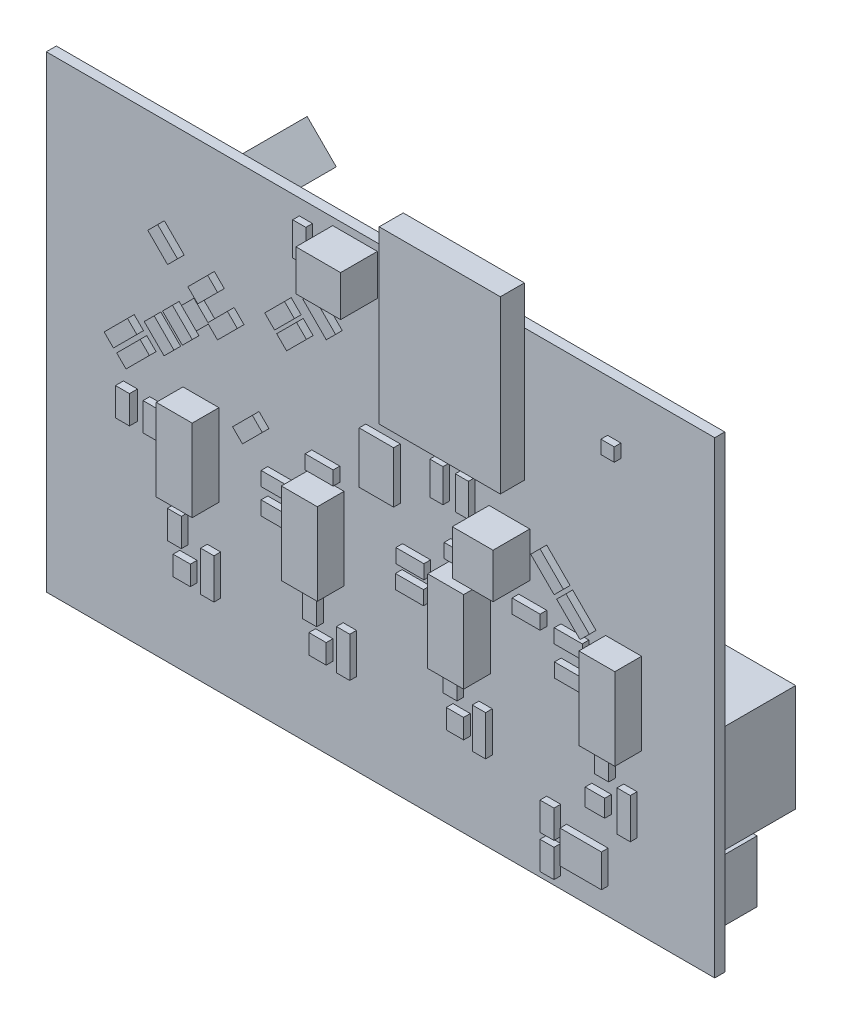
SolidWorks part; units mm, degrees
ref_plane "Front Plane" through (0, 0, 0) normal (0, 0, 1) x (1, 0, 0)
ref_plane "Top Plane" through (0, 0, 0) normal (0, 1, 0) x (1, 0, 0)
ref_plane "Right Plane" through (0, 0, 0) normal (1, 0, 0) x (0, 0, -1)
sketch "Sketch1" plane through (0, 0, 0) normal (0, 0, 1) x (1, 0, 0)
  line L0 (-0.0006, 0) -> (99.9994, 0)
  line L1 (99.9994, 0) -> (99.9994, 70)
  line L2 (99.9994, 70) -> (-0.0006, 70)
  line L3 (-0.0006, 70) -> (-0.0006, 0)
extrude "BOARD" add sketch "Sketch1" along normal blind 1.5 separate body
ref_plane "Plane1" through (0, 0, 1.5) normal (0, 0, 1) x (1, 0, 0)
sketch "Sketch2" plane through (0, 0, 0) normal (0, 0, 1) x (1, 0, 0)
  line L0 (84.8503, 10.084) -> (94.8323, 10.084)
  line L1 (94.8323, 10.084) -> (94.8323, 0.889)
  line L2 (94.8323, 0.889) -> (84.8503, 0.889)
  line L3 (84.8503, 0.889) -> (84.8503, 10.084)
extrude "W237-102-1" add sketch "Sketch2" against normal blind 10 separate body
sketch "Sketch3" plane through (0, 0, 1.5) normal (0, 0, 1) x (1, 0, 0)
  line L0 (19.8709, 47.5966) -> (22.8344, 44.6331)
  line L1 (22.8344, 44.6331) -> (21.3526, 43.1514)
  line L2 (21.3526, 43.1514) -> (18.3892, 46.1149)
  line L3 (18.3892, 46.1149) -> (19.8709, 47.5966)
extrude "C1206FAB-1" add sketch "Sketch3" along normal blind 1 separate body
sketch "Sketch4" plane through (0, 0, 1.5) normal (0, 0, 1) x (1, 0, 0)
  line L0 (18.6137, 40.4124) -> (15.6502, 43.3759)
  line L1 (15.6502, 43.3759) -> (17.1319, 44.8576)
  line L2 (17.1319, 44.8576) -> (20.0954, 41.8942)
  line L3 (20.0954, 41.8942) -> (18.6137, 40.4124)
extrude "C1206FAB-2" add sketch "Sketch4" along normal blind 1 separate body
sketch "Sketch5" plane through (0, 0, 1.5) normal (0, 0, 1) x (1, 0, 0)
  line L0 (76.9488, 10.9855) -> (76.9488, 6.7945)
  line L1 (76.9488, 6.7945) -> (74.8533, 6.7945)
  line L2 (74.8533, 6.7945) -> (74.8533, 10.9855)
  line L3 (74.8533, 10.9855) -> (76.9488, 10.9855)
extrude "C1206FAB-3" add sketch "Sketch5" along normal blind 1 separate body
sketch "Sketch6" plane through (0, 0, 1.5) normal (0, 0, 1) x (1, 0, 0)
  line L0 (76.9488, 5.9055) -> (76.9488, 1.7145)
  line L1 (76.9488, 1.7145) -> (74.8533, 1.7145)
  line L2 (74.8533, 1.7145) -> (74.8533, 5.9055)
  line L3 (74.8533, 5.9055) -> (76.9488, 5.9055)
extrude "C1206FAB-4" add sketch "Sketch6" along normal blind 1 separate body
sketch "Sketch7" plane through (0, 0, 1.5) normal (0, 0, 1) x (1, 0, 0)
  line L0 (33.671, 53.5037) -> (36.6345, 56.4672)
  line L1 (36.6345, 56.4672) -> (38.1162, 54.9854)
  line L2 (38.1162, 54.9854) -> (35.1527, 52.022)
  line L3 (35.1527, 52.022) -> (33.671, 53.5037)
extrude "C1206FAB-5" add sketch "Sketch7" along normal blind 1 separate body
sketch "Sketch8" plane through (0, 0, 1.5) normal (0, 0, 1) x (1, 0, 0)
  line L0 (35.4671, 51.7076) -> (38.4305, 54.6711)
  line L1 (38.4305, 54.6711) -> (39.9123, 53.1894)
  line L2 (39.9123, 53.1894) -> (36.9488, 50.2259)
  line L3 (36.9488, 50.2259) -> (35.4671, 51.7076)
extrude "C1206FAB-6" add sketch "Sketch8" along normal blind 1 separate body
sketch "Sketch9" plane through (0, 0, 1.5) normal (0, 0, 1) x (1, 0, 0)
  line L0 (88.3684, 18.323) -> (88.3684, 12.3262)
  line L1 (88.3684, 12.3262) -> (86.377, 12.3262)
  line L2 (86.377, 12.3262) -> (86.377, 18.323)
  line L3 (86.377, 18.323) -> (88.3684, 18.323)
extrude "SOD123-1" add sketch "Sketch9" along normal blind 1 separate body
sketch "Sketch10" plane through (0, 0, 1.5) normal (0, 0, 1) x (1, 0, 0)
  line L0 (26.0778, 18.2384) -> (26.0777, 12.2416)
  line L1 (26.0777, 12.2416) -> (24.0863, 12.2416)
  line L2 (24.0863, 12.2416) -> (24.0863, 18.2384)
  line L3 (24.0863, 18.2384) -> (26.0778, 18.2384)
extrude "SOD123-2" add sketch "Sketch10" along normal blind 1 separate body
sketch "Sketch11" plane through (0, 0, 1.5) normal (0, 0, 1) x (1, 0, 0)
  line L0 (46.3978, 18.2384) -> (46.3978, 12.2416)
  line L1 (46.3978, 12.2416) -> (44.4064, 12.2416)
  line L2 (44.4064, 12.2416) -> (44.4064, 18.2384)
  line L3 (44.4064, 18.2384) -> (46.3978, 18.2384)
extrude "SOD123-3" add sketch "Sketch11" along normal blind 1 separate body
sketch "Sketch12" plane through (0, 0, 1.5) normal (0, 0, 1) x (1, 0, 0)
  line L0 (66.7177, 18.2384) -> (66.7177, 12.2416)
  line L1 (66.7177, 12.2416) -> (64.7263, 12.2416)
  line L2 (64.7263, 12.2416) -> (64.7263, 18.2384)
  line L3 (64.7263, 18.2384) -> (66.7177, 18.2384)
extrude "SOD123-4" add sketch "Sketch12" along normal blind 1 separate body
sketch "Sketch13" plane through (0, 0, 1.5) normal (0, 0, 1) x (1, 0, 0)
  line L0 (77.8494, 3.95) -> (77.8494, 8.8516)
  line L1 (77.8494, 8.8516) -> (84.0493, 8.8516)
  line L2 (84.0493, 8.8516) -> (84.0493, 3.95)
  line L3 (84.0493, 3.95) -> (77.8494, 3.95)
extrude "SO08-1" add sketch "Sketch13" along normal blind 1 separate body
sketch "Sketch14" plane through (0, 0, 0) normal (0, 0, 1) x (1, 0, 0)
  line L0 (78.4783, 50.3609) -> (78.4783, 42.6647)
  line L1 (78.4783, 42.6647) -> (83.6345, 42.6647)
  line L2 (83.6345, 42.6647) -> (83.6345, 50.3609)
  line L3 (83.6345, 50.3609) -> (78.4783, 50.3609)
extrude "2X03-1" add sketch "Sketch14" against normal blind 8.5 separate body
sketch "Sketch15" plane through (0, 0, 1.5) normal (0, 0, 1) x (1, 0, 0)
  line L0 (47.8001, 37.9798) -> (47.8001, 45.676)
  line L1 (47.8001, 45.676) -> (52.9563, 45.676)
  line L2 (52.9563, 45.676) -> (52.9563, 37.9798)
  line L3 (52.9563, 37.9798) -> (47.8001, 37.9798)
extrude "2X03-2" add sketch "Sketch15" along normal blind 1 separate body
sketch "Sketch16" plane through (0, 0, 0) normal (0, 0, 1) x (1, 0, 0)
  line L0 (31.7093, 27.05) -> (11.4594, 27.05)
  line L1 (11.4594, 27.05) -> (11.4594, 11.05)
  line L2 (11.4594, 11.05) -> (31.7093, 11.05)
  line L3 (31.7093, 11.05) -> (31.7093, 27.05)
extrude "RELAY_SRD-05VDC-SL-C-1" add sketch "Sketch16" against normal blind 15.3928 separate body
sketch "Sketch17" plane through (0, 0, 0) normal (0, 0, 1) x (1, 0, 0)
  line L0 (95.2094, 27.05) -> (74.9594, 27.05)
  line L1 (74.9594, 27.05) -> (74.9594, 11.05)
  line L2 (74.9594, 11.05) -> (95.2094, 11.05)
  line L3 (95.2094, 11.05) -> (95.2094, 27.05)
extrude "RELAY_SRD-05VDC-SL-C-2" add sketch "Sketch17" against normal blind 15.4 separate body
sketch "Sketch18" plane through (0, 0, 0) normal (0, 0, 1) x (1, 0, 0)
  line L0 (52.0293, 27.05) -> (31.7793, 27.05)
  line L1 (31.7793, 27.05) -> (31.7793, 11.05)
  line L2 (31.7793, 11.05) -> (52.0293, 11.05)
  line L3 (52.0293, 11.05) -> (52.0293, 27.05)
extrude "RELAY_SRD-05VDC-SL-C-3" add sketch "Sketch18" against normal up to surface (15.4 mm away) separate body up to face at (85.0844, 19.05, -15.4)
sketch "Sketch19" plane through (0, 0, 0) normal (0, 0, 1) x (1, 0, 0)
  line L0 (72.3494, 27.05) -> (52.0994, 27.05)
  line L1 (52.0994, 27.05) -> (52.0994, 11.05)
  line L2 (52.0994, 11.05) -> (72.3494, 11.05)
  line L3 (72.3494, 11.05) -> (72.3494, 27.05)
extrude "RELAY_SRD-05VDC-SL-C-4" add sketch "Sketch19" against normal up to surface (15.4 mm away) separate body up to face at (85.0844, 19.05, -15.4)
sketch "Sketch20" plane through (0, 0, 0) normal (0, 0, 1) x (1, 0, 0)
  line L0 (31.3382, 40.7304) -> (35.1099, 44.5022)
  line L1 (35.1099, 44.5022) -> (30.5299, 49.0821)
  line L2 (30.5299, 49.0821) -> (26.7582, 45.3104)
  line L3 (26.7582, 45.3104) -> (31.3382, 40.7304)
extrude "22-23-2021-1" add sketch "Sketch20" against normal blind 12 separate body
sketch "Sketch21" plane through (0, 0, 1.5) normal (0, 0, 1) x (1, 0, 0)
  line L0 (84.5347, 13.4608) -> (81.6137, 13.4608)
  line L1 (81.6137, 13.4608) -> (81.6137, 16.0516)
  line L2 (81.6137, 16.0516) -> (84.5347, 16.0516)
  line L3 (84.5347, 16.0516) -> (84.5347, 13.4608)
extrude "SOT23-1" add sketch "Sketch21" along normal blind 1 separate body
sketch "Sketch22" plane through (0, 0, 1.5) normal (0, 0, 1) x (1, 0, 0)
  line L0 (22.5548, 15.3924) -> (22.5548, 12.4714)
  line L1 (22.5548, 12.4714) -> (19.964, 12.4714)
  line L2 (19.964, 12.4714) -> (19.964, 15.3924)
  line L3 (19.964, 15.3924) -> (22.5548, 15.3924)
extrude "SOT23-2" add sketch "Sketch22" along normal blind 1 separate body
sketch "Sketch23" plane through (0, 0, 1.5) normal (0, 0, 1) x (1, 0, 0)
  line L0 (42.8747, 15.3924) -> (42.8747, 12.4714)
  line L1 (42.8747, 12.4714) -> (40.2839, 12.4714)
  line L2 (40.2839, 12.4714) -> (40.2839, 15.3924)
  line L3 (40.2839, 15.3924) -> (42.8747, 15.3924)
extrude "SOT23-3" add sketch "Sketch23" along normal blind 1 separate body
sketch "Sketch24" plane through (0, 0, 1.5) normal (0, 0, 1) x (1, 0, 0)
  line L0 (63.4265, 15.9752) -> (63.4265, 13.0542)
  line L1 (63.4265, 13.0542) -> (60.8357, 13.0542)
  line L2 (60.8357, 13.0542) -> (60.8357, 15.9752)
  line L3 (60.8357, 15.9752) -> (63.4265, 15.9752)
extrude "SOT23-4" add sketch "Sketch24" along normal blind 1 separate body
sketch "Sketch25" plane through (0, 0, 1.5) normal (0, 0, 1) x (1, 0, 0)
  line L0 (85.1422, 22.6559) -> (85.1422, 18.4649)
  line L1 (85.1422, 18.4649) -> (83.0467, 18.4649)
  line L2 (83.0467, 18.4649) -> (83.0467, 22.6559)
  line L3 (83.0467, 22.6559) -> (85.1422, 22.6559)
extrude "R1206FAB-1" add sketch "Sketch25" along normal blind 1 separate body
sketch "Sketch26" plane through (0, 0, 1.5) normal (0, 0, 1) x (1, 0, 0)
  line L0 (21.2024, 20.9114) -> (21.2024, 16.7204)
  line L1 (21.2024, 16.7204) -> (19.1069, 16.7204)
  line L2 (19.1069, 16.7204) -> (19.1069, 20.9114)
  line L3 (19.1069, 20.9114) -> (21.2024, 20.9114)
extrude "R1206FAB-2" add sketch "Sketch26" along normal blind 1 separate body
sketch "Sketch27" plane through (0, 0, 1.5) normal (0, 0, 1) x (1, 0, 0)
  line L0 (15.4713, 28.8569) -> (15.4713, 33.0479)
  line L1 (15.4713, 33.0479) -> (17.5668, 33.0479)
  line L2 (17.5668, 33.0479) -> (17.5668, 28.8569)
  line L3 (17.5668, 28.8569) -> (15.4713, 28.8569)
extrude "R1206FAB-3" add sketch "Sketch27" along normal blind 1 separate body
sketch "Sketch28" plane through (0, 0, 1.5) normal (0, 0, 1) x (1, 0, 0)
  line L0 (41.4355, 20.9102) -> (41.4355, 16.7192)
  line L1 (41.4355, 16.7192) -> (39.34, 16.7192)
  line L2 (39.34, 16.7192) -> (39.34, 20.9102)
  line L3 (39.34, 20.9102) -> (41.4355, 20.9102)
extrude "R1206FAB-4" add sketch "Sketch28" along normal blind 1 separate body
sketch "Sketch29" plane through (0, 0, 1.5) normal (0, 0, 1) x (1, 0, 0)
  line L0 (62.4484, 21.8076) -> (62.4484, 17.6166)
  line L1 (62.4484, 17.6166) -> (60.3529, 17.6166)
  line L2 (60.3529, 17.6166) -> (60.3529, 21.8076)
  line L3 (60.3529, 21.8076) -> (62.4484, 21.8076)
extrude "R1206FAB-5" add sketch "Sketch29" along normal blind 1 separate body
sketch "Sketch30" plane through (0, 0, 1.5) normal (0, 0, 1) x (1, 0, 0)
  line L0 (53.2265, 29.5255) -> (57.4175, 29.5255)
  line L1 (57.4175, 29.5255) -> (57.4175, 27.43)
  line L2 (57.4175, 27.43) -> (53.2265, 27.43)
  line L3 (53.2265, 27.43) -> (53.2265, 29.5255)
extrude "R1206FAB-6" add sketch "Sketch30" along normal blind 1 separate body
sketch "Sketch31" plane through (0, 0, 1.5) normal (0, 0, 1) x (1, 0, 0)
  line L0 (29.5748, 49.4345) -> (26.6113, 46.471)
  line L1 (26.6113, 46.471) -> (25.1295, 47.9528)
  line L2 (25.1295, 47.9528) -> (28.093, 50.9163)
  line L3 (28.093, 50.9163) -> (29.5748, 49.4345)
extrude "R1206FAB-7" add sketch "Sketch31" along normal blind 1 separate body
sketch "Sketch32" plane through (0, 0, 1.5) normal (0, 0, 1) x (1, 0, 0)
  line L0 (33.1338, 29.0195) -> (37.3248, 29.0195)
  line L1 (37.3248, 29.0195) -> (37.3248, 26.924)
  line L2 (37.3248, 26.924) -> (33.1338, 26.924)
  line L3 (33.1338, 26.924) -> (33.1338, 29.0195)
extrude "R1206FAB-8" add sketch "Sketch32" along normal blind 1 separate body
sketch "Sketch33" plane through (0, 0, 1.5) normal (0, 0, 1) x (1, 0, 0)
  line L0 (22.1772, 51.1496) -> (25.1407, 54.1131)
  line L1 (25.1407, 54.1131) -> (26.6224, 52.6313)
  line L2 (26.6224, 52.6313) -> (23.6589, 49.6678)
  line L3 (23.6589, 49.6678) -> (22.1772, 51.1496)
extrude "R1206FAB-9" add sketch "Sketch33" along normal blind 1 separate body
sketch "Sketch34" plane through (0, 0, 1.5) normal (0, 0, 1) x (1, 0, 0)
  line L0 (19.144, 52.5026) -> (16.1805, 55.4661)
  line L1 (16.1805, 55.4661) -> (17.6622, 56.9479)
  line L2 (17.6622, 56.9479) -> (20.6257, 53.9844)
  line L3 (20.6257, 53.9844) -> (19.144, 52.5026)
extrude "R1206FAB-10" add sketch "Sketch34" along normal blind 1 separate body
sketch "Sketch35" plane through (0, 0, 1.5) normal (0, 0, 1) x (1, 0, 0)
  line L0 (77.0151, 29.9613) -> (81.2061, 29.9613)
  line L1 (81.2061, 29.9613) -> (81.2061, 27.8658)
  line L2 (81.2061, 27.8658) -> (77.0151, 27.8658)
  line L3 (77.0151, 27.8658) -> (77.0151, 29.9613)
extrude "R1206FAB-11" add sketch "Sketch35" along normal blind 1 separate body
sketch "Sketch36" plane through (0, 0, 1.5) normal (0, 0, 1) x (1, 0, 0)
  line L0 (39.8191, 67.6651) -> (39.8191, 62.7191)
  line L1 (39.8191, 62.7191) -> (37.8531, 62.7191)
  line L2 (37.8531, 62.7191) -> (37.8531, 67.6651)
  line L3 (37.8531, 67.6651) -> (39.8191, 67.6651)
extrude "R1206-1" add sketch "Sketch36" along normal blind 1 separate body
sketch "Sketch37" plane through (0, 0, 1.5) normal (0, 0, 1) x (1, 0, 0)
  line L0 (11.5317, 37.2524) -> (15.0291, 40.7497)
  line L1 (15.0291, 40.7497) -> (16.4192, 39.3596)
  line L2 (16.4192, 39.3596) -> (12.9219, 35.8622)
  line L3 (12.9219, 35.8622) -> (11.5317, 37.2524)
extrude "R1206-2" add sketch "Sketch37" along normal blind 1 separate body
sketch "Sketch38" plane through (0, 0, 1.5) normal (0, 0, 1) x (1, 0, 0)
  line L0 (62.1864, 41.977) -> (62.1864, 46.923)
  line L1 (62.1864, 46.923) -> (64.1523, 46.923)
  line L2 (64.1523, 46.923) -> (64.1523, 41.977)
  line L3 (64.1523, 41.977) -> (62.1864, 41.977)
extrude "R1206-3" add sketch "Sketch38" along normal blind 1 separate body
sketch "Sketch39" plane through (0, 0, 1.5) normal (0, 0, 1) x (1, 0, 0)
  line L0 (40.7767, 59.514) -> (44.274, 56.0167)
  line L1 (44.274, 56.0167) -> (42.8839, 54.6265)
  line L2 (42.8839, 54.6265) -> (39.3865, 58.1239)
  line L3 (39.3865, 58.1239) -> (40.7767, 59.514)
extrude "R1206-4" add sketch "Sketch39" along normal blind 1 separate body
sketch "Sketch40" plane through (0, 0, 1.5) normal (0, 0, 1) x (1, 0, 0)
  line L0 (76.9672, 38.6421) -> (73.4699, 42.1394)
  line L1 (73.4699, 42.1394) -> (74.8601, 43.5296)
  line L2 (74.8601, 43.5296) -> (78.3574, 40.0322)
  line L3 (78.3574, 40.0322) -> (76.9672, 38.6421)
extrude "R1206-5" add sketch "Sketch40" along normal blind 1 separate body
sketch "Sketch41" plane through (0, 0, 1.5) normal (0, 0, 1) x (1, 0, 0)
  line L0 (70.6782, 35.0758) -> (74.8692, 35.0758)
  line L1 (74.8692, 35.0758) -> (74.8692, 32.9803)
  line L2 (74.8692, 32.9803) -> (70.6782, 32.9803)
  line L3 (70.6782, 32.9803) -> (70.6782, 35.0758)
extrude "R1206FAB-12" add sketch "Sketch41" along normal blind 1 separate body
sketch "Sketch42" plane through (0, 0, 1.5) normal (0, 0, 1) x (1, 0, 0)
  line L0 (33.3079, 37.8301) -> (30.3444, 34.8666)
  line L1 (30.3444, 34.8666) -> (28.8627, 36.3484)
  line L2 (28.8627, 36.3484) -> (31.8262, 39.3118)
  line L3 (31.8262, 39.3118) -> (33.3079, 37.8301)
extrude "R1206FAB-13" add sketch "Sketch42" along normal blind 1 separate body
sketch "Sketch43" plane through (0, 0, 1.5) normal (0, 0, 1) x (1, 0, 0)
  line L0 (39.7177, 38.2765) -> (43.9087, 38.2765)
  line L1 (43.9087, 38.2765) -> (43.9087, 36.181)
  line L2 (43.9087, 36.181) -> (39.7177, 36.181)
  line L3 (39.7177, 36.181) -> (39.7177, 38.2765)
extrude "R1206FAB-14" add sketch "Sketch43" along normal blind 1 separate body
sketch "Sketch44" plane through (0, 0, 1.5) normal (0, 0, 1) x (1, 0, 0)
  line L0 (60.5134, 37.1906) -> (64.7044, 37.1906)
  line L1 (64.7044, 37.1906) -> (64.7044, 35.0951)
  line L2 (64.7044, 35.0951) -> (60.5134, 35.0951)
  line L3 (60.5134, 35.0951) -> (60.5134, 37.1906)
extrude "R1206FAB-15" add sketch "Sketch44" along normal blind 1 separate body
sketch "Sketch45" plane through (0, 0, 1.5) normal (0, 0, 1) x (1, 0, 0)
  line L0 (85.9632, 60.2956) -> (83.9632, 60.2956)
  line L1 (83.9632, 60.2956) -> (83.9632, 62.2956)
  line L2 (83.9632, 62.2956) -> (85.9632, 62.2956)
  line L3 (85.9632, 62.2956) -> (85.9632, 60.2956)
extrude "1X06SMD-1" add sketch "Sketch45" along normal blind 1 separate body
sketch "Sketch46" plane through (0, 0, 1.5) normal (0, 0, 1) x (1, 0, 0)
  line L0 (49.5256, 62.807) -> (42.8454, 62.807)
  line L1 (42.8454, 62.807) -> (42.8454, 68.903)
  line L2 (42.8454, 68.903) -> (49.5256, 68.903)
  line L3 (49.5256, 68.903) -> (49.5256, 62.807)
extrude "6MM_SWITCH-1" add sketch "Sketch46" along normal blind 5.5 separate body
sketch "Sketch47" plane through (0, 0, 1.5) normal (0, 0, 1) x (1, 0, 0)
  line L0 (72.3286, 44.3408) -> (72.3286, 37.6606)
  line L1 (72.3286, 37.6606) -> (66.2326, 37.6606)
  line L2 (66.2326, 37.6606) -> (66.2326, 44.3408)
  line L3 (66.2326, 44.3408) -> (72.3286, 44.3408)
extrude "6MM_SWITCH-2" add sketch "Sketch47" along normal blind 5.5 separate body
sketch "Sketch48" plane through (0, 0, 1.5) normal (0, 0, 1) x (1, 0, 0)
  line L0 (53.2947, 32.9182) -> (57.4857, 32.9182)
  line L1 (57.4857, 32.9182) -> (57.4857, 30.8227)
  line L2 (57.4857, 30.8227) -> (53.2947, 30.8227)
  line L3 (53.2947, 30.8227) -> (53.2947, 32.9182)
extrude "LED1206FAB-1" add sketch "Sketch48" along normal blind 1 separate body
sketch "Sketch49" plane through (0, 0, 1.5) normal (0, 0, 1) x (1, 0, 0)
  line L0 (21.2179, 48.2432) -> (23.0858, 50.1111)
  line L1 (23.0858, 50.1111) -> (25.295, 47.902)
  line L2 (25.295, 47.902) -> (23.4271, 46.0341)
  line L3 (23.4271, 46.0341) -> (21.2179, 48.2432)
extrude "SOT95P237X112-3N-1" add sketch "Sketch49" along normal blind 1 separate body
sketch "Sketch50" plane through (0, 0, 1.5) normal (0, 0, 1) x (1, 0, 0)
  line L0 (11.5419, 28.9365) -> (11.5419, 33.1275)
  line L1 (11.5419, 33.1275) -> (13.6374, 33.1275)
  line L2 (13.6374, 33.1275) -> (13.6374, 28.9365)
  line L3 (13.6374, 28.9365) -> (11.5419, 28.9365)
extrude "LED1206FAB-2" add sketch "Sketch50" along normal blind 1.1952 separate body
sketch "Sketch51" plane through (0, 0, 1.5) normal (0, 0, 1) x (1, 0, 0)
  line L0 (33.1338, 32.8295) -> (37.3248, 32.8295)
  line L1 (37.3248, 32.8295) -> (37.3248, 30.734)
  line L2 (37.3248, 30.734) -> (33.1338, 30.734)
  line L3 (33.1338, 30.734) -> (33.1338, 32.8295)
extrude "LED1206FAB-3" add sketch "Sketch51" along normal blind 1 separate body
sketch "Sketch52" plane through (0, 0, 1.5) normal (0, 0, 1) x (1, 0, 0)
  line L0 (76.987, 34.3751) -> (81.178, 34.3751)
  line L1 (81.178, 34.3751) -> (81.178, 32.2796)
  line L2 (81.178, 32.2796) -> (76.987, 32.2796)
  line L3 (76.987, 32.2796) -> (76.987, 34.3751)
extrude "LED1206FAB-4" add sketch "Sketch52" along normal blind 1 separate body
sketch "Sketch53" plane through (0, 0, 0) normal (0, 0, 1) x (1, 0, 0)
  line L0 (12.5234, 54.636) -> (3.4534, 45.5659)
  line L1 (3.4534, 45.5659) -> (7.8088, 41.2105)
  line L2 (7.8088, 41.2105) -> (16.8789, 50.2806)
  line L3 (16.8789, 50.2806) -> (12.5234, 54.636)
extrude "TEMP-HUM-SENSOR-DHT11-1" add sketch "Sketch53" against normal blind 25 separate body
sketch "Sketch54" plane through (0, 0, 1.5) normal (0, 0, 1) x (1, 0, 0)
  line L0 (78.7403, 39.6485) -> (82.2376, 36.1511)
  line L1 (82.2376, 36.1511) -> (80.8474, 34.7609)
  line L2 (80.8474, 34.7609) -> (77.3501, 38.2583)
  line L3 (77.3501, 38.2583) -> (78.7403, 39.6485)
extrude "LED1206-1" add sketch "Sketch54" along normal blind 1 separate body
sketch "Sketch55" plane through (0, 0, 1.5) normal (0, 0, 1) x (1, 0, 0)
  line L0 (9.6506, 39.0312) -> (13.148, 42.5285)
  line L1 (13.148, 42.5285) -> (14.5381, 41.1384)
  line L2 (14.5381, 41.1384) -> (11.0408, 37.641)
  line L3 (11.0408, 37.641) -> (9.6506, 39.0312)
extrude "LED1206-2" add sketch "Sketch55" along normal blind 1 separate body
sketch "Sketch56" plane through (0, 0, 1.5) normal (0, 0, 1) x (1, 0, 0)
  line L0 (58.3764, 41.977) -> (58.3764, 46.923)
  line L1 (58.3764, 46.923) -> (60.3423, 46.923)
  line L2 (60.3423, 46.923) -> (60.3423, 41.977)
  line L3 (60.3423, 41.977) -> (58.3764, 41.977)
extrude "LED1206-3" add sketch "Sketch56" along normal blind 1 separate body
sketch "Sketch57" plane through (0, 0, 1.5) normal (0, 0, 1) x (1, 0, 0)
  line L0 (53.397, 75.8254) -> (71.524, 75.8254)
  line L1 (71.524, 75.8254) -> (71.524, 50.2619)
  line L2 (71.524, 50.2619) -> (53.397, 50.2619)
  line L3 (53.397, 50.2619) -> (53.397, 75.8254)
extrude "ESP-WROOM-32-1" add sketch "Sketch57" along normal blind 3.6 separate body
sketch "Sketch58" plane through (0, 0, 1.5) normal (0, 0, 1) x (1, 0, 0)
  line L0 (89.0524, 36.2134) -> (89.0524, 23.9534)
  line L1 (89.0524, 23.9534) -> (83.6724, 23.9534)
  line L2 (83.6724, 23.9534) -> (83.6724, 36.2134)
  line L3 (83.6724, 36.2134) -> (89.0524, 36.2134)
extrude "SOIC254P1030X460-4N-1" add sketch "Sketch58" along normal blind 4 separate body
sketch "Sketch59" plane through (0, 0, 1.5) normal (0, 0, 1) x (1, 0, 0)
  line L0 (25.8254, 36.8061) -> (25.8254, 24.5461)
  line L1 (25.8254, 24.5461) -> (20.4454, 24.5461)
  line L2 (20.4454, 24.5461) -> (20.4454, 36.8061)
  line L3 (20.4454, 36.8061) -> (25.8254, 36.8061)
extrude "SOIC254P1030X460-4N-2" add sketch "Sketch59" along normal blind 4 separate body
sketch "Sketch60" plane through (0, 0, 1.5) normal (0, 0, 1) x (1, 0, 0)
  line L0 (44.5422, 35.328) -> (44.5422, 23.068)
  line L1 (44.5422, 23.068) -> (39.1622, 23.068)
  line L2 (39.1622, 23.068) -> (39.1622, 35.328)
  line L3 (39.1622, 35.328) -> (44.5422, 35.328)
extrude "SOIC254P1030X460-4N-3" add sketch "Sketch60" along normal blind 4 separate body
sketch "Sketch61" plane through (0, 0, 1.5) normal (0, 0, 1) x (1, 0, 0)
  line L0 (66.437, 34.896) -> (66.437, 22.636)
  line L1 (66.437, 22.636) -> (61.057, 22.636)
  line L2 (61.057, 22.636) -> (61.057, 34.896)
  line L3 (61.057, 34.896) -> (66.437, 34.896)
extrude "SOIC254P1030X460-4N-4" add sketch "Sketch61" along normal blind 4 separate body
sketch "Sketch62" plane through (0, 0, 0) normal (0, 0, 1) x (1, 0, 0)
  line L0 (21.3503, 10.084) -> (31.3323, 10.084)
  line L1 (31.3323, 10.084) -> (31.3323, 0.889)
  line L2 (31.3323, 0.889) -> (21.3503, 0.889)
  line L3 (21.3503, 0.889) -> (21.3503, 10.084)
extrude "W237-102-2" add sketch "Sketch62" against normal blind 10 separate body
sketch "Sketch63" plane through (0, 0, 0) normal (0, 0, 1) x (1, 0, 0)
  line L0 (41.6704, 10.084) -> (51.6524, 10.084)
  line L1 (51.6524, 10.084) -> (51.6524, 0.889)
  line L2 (51.6524, 0.889) -> (41.6704, 0.889)
  line L3 (41.6704, 0.889) -> (41.6704, 10.084)
extrude "W237-102-3" add sketch "Sketch63" along normal blind 1 and the other way blind 10 separate body
sketch "Sketch64" plane through (0, 0, 0) normal (0, 0, 1) x (1, 0, 0)
  line L0 (61.9903, 10.084) -> (71.9723, 10.084)
  line L1 (71.9723, 10.084) -> (71.9723, 0.889)
  line L2 (71.9723, 0.889) -> (61.9903, 0.889)
  line L3 (61.9903, 0.889) -> (61.9903, 10.084)
extrude "W237-102-4" add sketch "Sketch64" along normal blind 1 and the other way blind 10 separate body
sketch "Sketch65" plane through (0, 0, 0) normal (0, 0, 1) x (1, 0, 0)
  line L0 (42.28, 55.6462) -> (40.4062, 57.52)
  line L1 (40.4062, 57.52) -> (38.5324, 55.6462)
  line L2 (38.5324, 55.6462) -> (40.4062, 53.7724)
  line L3 (40.4062, 53.7724) -> (42.28, 55.6462)
extrude "XTAL_ECS-_327-12_5-13X-1" add sketch "Sketch65" against normal blind 6.5 separate body
sketch "Sketch66" plane through (0, 0, 1.5) normal (0, 0, 1) x (1, 0, 0)
  line L0 (-0.0007, 0) -> (99.9994, 0)
  line L1 (99.9994, 0) -> (99.9994, 70)
  line L2 (99.9994, 70) -> (-0.0007, 70)
  line L3 (-0.0007, 70) -> (-0.0007, 0)
  line L4 (86.3484, 4.064) -> (88.3554, 6.071)
  line L5 (91.3274, 4.089) -> (93.3084, 6.096)
  line L6 (84.8504, 0.889) -> (94.8324, 0.889)
  line L7 (94.8324, 10.084) -> (94.8324, 9.881)
  line L8 (94.8324, 10.084) -> (84.8504, 10.084)
  line L9 (84.8504, 0.889) -> (84.8504, 3.277)
  line L10 (84.8504, 3.277) -> (86.4504, 3.277)
  line L11 (86.4504, 3.277) -> (88.2284, 3.277)
  line L12 (88.2284, 3.277) -> (91.4544, 3.277)
  line L13 (93.2324, 3.277) -> (94.8324, 3.277)
  line L14 (84.8504, 3.277) -> (84.8504, 9.881)
  line L15 (94.8324, 3.277) -> (94.8324, 0.889)
  line L16 (84.8504, 9.881) -> (94.8324, 9.881)
  line L17 (84.8504, 9.881) -> (84.8504, 10.084)
  line L18 (94.8324, 9.881) -> (94.8324, 3.277)
  line L19 (91.4544, 3.277) -> (93.2324, 3.277)
  line L20 (85.3709, 7.9375) -> (85.6883, 8.1915)
  line L21 (85.6883, 8.1915) -> (85.6883, 7.0485)
  line L22 (85.3709, 7.0485) -> (86.0059, 7.0485)
  line L23 (90.8636, 7.6835) -> (90.3239, 7.0485)
  line L24 (90.3239, 7.0485) -> (90.9588, 7.0485)
  line L25 (87.3394, 4.0831) -> (87.3394, 6.077)
  line L26 (92.3394, 4.0831) -> (92.3394, 6.077)
  line L27 (19.8709, 47.5068) -> (22.7446, 44.6331)
  line L28 (22.7446, 44.6331) -> (21.3077, 43.1963)
  line L29 (21.3077, 43.1963) -> (18.4341, 46.07)
  line L30 (18.4341, 46.07) -> (19.8709, 47.5068)
  line L31 (18.6137, 40.5022) -> (15.74, 43.3759)
  line L32 (15.74, 43.3759) -> (17.1768, 44.8127)
  line L33 (17.1768, 44.8127) -> (20.0505, 41.9391)
  line L34 (20.0505, 41.9391) -> (18.6137, 40.5022)
  line L35 (76.8854, 10.922) -> (76.8854, 6.858)
  line L36 (76.8854, 6.858) -> (74.8534, 6.858)
  line L37 (74.8534, 6.858) -> (74.8534, 10.922)
  line L38 (74.8534, 10.922) -> (76.8854, 10.922)
  line L39 (76.8854, 5.842) -> (76.8854, 1.778)
  line L40 (76.8854, 1.778) -> (74.8534, 1.778)
  line L41 (74.8534, 1.778) -> (74.8534, 5.842)
  line L42 (74.8534, 5.842) -> (76.8854, 5.842)
  line L43 (33.7608, 53.5037) -> (36.6345, 56.3774)
  line L44 (36.6345, 56.3774) -> (38.0713, 54.9405)
  line L45 (38.0713, 54.9405) -> (35.1976, 52.0669)
  line L46 (35.1976, 52.0669) -> (33.7608, 53.5037)
  line L47 (35.5569, 51.7076) -> (38.4305, 54.5813)
  line L48 (38.4305, 54.5813) -> (39.8674, 53.1445)
  line L49 (39.8674, 53.1445) -> (36.9937, 50.2708)
  line L50 (36.9937, 50.2708) -> (35.5569, 51.7076)
  line L51 (88.147, 16.6456) -> (88.147, 14.0036)
  line L52 (86.573, 16.6456) -> (86.573, 14.0036)
  line L53 (86.573, 16.6456) -> (88.147, 16.6456)
  line L54 (86.573, 14.0036) -> (88.147, 14.0036)
  line L55 (87.36, 16.3246) -> (87.86, 15.3246)
  line L56 (87.86, 15.3246) -> (86.86, 15.3246)
  line L57 (86.86, 15.3246) -> (87.36, 16.3246)
  line L58 (87.86, 16.3246) -> (87.36, 16.3246)
  line L59 (87.36, 16.3246) -> (86.86, 16.3246)
  line L60 (88.249, 17.9916) -> (86.471, 17.9916)
  line L61 (88.249, 18.2456) -> (86.471, 18.2456)
  line L62 (86.471, 18.2456) -> (86.471, 12.5306)
  line L63 (86.471, 12.5306) -> (88.249, 12.5306)
  line L64 (88.249, 12.5306) -> (88.249, 18.2456)
  line L65 (25.8564, 16.561) -> (25.8564, 13.919)
  line L66 (24.2824, 16.561) -> (24.2824, 13.919)
  line L67 (24.2824, 16.561) -> (25.8564, 16.561)
  line L68 (24.2824, 13.919) -> (25.8564, 13.919)
  line L69 (25.0694, 16.24) -> (25.5694, 15.24)
  line L70 (25.5694, 15.24) -> (24.5694, 15.24)
  line L71 (24.5694, 15.24) -> (25.0694, 16.24)
  line L72 (25.5694, 16.24) -> (25.0694, 16.24)
  line L73 (25.0694, 16.24) -> (24.5694, 16.24)
  line L74 (25.9584, 17.907) -> (24.1804, 17.907)
  line L75 (25.9584, 18.161) -> (24.1804, 18.161)
  line L76 (24.1804, 18.161) -> (24.1804, 12.446)
  line L77 (24.1804, 12.446) -> (25.9584, 12.446)
  line L78 (25.9584, 12.446) -> (25.9584, 18.161)
  line L79 (46.1763, 16.561) -> (46.1763, 13.919)
  line L80 (44.6024, 16.561) -> (44.6024, 13.919)
  line L81 (44.6024, 16.561) -> (46.1763, 16.561)
  line L82 (44.6024, 13.919) -> (46.1763, 13.919)
  line L83 (45.3894, 16.24) -> (45.8894, 15.24)
  line L84 (45.8894, 15.24) -> (44.8894, 15.24)
  line L85 (44.8894, 15.24) -> (45.3894, 16.24)
  line L86 (45.8894, 16.24) -> (45.3894, 16.24)
  line L87 (45.3894, 16.24) -> (44.8894, 16.24)
  line L88 (46.2784, 17.907) -> (44.5004, 17.907)
  line L89 (46.2784, 18.161) -> (44.5004, 18.161)
  line L90 (44.5004, 18.161) -> (44.5004, 12.446)
  line L91 (44.5004, 12.446) -> (46.2784, 12.446)
  line L92 (46.2784, 12.446) -> (46.2784, 18.161)
  line L93 (66.4964, 16.561) -> (66.4964, 13.919)
  line L94 (64.9224, 16.561) -> (64.9224, 13.919)
  line L95 (64.9224, 16.561) -> (66.4964, 16.561)
  line L96 (64.9224, 13.919) -> (66.4964, 13.919)
  line L97 (65.7094, 16.24) -> (66.2094, 15.24)
  line L98 (66.2094, 15.24) -> (65.2094, 15.24)
  line L99 (65.2094, 15.24) -> (65.7094, 16.24)
  line L100 (66.2094, 16.24) -> (65.7094, 16.24)
  line L101 (65.7094, 16.24) -> (65.2094, 16.24)
  line L102 (66.5983, 17.907) -> (64.8204, 17.907)
  line L103 (66.5983, 18.161) -> (64.8204, 18.161)
  line L104 (64.8204, 18.161) -> (64.8204, 12.446)
  line L105 (64.8204, 12.446) -> (66.5983, 12.446)
  line L106 (66.5983, 12.446) -> (66.5983, 18.161)
  line L107 (79.0494, 8.75) -> (82.3494, 8.75)
  line L108 (82.3494, 8.75) -> (82.8494, 8.75)
  line L109 (82.8494, 8.75) -> (82.8494, 3.95)
  line L110 (82.8494, 3.95) -> (82.3494, 3.95)
  line L111 (82.3494, 3.95) -> (79.0494, 3.95)
  line L112 (79.0494, 3.95) -> (79.0494, 8.75)
  line L113 (82.3494, 8.75) -> (82.3494, 3.95)
  line L114 (82.9233, 50.2847) -> (83.5583, 49.6497)
  line L115 (83.5583, 48.3797) -> (82.9233, 47.7447)
  line L116 (82.9233, 47.7447) -> (83.5583, 47.1097)
  line L117 (83.5583, 45.8397) -> (82.9233, 45.2047)
  line L118 (82.9233, 50.2847) -> (79.1133, 50.2847)
  line L119 (79.1133, 50.2847) -> (78.4783, 49.6497)
  line L120 (78.4783, 49.6497) -> (78.4783, 48.3797)
  line L121 (78.4783, 48.3797) -> (79.1133, 47.7447)
  line L122 (79.1133, 47.7447) -> (78.4783, 47.1097)
  line L123 (78.4783, 47.1097) -> (78.4783, 45.8397)
  line L124 (78.4783, 45.8397) -> (79.1133, 45.2047)
  line L125 (79.1133, 47.7447) -> (82.9233, 47.7447)
  line L126 (79.1133, 45.2047) -> (82.9233, 45.2047)
  line L127 (83.5583, 47.1097) -> (83.5583, 45.8397)
  line L128 (83.5583, 49.6497) -> (83.5583, 48.3797)
  line L129 (82.9233, 45.2047) -> (83.5583, 44.5697)
  line L130 (83.5583, 43.2997) -> (82.9233, 42.6647)
  line L131 (79.1133, 45.2047) -> (78.4783, 44.5697)
  line L132 (78.4783, 44.5697) -> (78.4783, 43.2997)
  line L133 (78.4783, 43.2997) -> (79.1133, 42.6647)
  line L134 (79.1133, 42.6647) -> (82.9233, 42.6647)
  line L135 (83.5583, 44.5697) -> (83.5583, 43.2997)
  line L136 (82.1094, 49.4465) -> (82.4672, 49.4465)
  line L137 (82.4672, 49.4465) -> (82.7201, 49.1936)
  line L138 (82.7201, 49.1936) -> (82.7201, 48.8358)
  line L139 (82.7201, 48.8358) -> (82.4672, 48.5829)
  line L140 (82.4672, 48.5829) -> (82.1094, 48.5829)
  line L141 (82.1094, 48.5829) -> (81.8565, 48.8358)
  line L142 (81.8565, 48.8358) -> (81.8565, 49.1936)
  line L143 (81.8565, 49.1936) -> (82.1094, 49.4465)
  line L144 (82.1094, 49.4465) -> (82.4672, 49.4465)
  line L145 (79.5694, 49.4465) -> (79.9272, 49.4465)
  line L146 (79.9272, 49.4465) -> (80.1801, 49.1936)
  line L147 (80.1801, 49.1936) -> (80.1801, 48.8358)
  line L148 (80.1801, 48.8358) -> (79.9272, 48.5829)
  line L149 (79.9272, 48.5829) -> (79.5694, 48.5829)
  line L150 (79.5694, 48.5829) -> (79.3165, 48.8358)
  line L151 (79.3165, 48.8358) -> (79.3165, 49.1936)
  line L152 (79.3165, 49.1936) -> (79.5694, 49.4465)
  line L153 (79.5694, 49.4465) -> (79.9272, 49.4465)
  line L154 (82.1094, 46.9065) -> (82.4672, 46.9065)
  line L155 (82.4672, 46.9065) -> (82.7201, 46.6536)
  line L156 (82.7201, 46.6536) -> (82.7201, 46.2958)
  line L157 (82.7201, 46.2958) -> (82.4672, 46.0429)
  line L158 (82.4672, 46.0429) -> (82.1094, 46.0429)
  line L159 (82.1094, 46.0429) -> (81.8565, 46.2958)
  line L160 (81.8565, 46.2958) -> (81.8565, 46.6536)
  line L161 (81.8565, 46.6536) -> (82.1094, 46.9065)
  line L162 (82.1094, 46.9065) -> (82.4672, 46.9065)
  line L163 (79.5694, 46.9065) -> (79.9272, 46.9065)
  line L164 (79.9272, 46.9065) -> (80.1801, 46.6536)
  line L165 (80.1801, 46.6536) -> (80.1801, 46.2958)
  line L166 (80.1801, 46.2958) -> (79.9272, 46.0429)
  line L167 (79.9272, 46.0429) -> (79.5694, 46.0429)
  line L168 (79.5694, 46.0429) -> (79.3165, 46.2958)
  line L169 (79.3165, 46.2958) -> (79.3165, 46.6536)
  line L170 (79.3165, 46.6536) -> (79.5694, 46.9065)
  line L171 (79.5694, 46.9065) -> (79.9272, 46.9065)
  line L172 (82.1094, 44.3665) -> (82.4672, 44.3665)
  line L173 (82.4672, 44.3665) -> (82.7201, 44.1136)
  line L174 (82.7201, 44.1136) -> (82.7201, 43.7558)
  line L175 (82.7201, 43.7558) -> (82.4672, 43.5029)
  line L176 (82.4672, 43.5029) -> (82.1094, 43.5029)
  line L177 (82.1094, 43.5029) -> (81.8565, 43.7558)
  line L178 (81.8565, 43.7558) -> (81.8565, 44.1136)
  line L179 (81.8565, 44.1136) -> (82.1094, 44.3665)
  line L180 (82.1094, 44.3665) -> (82.4672, 44.3665)
  line L181 (79.5694, 44.3665) -> (79.9272, 44.3665)
  line L182 (79.9272, 44.3665) -> (80.1801, 44.1136)
  line L183 (80.1801, 44.1136) -> (80.1801, 43.7558)
  line L184 (80.1801, 43.7558) -> (79.9272, 43.5029)
  line L185 (79.9272, 43.5029) -> (79.5694, 43.5029)
  line L186 (79.5694, 43.5029) -> (79.3165, 43.7558)
  line L187 (79.3165, 43.7558) -> (79.3165, 44.1136)
  line L188 (79.3165, 44.1136) -> (79.5694, 44.3665)
  line L189 (79.5694, 44.3665) -> (79.9272, 44.3665)
  line L190 (52.2451, 38.056) -> (52.8801, 38.691)
  line L191 (52.8801, 39.961) -> (52.2451, 40.596)
  line L192 (52.2451, 40.596) -> (52.8801, 41.231)
  line L193 (52.8801, 42.501) -> (52.2451, 43.136)
  line L194 (52.2451, 38.056) -> (48.4351, 38.056)
  line L195 (48.4351, 38.056) -> (47.8001, 38.691)
  line L196 (47.8001, 38.691) -> (47.8001, 39.961)
  line L197 (47.8001, 39.961) -> (48.4351, 40.596)
  line L198 (48.4351, 40.596) -> (47.8001, 41.231)
  line L199 (47.8001, 41.231) -> (47.8001, 42.501)
  line L200 (47.8001, 42.501) -> (48.4351, 43.136)
  line L201 (48.4351, 40.596) -> (52.2451, 40.596)
  line L202 (48.4351, 43.136) -> (52.2451, 43.136)
  line L203 (52.8801, 41.231) -> (52.8801, 42.501)
  line L204 (52.8801, 38.691) -> (52.8801, 39.961)
  line L205 (52.2451, 43.136) -> (52.8801, 43.771)
  line L206 (52.8801, 45.041) -> (52.2451, 45.676)
  line L207 (48.4351, 43.136) -> (47.8001, 43.771)
  line L208 (47.8001, 43.771) -> (47.8001, 45.041)
  line L209 (47.8001, 45.041) -> (48.4351, 45.676)
  line L210 (48.4351, 45.676) -> (52.2451, 45.676)
  line L211 (52.8801, 43.771) -> (52.8801, 45.041)
  line L212 (51.789, 38.8942) -> (51.4312, 38.8942)
  line L213 (51.4312, 38.8942) -> (51.1783, 39.1471)
  line L214 (51.1783, 39.1471) -> (51.1783, 39.5049)
  line L215 (51.1783, 39.5049) -> (51.4312, 39.7578)
  line L216 (51.4312, 39.7578) -> (51.789, 39.7578)
  line L217 (51.789, 39.7578) -> (52.0419, 39.5049)
  line L218 (52.0419, 39.5049) -> (52.0419, 39.1471)
  line L219 (52.0419, 39.1471) -> (51.789, 38.8942)
  line L220 (51.789, 38.8942) -> (51.4312, 38.8942)
  line L221 (49.249, 38.8942) -> (48.8912, 38.8942)
  line L222 (48.8912, 38.8942) -> (48.6383, 39.1471)
  line L223 (48.6383, 39.1471) -> (48.6383, 39.5049)
  line L224 (48.6383, 39.5049) -> (48.8912, 39.7578)
  line L225 (48.8912, 39.7578) -> (49.249, 39.7578)
  line L226 (49.249, 39.7578) -> (49.5019, 39.5049)
  line L227 (49.5019, 39.5049) -> (49.5019, 39.1471)
  line L228 (49.5019, 39.1471) -> (49.249, 38.8942)
  line L229 (49.249, 38.8942) -> (48.8912, 38.8942)
  line L230 (51.789, 41.4342) -> (51.4312, 41.4342)
  line L231 (51.4312, 41.4342) -> (51.1783, 41.6871)
  line L232 (51.1783, 41.6871) -> (51.1783, 42.0449)
  line L233 (51.1783, 42.0449) -> (51.4312, 42.2978)
  line L234 (51.4312, 42.2978) -> (51.789, 42.2978)
  line L235 (51.789, 42.2978) -> (52.0419, 42.0449)
  line L236 (52.0419, 42.0449) -> (52.0419, 41.6871)
  line L237 (52.0419, 41.6871) -> (51.789, 41.4342)
  line L238 (51.789, 41.4342) -> (51.4312, 41.4342)
  line L239 (49.249, 41.4342) -> (48.8912, 41.4342)
  line L240 (48.8912, 41.4342) -> (48.6383, 41.6871)
  line L241 (48.6383, 41.6871) -> (48.6383, 42.0449)
  line L242 (48.6383, 42.0449) -> (48.8912, 42.2978)
  line L243 (48.8912, 42.2978) -> (49.249, 42.2978)
  line L244 (49.249, 42.2978) -> (49.5019, 42.0449)
  line L245 (49.5019, 42.0449) -> (49.5019, 41.6871)
  line L246 (49.5019, 41.6871) -> (49.249, 41.4342)
  line L247 (49.249, 41.4342) -> (48.8912, 41.4342)
  line L248 (51.789, 43.9742) -> (51.4312, 43.9742)
  line L249 (51.4312, 43.9742) -> (51.1783, 44.2271)
  line L250 (51.1783, 44.2271) -> (51.1783, 44.5849)
  line L251 (51.1783, 44.5849) -> (51.4312, 44.8378)
  line L252 (51.4312, 44.8378) -> (51.789, 44.8378)
  line L253 (51.789, 44.8378) -> (52.0419, 44.5849)
  line L254 (52.0419, 44.5849) -> (52.0419, 44.2271)
  line L255 (52.0419, 44.2271) -> (51.789, 43.9742)
  line L256 (51.789, 43.9742) -> (51.4312, 43.9742)
  line L257 (49.249, 43.9742) -> (48.8912, 43.9742)
  line L258 (48.8912, 43.9742) -> (48.6383, 44.2271)
  line L259 (48.6383, 44.2271) -> (48.6383, 44.5849)
  line L260 (48.6383, 44.5849) -> (48.8912, 44.8378)
  line L261 (48.8912, 44.8378) -> (49.249, 44.8378)
  line L262 (49.249, 44.8378) -> (49.5019, 44.5849)
  line L263 (49.5019, 44.5849) -> (49.5019, 44.2271)
  line L264 (49.5019, 44.2271) -> (49.249, 43.9742)
  line L265 (49.249, 43.9742) -> (48.8912, 43.9742)
  line L266 (30.8094, 11.3) -> (30.8094, 26.8)
  line L267 (30.8094, 26.8) -> (11.7094, 26.8)
  line L268 (11.7094, 26.8) -> (11.7094, 11.3)
  line L269 (11.7094, 11.3) -> (30.8094, 11.3)
  line L270 (94.3094, 11.3) -> (94.3094, 26.8)
  line L271 (94.3094, 26.8) -> (75.2094, 26.8)
  line L272 (75.2094, 26.8) -> (75.2094, 11.3)
  line L273 (75.2094, 11.3) -> (94.3094, 11.3)
  line L274 (51.1294, 11.3) -> (51.1294, 26.8)
  line L275 (51.1294, 26.8) -> (32.0294, 26.8)
  line L276 (32.0294, 26.8) -> (32.0294, 11.3)
  line L277 (32.0294, 11.3) -> (51.1294, 11.3)
  line L278 (71.4494, 11.3) -> (71.4494, 26.8)
  line L279 (71.4494, 26.8) -> (52.3494, 26.8)
  line L280 (52.3494, 26.8) -> (52.3494, 11.3)
  line L281 (52.3494, 11.3) -> (71.4494, 11.3)
  line L282 (31.3382, 40.9101) -> (34.9303, 44.5022)
  line L283 (34.9303, 44.5022) -> (33.5832, 45.8492)
  line L284 (33.5832, 45.8492) -> (30.4401, 48.9923)
  line L285 (30.4401, 48.9923) -> (26.848, 45.4002)
  line L286 (26.848, 45.4002) -> (29.9911, 42.2571)
  line L287 (29.9911, 42.2571) -> (31.3382, 40.9101)
  line L288 (29.9911, 42.2571) -> (33.5832, 45.8492)
  line L289 (29.3861, 44.6581) -> (30.5961, 43.4481)
  line L290 (31.1822, 46.4542) -> (32.3922, 45.2442)
  line L291 (81.6899, 14.0958) -> (81.6899, 15.4166)
  line L292 (81.6899, 15.4166) -> (84.5347, 15.4166)
  line L293 (84.5347, 15.4166) -> (84.5347, 14.0958)
  line L294 (84.5347, 14.0958) -> (81.6899, 14.0958)
  line L295 (21.9198, 12.5476) -> (20.599, 12.5476)
  line L296 (20.599, 12.5476) -> (20.599, 15.3924)
  line L297 (20.599, 15.3924) -> (21.9198, 15.3924)
  line L298 (21.9198, 15.3924) -> (21.9198, 12.5476)
  line L299 (42.2398, 12.5476) -> (40.919, 12.5476)
  line L300 (40.919, 12.5476) -> (40.919, 15.3924)
  line L301 (40.919, 15.3924) -> (42.2398, 15.3924)
  line L302 (42.2398, 15.3924) -> (42.2398, 12.5476)
  line L303 (62.7915, 13.1304) -> (61.4707, 13.1304)
  line L304 (61.4707, 13.1304) -> (61.4707, 15.9752)
  line L305 (61.4707, 15.9752) -> (62.7915, 15.9752)
  line L306 (62.7915, 15.9752) -> (62.7915, 13.1304)
  line L307 (85.0787, 22.5924) -> (85.0787, 18.5284)
  line L308 (85.0787, 18.5284) -> (83.0467, 18.5284)
  line L309 (83.0467, 18.5284) -> (83.0467, 22.5924)
  line L310 (83.0467, 22.5924) -> (85.0787, 22.5924)
  line L311 (21.1389, 20.8479) -> (21.1389, 16.7839)
  line L312 (21.1389, 16.7839) -> (19.1069, 16.7839)
  line L313 (19.1069, 16.7839) -> (19.1069, 20.8479)
  line L314 (19.1069, 20.8479) -> (21.1389, 20.8479)
  line L315 (15.5348, 28.9204) -> (15.5348, 32.9844)
  line L316 (15.5348, 32.9844) -> (17.5668, 32.9844)
  line L317 (17.5668, 32.9844) -> (17.5668, 28.9204)
  line L318 (17.5668, 28.9204) -> (15.5348, 28.9204)
  line L319 (41.372, 20.8467) -> (41.372, 16.7827)
  line L320 (41.372, 16.7827) -> (39.34, 16.7827)
  line L321 (39.34, 16.7827) -> (39.34, 20.8467)
  line L322 (39.34, 20.8467) -> (41.372, 20.8467)
  line L323 (62.3849, 21.7441) -> (62.3849, 17.6801)
  line L324 (62.3849, 17.6801) -> (60.3529, 17.6801)
  line L325 (60.3529, 17.6801) -> (60.3529, 21.7441)
  line L326 (60.3529, 21.7441) -> (62.3849, 21.7441)
  line L327 (53.29, 29.462) -> (57.354, 29.462)
  line L328 (57.354, 29.462) -> (57.354, 27.43)
  line L329 (57.354, 27.43) -> (53.29, 27.43)
  line L330 (53.29, 27.43) -> (53.29, 29.462)
  line L331 (29.485, 49.4345) -> (26.6113, 46.5608)
  line L332 (26.6113, 46.5608) -> (25.1744, 47.9977)
  line L333 (25.1744, 47.9977) -> (28.0481, 50.8714)
  line L334 (28.0481, 50.8714) -> (29.485, 49.4345)
  line L335 (33.1974, 28.956) -> (37.2614, 28.956)
  line L336 (37.2614, 28.956) -> (37.2614, 26.924)
  line L337 (37.2614, 26.924) -> (33.1974, 26.924)
  line L338 (33.1974, 26.924) -> (33.1974, 28.956)
  line L339 (22.267, 51.1496) -> (25.1407, 54.0233)
  line L340 (25.1407, 54.0233) -> (26.5775, 52.5864)
  line L341 (26.5775, 52.5864) -> (23.7038, 49.7127)
  line L342 (23.7038, 49.7127) -> (22.267, 51.1496)
  line L343 (19.144, 52.5924) -> (16.2703, 55.4661)
  line L344 (16.2703, 55.4661) -> (17.7071, 56.903)
  line L345 (17.7071, 56.903) -> (20.5808, 54.0293)
  line L346 (20.5808, 54.0293) -> (19.144, 52.5924)
  line L347 (77.0786, 29.8978) -> (81.1426, 29.8978)
  line L348 (81.1426, 29.8978) -> (81.1426, 27.8658)
  line L349 (81.1426, 27.8658) -> (77.0786, 27.8658)
  line L350 (77.0786, 27.8658) -> (77.0786, 29.8978)
  line L351 (38.0233, 64.2396) -> (38.0233, 66.1573)
  line L352 (39.6489, 64.2396) -> (39.6489, 66.1573)
  line L353 (15.2237, 38.4048) -> (13.8677, 37.0487)
  line L354 (14.0743, 39.5542) -> (12.7182, 38.1982)
  line L355 (63.9822, 45.4025) -> (63.9822, 43.4848)
  line L356 (62.3566, 45.4025) -> (62.3566, 43.4848)
  line L357 (41.9291, 55.822) -> (40.573, 57.178)
  line L358 (43.0785, 56.9715) -> (41.7225, 58.3275)
  line L359 (75.8149, 42.3341) -> (77.1709, 40.9781)
  line L360 (74.6654, 41.1846) -> (76.0214, 39.8286)
  line L361 (70.7417, 35.0123) -> (74.8057, 35.0123)
  line L362 (74.8057, 35.0123) -> (74.8057, 32.9803)
  line L363 (74.8057, 32.9803) -> (70.7417, 32.9803)
  line L364 (70.7417, 32.9803) -> (70.7417, 35.0123)
  line L365 (33.2181, 37.8301) -> (30.3444, 34.9564)
  line L366 (30.3444, 34.9564) -> (28.9076, 36.3933)
  line L367 (28.9076, 36.3933) -> (31.7813, 39.2669)
  line L368 (31.7813, 39.2669) -> (33.2181, 37.8301)
  line L369 (39.7812, 38.213) -> (43.8452, 38.213)
  line L370 (43.8452, 38.213) -> (43.8452, 36.181)
  line L371 (43.8452, 36.181) -> (39.7812, 36.181)
  line L372 (39.7812, 36.181) -> (39.7812, 38.213)
  line L373 (60.5769, 37.1271) -> (64.6409, 37.1271)
  line L374 (64.6409, 37.1271) -> (64.6409, 35.0951)
  line L375 (64.6409, 35.0951) -> (60.5769, 35.0951)
  line L376 (60.5769, 35.0951) -> (60.5769, 37.1271)
  line L377 (42.9216, 66.617) -> (43.1756, 66.617)
  line L378 (42.9216, 66.617) -> (42.9216, 65.093)
  line L379 (43.1756, 65.093) -> (42.9216, 65.093)
  line L380 (43.1756, 64.839) -> (43.1756, 63.315)
  line L381 (49.5256, 65.093) -> (49.2716, 65.093)
  line L382 (49.5256, 65.093) -> (49.5256, 66.617)
  line L383 (49.2716, 66.617) -> (49.5256, 66.617)
  line L384 (43.1756, 63.315) -> (43.6836, 62.807)
  line L385 (43.6836, 68.903) -> (43.1756, 68.395)
  line L386 (43.1756, 68.395) -> (43.1756, 66.871)
  line L387 (48.7636, 62.807) -> (49.2716, 63.315)
  line L388 (49.2716, 63.315) -> (49.2716, 64.839)
  line L389 (48.7636, 68.903) -> (49.2716, 68.395)
  line L390 (49.2716, 68.395) -> (49.2716, 66.871)
  line L391 (47.4936, 64.585) -> (47.4936, 67.125)
  line L392 (44.9536, 67.125) -> (47.4936, 67.125)
  line L393 (44.9536, 67.125) -> (44.9536, 64.585)
  line L394 (47.4936, 64.585) -> (44.9536, 64.585)
  line L395 (47.4936, 62.807) -> (47.4936, 63.061)
  line L396 (44.9536, 63.061) -> (47.4936, 63.061)
  line L397 (44.9536, 63.061) -> (44.9536, 62.807)
  line L398 (45.0806, 68.649) -> (47.4936, 68.649)
  line L399 (45.0806, 68.649) -> (45.0806, 68.903)
  line L400 (47.4936, 68.649) -> (47.4936, 68.903)
  line L401 (43.6836, 68.903) -> (44.0646, 68.903)
  line L402 (48.7636, 68.903) -> (48.3826, 68.903)
  line L403 (48.3826, 68.903) -> (47.4936, 68.903)
  line L404 (48.7636, 62.807) -> (48.3826, 62.807)
  line L405 (43.6836, 62.807) -> (44.0646, 62.807)
  line L406 (44.0646, 62.807) -> (44.9536, 62.807)
  line L407 (44.9536, 62.807) -> (47.4936, 62.807)
  line L408 (47.4936, 62.807) -> (48.3826, 62.807)
  line L409 (47.4936, 68.903) -> (45.0806, 68.903)
  line L410 (45.0806, 68.903) -> (44.0646, 68.903)
  line L411 (43.1756, 66.617) -> (43.1756, 66.871)
  line L412 (43.1756, 65.093) -> (43.1756, 64.839)
  line L413 (49.2716, 66.617) -> (49.2716, 66.871)
  line L414 (49.2716, 65.093) -> (49.2716, 64.839)
  line L415 (47.4936, 68.014) -> (44.9536, 68.014)
  line L416 (44.9536, 63.569) -> (47.4936, 63.569)
  line L417 (48.6366, 64.585) -> (48.6366, 65.347)
  line L418 (48.6366, 66.363) -> (48.6366, 67.125)
  line L419 (48.6366, 65.347) -> (48.3826, 66.236)
  line L420 (49.8431, 63.8865) -> (50.1606, 64.1405)
  line L421 (50.1606, 64.1405) -> (50.1606, 62.9975)
  line L422 (49.8431, 62.9975) -> (50.4781, 62.9975)
  line L423 (42.5088, 63.7595) -> (41.9691, 63.1245)
  line L424 (41.9691, 63.1245) -> (42.6041, 63.1245)
  line L425 (50.0971, 67.4425) -> (50.4146, 67.4425)
  line L426 (50.0971, 68.5855) -> (50.4781, 68.5855)
  line L427 (50.4781, 68.0775) -> (50.2241, 68.0775)
  line L428 (42.2231, 68.5855) -> (41.9691, 67.6965)
  line L429 (41.9691, 67.6965) -> (42.6041, 67.6965)
  line L430 (42.4136, 67.9505) -> (42.4136, 67.4425)
  line L431 (68.5186, 37.7368) -> (68.5186, 37.9908)
  line L432 (68.5186, 37.7368) -> (70.0426, 37.7368)
  line L433 (70.0426, 37.9908) -> (70.0426, 37.7368)
  line L434 (70.2966, 37.9908) -> (71.8206, 37.9908)
  line L435 (70.0426, 44.3408) -> (70.0426, 44.0868)
  line L436 (70.0426, 44.3408) -> (68.5186, 44.3408)
  line L437 (68.5186, 44.0868) -> (68.5186, 44.3408)
  line L438 (71.8206, 37.9908) -> (72.3286, 38.4988)
  line L439 (66.2326, 38.4988) -> (66.7406, 37.9908)
  line L440 (66.7406, 37.9908) -> (68.2646, 37.9908)
  line L441 (72.3286, 43.5788) -> (71.8206, 44.0868)
  line L442 (71.8206, 44.0868) -> (70.2966, 44.0868)
  line L443 (66.2326, 43.5788) -> (66.7406, 44.0868)
  line L444 (66.7406, 44.0868) -> (68.2646, 44.0868)
  line L445 (70.5506, 42.3088) -> (68.0106, 42.3088)
  line L446 (68.0106, 39.7688) -> (68.0106, 42.3088)
  line L447 (68.0106, 39.7688) -> (70.5506, 39.7688)
  line L448 (70.5506, 42.3088) -> (70.5506, 39.7688)
  line L449 (72.3286, 42.3088) -> (72.0746, 42.3088)
  line L450 (72.0746, 39.7688) -> (72.0746, 42.3088)
  line L451 (72.0746, 39.7688) -> (72.3286, 39.7688)
  line L452 (66.4866, 39.8958) -> (66.4866, 42.3088)
  line L453 (66.4866, 39.8958) -> (66.2326, 39.8958)
  line L454 (66.4866, 42.3088) -> (66.2326, 42.3088)
  line L455 (66.2326, 38.4988) -> (66.2326, 38.8798)
  line L456 (66.2326, 43.5788) -> (66.2326, 43.1978)
  line L457 (66.2326, 43.1978) -> (66.2326, 42.3088)
  line L458 (72.3286, 43.5788) -> (72.3286, 43.1978)
  line L459 (72.3286, 38.4988) -> (72.3286, 38.8798)
  line L460 (72.3286, 38.8798) -> (72.3286, 39.7688)
  line L461 (72.3286, 39.7688) -> (72.3286, 42.3088)
  line L462 (72.3286, 42.3088) -> (72.3286, 43.1978)
  line L463 (66.2326, 42.3088) -> (66.2326, 39.8958)
  line L464 (66.2326, 39.8958) -> (66.2326, 38.8798)
  line L465 (68.5186, 37.9908) -> (68.2646, 37.9908)
  line L466 (70.0426, 37.9908) -> (70.2966, 37.9908)
  line L467 (68.5186, 44.0868) -> (68.2646, 44.0868)
  line L468 (70.0426, 44.0868) -> (70.2966, 44.0868)
  line L469 (67.1216, 42.3088) -> (67.1216, 39.7688)
  line L470 (71.5666, 39.7688) -> (71.5666, 42.3088)
  line L471 (70.5506, 43.4518) -> (69.7886, 43.4518)
  line L472 (68.7726, 43.4518) -> (68.0106, 43.4518)
  line L473 (69.7886, 43.4518) -> (68.8996, 43.1978)
  line L474 (71.2491, 44.6583) -> (70.9951, 44.9758)
  line L475 (70.9951, 44.9758) -> (72.1381, 44.9758)
  line L476 (72.1381, 44.6583) -> (72.1381, 45.2933)
  line L477 (71.3761, 37.324) -> (72.0111, 36.7843)
  line L478 (72.0111, 36.7843) -> (72.0111, 37.4193)
  line L479 (67.6931, 44.9123) -> (67.6931, 45.2298)
  line L480 (66.5501, 44.9123) -> (66.5501, 45.2933)
  line L481 (67.0581, 45.2933) -> (67.0581, 45.0393)
  line L482 (66.5501, 37.0383) -> (67.4391, 36.7843)
  line L483 (67.4391, 36.7843) -> (67.4391, 37.4193)
  line L484 (67.1851, 37.2288) -> (67.6931, 37.2288)
  line L485 (53.3582, 32.8547) -> (57.4222, 32.8547)
  line L486 (57.4222, 32.8547) -> (57.4222, 30.8227)
  line L487 (57.4222, 30.8227) -> (53.3582, 30.8227)
  line L488 (53.3582, 30.8227) -> (53.3582, 32.8547)
  line L489 (23.3732, 48.9616) -> (22.7087, 49.6262)
  line L490 (24.1635, 46.7704) -> (24.8639, 47.4709)
  line L491 (24.8639, 47.4709) -> (24.1994, 48.1354)
  line L492 (22.7087, 49.6262) -> (22.4213, 49.3388)
  line L493 (22.4213, 49.3388) -> (22.0082, 48.9257)
  line L494 (23.8581, 46.4651) -> (24.8639, 47.4709)
  line L495 (24.8639, 47.4709) -> (23.9659, 48.3689)
  line L496 (23.9659, 48.3689) -> (23.6067, 48.7281)
  line L497 (23.6067, 48.7281) -> (22.7087, 49.6262)
  line L498 (22.7087, 49.6262) -> (22.4213, 49.3388)
  line L499 (22.4213, 49.3388) -> (21.9902, 48.9077)
  line L500 (21.9902, 48.9077) -> (21.7029, 48.6204)
  line L501 (21.7029, 48.6204) -> (21.9364, 48.3869)
  line L502 (21.9364, 48.3869) -> (22.2776, 48.0456)
  line L503 (22.2776, 48.0456) -> (23.2834, 47.0399)
  line L504 (21.9364, 48.3869) -> (21.5053, 47.9558)
  line L505 (21.5053, 47.9558) -> (21.8466, 47.6146)
  line L506 (21.8466, 47.6146) -> (22.2776, 48.0456)
  line L507 (23.8581, 46.4651) -> (23.6247, 46.6986)
  line L508 (23.6247, 46.6986) -> (23.2834, 47.0399)
  line L509 (23.2834, 47.0399) -> (22.8524, 46.6088)
  line L510 (22.8524, 46.6088) -> (23.1936, 46.2675)
  line L511 (23.1936, 46.2675) -> (23.6247, 46.6986)
  line L512 (23.9659, 48.3689) -> (24.397, 48.8)
  line L513 (24.397, 48.8) -> (24.0377, 49.1592)
  line L514 (24.0377, 49.1592) -> (23.6067, 48.7281)
  line L515 (11.6054, 29) -> (11.6054, 33.064)
  line L516 (11.6054, 33.064) -> (13.6374, 33.064)
  line L517 (13.6374, 33.064) -> (13.6374, 29)
  line L518 (13.6374, 29) -> (11.6054, 29)
  line L519 (33.1974, 32.766) -> (37.2614, 32.766)
  line L520 (37.2614, 32.766) -> (37.2614, 30.734)
  line L521 (37.2614, 30.734) -> (33.1974, 30.734)
  line L522 (33.1974, 30.734) -> (33.1974, 32.766)
  line L523 (77.0505, 34.3116) -> (81.1145, 34.3116)
  line L524 (81.1145, 34.3116) -> (81.1145, 32.2796)
  line L525 (81.1145, 32.2796) -> (77.0505, 32.2796)
  line L526 (77.0505, 32.2796) -> (77.0505, 34.3116)
  line L527 (12.5234, 54.5462) -> (3.5432, 45.5659)
  line L528 (3.5432, 45.5659) -> (3.9922, 45.1169)
  line L529 (3.9922, 45.1169) -> (7.8537, 41.2554)
  line L530 (7.8537, 41.2554) -> (10.0988, 43.5005)
  line L531 (10.0988, 43.5005) -> (10.9968, 44.3985)
  line L532 (10.9968, 44.3985) -> (11.8948, 45.2965)
  line L533 (11.8948, 45.2965) -> (12.7928, 46.1945)
  line L534 (12.7928, 46.1945) -> (13.6909, 47.0926)
  line L535 (13.6909, 47.0926) -> (14.5889, 47.9906)
  line L536 (14.5889, 47.9906) -> (16.834, 50.2357)
  line L537 (16.834, 50.2357) -> (12.9724, 54.0972)
  line L538 (12.9724, 54.0972) -> (12.5234, 54.5462)
  line L539 (12.7928, 46.1945) -> (11.6254, 47.362)
  line L540 (11.6254, 47.362) -> (10.7274, 46.4639)
  line L541 (10.7274, 46.4639) -> (11.8948, 45.2965)
  line L542 (14.5889, 47.9906) -> (13.4215, 49.158)
  line L543 (13.4215, 49.158) -> (12.5234, 48.26)
  line L544 (12.5234, 48.26) -> (13.6909, 47.0926)
  line L545 (10.9968, 44.3985) -> (9.8293, 45.5659)
  line L546 (9.8293, 45.5659) -> (8.9313, 44.6679)
  line L547 (8.9313, 44.6679) -> (10.0988, 43.5005)
  line L548 (12.9724, 54.0972) -> (3.9922, 45.1169)
  line L549 (79.8926, 35.9564) -> (78.5366, 37.3125)
  line L550 (81.0421, 37.1059) -> (79.6861, 38.4619)
  line L551 (13.3426, 40.1836) -> (11.9866, 38.8275)
  line L552 (12.1931, 41.333) -> (10.8371, 39.977)
  line L553 (60.1722, 45.4025) -> (60.1722, 43.4848)
  line L554 (58.5466, 45.4025) -> (58.5466, 43.4848)
  line L555 (53.4605, 75.7619) -> (71.4605, 75.7619)
  line L556 (71.4605, 75.7619) -> (71.4605, 50.2619)
  line L557 (71.4605, 50.2619) -> (53.4605, 50.2619)
  line L558 (53.4605, 50.2619) -> (53.4605, 75.7619)
  line L559 (88.8024, 33.1634) -> (83.9224, 33.1634)
  line L560 (83.9224, 33.1634) -> (83.9224, 26.3634)
  line L561 (83.9224, 26.3634) -> (88.8024, 26.3634)
  line L562 (88.8024, 26.3634) -> (88.8024, 33.1634)
  line L563 (88.8024, 33.1634) -> (88.8024, 26.3634)
  line L564 (83.9224, 26.3634) -> (83.9224, 33.1634)
  line L565 (86.9974, 33.9076) -> (88.2674, 33.9076)
  line L566 (88.3682, 34.0084) -> (88.3682, 35.2184)
  line L567 (88.2674, 35.3192) -> (86.9974, 35.3192)
  line L568 (86.8966, 35.2184) -> (86.8966, 34.0084)
  line L569 (84.4574, 33.9076) -> (85.7274, 33.9076)
  line L570 (85.8282, 34.0084) -> (85.8282, 35.2184)
  line L571 (85.7274, 35.3192) -> (84.4574, 35.3192)
  line L572 (84.3566, 35.2184) -> (84.3566, 34.0084)
  line L573 (85.7274, 25.6192) -> (84.4574, 25.6192)
  line L574 (84.3566, 25.5184) -> (84.3566, 24.3084)
  line L575 (84.4574, 24.2076) -> (85.7274, 24.2076)
  line L576 (85.8282, 24.3084) -> (85.8282, 25.5184)
  line L577 (88.2674, 25.6192) -> (86.9974, 25.6192)
  line L578 (86.8966, 25.5184) -> (86.8966, 24.3084)
  line L579 (86.9974, 24.2076) -> (88.2674, 24.2076)
  line L580 (88.3682, 24.3084) -> (88.3682, 25.5184)
  line L581 (25.5754, 33.7561) -> (20.6954, 33.7561)
  line L582 (20.6954, 33.7561) -> (20.6954, 26.9561)
  line L583 (20.6954, 26.9561) -> (25.5754, 26.9561)
  line L584 (25.5754, 26.9561) -> (25.5754, 33.7561)
  line L585 (25.5754, 33.7561) -> (25.5754, 26.9561)
  line L586 (20.6954, 26.9561) -> (20.6954, 33.7561)
  line L587 (23.7704, 34.5003) -> (25.0404, 34.5003)
  line L588 (25.1412, 34.6011) -> (25.1412, 35.8111)
  line L589 (25.0404, 35.9119) -> (23.7704, 35.9119)
  line L590 (23.6696, 35.8111) -> (23.6696, 34.6011)
  line L591 (21.2304, 34.5003) -> (22.5004, 34.5003)
  line L592 (22.6012, 34.6011) -> (22.6012, 35.8111)
  line L593 (22.5004, 35.9119) -> (21.2304, 35.9119)
  line L594 (21.1296, 35.8111) -> (21.1296, 34.6011)
  line L595 (22.5004, 26.2119) -> (21.2304, 26.2119)
  line L596 (21.1296, 26.1111) -> (21.1296, 24.9011)
  line L597 (21.2304, 24.8003) -> (22.5004, 24.8003)
  line L598 (22.6012, 24.9011) -> (22.6012, 26.1111)
  line L599 (25.0404, 26.2119) -> (23.7704, 26.2119)
  line L600 (23.6696, 26.1111) -> (23.6696, 24.9011)
  line L601 (23.7704, 24.8003) -> (25.0404, 24.8003)
  line L602 (25.1412, 24.9011) -> (25.1412, 26.1111)
  line L603 (44.2922, 32.278) -> (39.4122, 32.278)
  line L604 (39.4122, 32.278) -> (39.4122, 25.478)
  line L605 (39.4122, 25.478) -> (44.2922, 25.478)
  line L606 (44.2922, 25.478) -> (44.2922, 32.278)
  line L607 (44.2922, 32.278) -> (44.2922, 25.478)
  line L608 (39.4122, 25.478) -> (39.4122, 32.278)
  line L609 (42.4872, 33.0222) -> (43.7572, 33.0222)
  line L610 (43.858, 33.123) -> (43.858, 34.333)
  line L611 (43.7572, 34.4338) -> (42.4872, 34.4338)
  line L612 (42.3864, 34.333) -> (42.3864, 33.123)
  line L613 (39.9472, 33.0222) -> (41.2172, 33.0222)
  line L614 (41.318, 33.123) -> (41.318, 34.333)
  line L615 (41.2172, 34.4338) -> (39.9472, 34.4338)
  line L616 (39.8464, 34.333) -> (39.8464, 33.123)
  line L617 (41.2172, 24.7338) -> (39.9472, 24.7338)
  line L618 (39.8464, 24.633) -> (39.8464, 23.423)
  line L619 (39.9472, 23.3222) -> (41.2172, 23.3222)
  line L620 (41.318, 23.423) -> (41.318, 24.633)
  line L621 (43.7572, 24.7338) -> (42.4872, 24.7338)
  line L622 (42.3864, 24.633) -> (42.3864, 23.423)
  line L623 (42.4872, 23.3222) -> (43.7572, 23.3222)
  line L624 (43.858, 23.423) -> (43.858, 24.633)
  line L625 (66.187, 31.846) -> (61.307, 31.846)
  line L626 (61.307, 31.846) -> (61.307, 25.046)
  line L627 (61.307, 25.046) -> (66.187, 25.046)
  line L628 (66.187, 25.046) -> (66.187, 31.846)
  line L629 (66.187, 31.846) -> (66.187, 25.046)
  line L630 (61.307, 25.046) -> (61.307, 31.846)
  line L631 (64.382, 32.5902) -> (65.652, 32.5902)
  line L632 (65.7528, 32.691) -> (65.7528, 33.901)
  line L633 (65.652, 34.0018) -> (64.382, 34.0018)
  line L634 (64.2812, 33.901) -> (64.2812, 32.691)
  line L635 (61.842, 32.5902) -> (63.112, 32.5902)
  line L636 (63.2128, 32.691) -> (63.2128, 33.901)
  line L637 (63.112, 34.0018) -> (61.842, 34.0018)
  line L638 (61.7412, 33.901) -> (61.7412, 32.691)
  line L639 (63.112, 24.3018) -> (61.842, 24.3018)
  line L640 (61.7412, 24.201) -> (61.7412, 22.991)
  line L641 (61.842, 22.8902) -> (63.112, 22.8902)
  line L642 (63.2128, 22.991) -> (63.2128, 24.201)
  line L643 (65.652, 24.3018) -> (64.382, 24.3018)
  line L644 (64.2812, 24.201) -> (64.2812, 22.991)
  line L645 (64.382, 22.8902) -> (65.652, 22.8902)
  line L646 (65.7528, 22.991) -> (65.7528, 24.201)
  line L647 (22.8483, 4.064) -> (24.8554, 6.071)
  line L648 (27.8274, 4.089) -> (29.8084, 6.096)
  line L649 (21.3504, 0.889) -> (31.3324, 0.889)
  line L650 (31.3324, 10.084) -> (31.3324, 9.881)
  line L651 (31.3324, 10.084) -> (21.3504, 10.084)
  line L652 (21.3504, 0.889) -> (21.3504, 3.277)
  line L653 (21.3504, 3.277) -> (22.9504, 3.277)
  line L654 (22.9504, 3.277) -> (24.7284, 3.277)
  line L655 (24.7284, 3.277) -> (27.9544, 3.277)
  line L656 (29.7324, 3.277) -> (31.3324, 3.277)
  line L657 (21.3504, 3.277) -> (21.3504, 9.881)
  line L658 (31.3324, 3.277) -> (31.3324, 0.889)
  line L659 (21.3504, 9.881) -> (31.3324, 9.881)
  line L660 (21.3504, 9.881) -> (21.3504, 10.084)
  line L661 (31.3324, 9.881) -> (31.3324, 3.277)
  line L662 (27.9544, 3.277) -> (29.7324, 3.277)
  line L663 (21.8709, 7.9375) -> (22.1883, 8.1915)
  line L664 (22.1883, 8.1915) -> (22.1883, 7.0485)
  line L665 (21.8709, 7.0485) -> (22.5059, 7.0485)
  line L666 (27.3636, 7.6835) -> (26.8239, 7.0485)
  line L667 (26.8239, 7.0485) -> (27.4589, 7.0485)
  line L668 (23.8393, 4.0831) -> (23.8393, 6.077)
  line L669 (28.8394, 4.0831) -> (28.8394, 6.077)
  line L670 (43.1684, 4.064) -> (45.1754, 6.071)
  line L671 (48.1474, 4.089) -> (50.1284, 6.096)
  line L672 (41.6703, 0.889) -> (51.6524, 0.889)
  line L673 (51.6524, 10.084) -> (51.6524, 9.881)
  line L674 (51.6524, 10.084) -> (41.6703, 10.084)
  line L675 (41.6703, 0.889) -> (41.6703, 3.277)
  line L676 (41.6703, 3.277) -> (43.2704, 3.277)
  line L677 (43.2704, 3.277) -> (45.0483, 3.277)
  line L678 (45.0483, 3.277) -> (48.2744, 3.277)
  line L679 (50.0524, 3.277) -> (51.6524, 3.277)
  line L680 (41.6703, 3.277) -> (41.6703, 9.881)
  line L681 (51.6524, 3.277) -> (51.6524, 0.889)
  line L682 (41.6703, 9.881) -> (51.6524, 9.881)
  line L683 (41.6703, 9.881) -> (41.6703, 10.084)
  line L684 (51.6524, 9.881) -> (51.6524, 3.277)
  line L685 (48.2744, 3.277) -> (50.0524, 3.277)
  line L686 (42.1909, 7.9375) -> (42.5084, 8.1915)
  line L687 (42.5084, 8.1915) -> (42.5084, 7.0485)
  line L688 (42.1909, 7.0485) -> (42.8259, 7.0485)
  line L689 (47.6836, 7.6835) -> (47.1439, 7.0485)
  line L690 (47.1439, 7.0485) -> (47.7789, 7.0485)
  line L691 (44.1594, 4.0831) -> (44.1594, 6.077)
  line L692 (49.1594, 4.0831) -> (49.1594, 6.077)
  line L693 (63.4884, 4.064) -> (65.4954, 6.071)
  line L694 (68.4674, 4.089) -> (70.4484, 6.096)
  line L695 (61.9904, 0.889) -> (71.9724, 0.889)
  line L696 (71.9724, 10.084) -> (71.9724, 9.881)
  line L697 (71.9724, 10.084) -> (61.9904, 10.084)
  line L698 (61.9904, 0.889) -> (61.9904, 3.277)
  line L699 (61.9904, 3.277) -> (63.5904, 3.277)
  line L700 (63.5904, 3.277) -> (65.3684, 3.277)
  line L701 (65.3684, 3.277) -> (68.5944, 3.277)
  line L702 (70.3723, 3.277) -> (71.9724, 3.277)
  line L703 (61.9904, 3.277) -> (61.9904, 9.881)
  line L704 (71.9724, 3.277) -> (71.9724, 0.889)
  line L705 (61.9904, 9.881) -> (71.9724, 9.881)
  line L706 (61.9904, 9.881) -> (61.9904, 10.084)
  line L707 (71.9724, 9.881) -> (71.9724, 3.277)
  line L708 (68.5944, 3.277) -> (70.3723, 3.277)
  line L709 (62.5109, 7.9375) -> (62.8284, 8.1915)
  line L710 (62.8284, 8.1915) -> (62.8284, 7.0485)
  line L711 (62.5109, 7.0485) -> (63.1459, 7.0485)
  line L712 (68.0036, 7.6835) -> (67.4639, 7.0485)
  line L713 (67.4639, 7.0485) -> (68.0988, 7.0485)
  line L714 (64.4793, 4.0831) -> (64.4793, 6.077)
  line L715 (69.4793, 4.0831) -> (69.4793, 6.077)
  circle A0 centre (2.54, 67.31) radius 1.5
  circle A1 centre (2.54, 67.31) radius 0.8008
  circle A2 centre (97.79, 67.31) radius 1.5
  circle A3 centre (97.79, 67.31) radius 0.8008
  circle A4 centre (97.79, 2.54) radius 1.5
  circle A5 centre (97.79, 2.54) radius 0.8008
  circle A6 centre (2.5387, 2.5385) radius 1.5
  circle A7 centre (2.5387, 2.5385) radius 0.8008
  arc A8 (88.4003, 6.0261) -> (88.3104, 6.1159) centre (88.3554, 6.071) ccw
  arc A9 (86.3034, 4.1089) -> (86.3933, 4.0191) centre (86.3483, 4.064) ccw
  arc A10 (93.3535, 6.0514) -> (93.2632, 6.1406) centre (93.3084, 6.096) ccw
  arc A11 (91.2822, 4.1336) -> (91.3725, 4.0444) centre (91.3273, 4.089) ccw
  arc A12 (94.8324, 0.8509) -> (94.8324, 0.9271) centre (94.8324, 0.889) ccw
  arc A13 (84.8504, 0.9271) -> (84.8504, 0.8509) centre (84.8504, 0.889) ccw
  arc A14 (94.7943, 9.881) -> (94.8705, 9.881) centre (94.8324, 9.881) ccw
  arc A15 (94.8705, 10.084) -> (94.7943, 10.084) centre (94.8324, 10.084) ccw
  arc A16 (84.8504, 10.1221) -> (84.8504, 10.0459) centre (84.8504, 10.084) ccw
  arc A17 (94.8324, 10.0459) -> (94.8324, 10.1221) centre (94.8324, 10.084) ccw
  arc A18 (84.8885, 3.277) -> (84.8123, 3.277) centre (84.8504, 3.277) ccw
  arc A19 (84.8123, 0.889) -> (84.8885, 0.889) centre (84.8504, 0.889) ccw
  arc A20 (86.4504, 3.2389) -> (86.4504, 3.3151) centre (86.4504, 3.277) ccw
  arc A21 (84.8504, 3.3151) -> (84.8504, 3.2389) centre (84.8504, 3.277) ccw
  arc A22 (88.2284, 3.2389) -> (88.2284, 3.3151) centre (88.2284, 3.277) ccw
  arc A23 (86.4504, 3.3151) -> (86.4504, 3.2389) centre (86.4504, 3.277) ccw
  arc A24 (91.4544, 3.2389) -> (91.4544, 3.3151) centre (91.4544, 3.277) ccw
  arc A25 (88.2284, 3.3151) -> (88.2284, 3.2389) centre (88.2284, 3.277) ccw
  arc A26 (94.8324, 3.2389) -> (94.8324, 3.3151) centre (94.8324, 3.277) ccw
  arc A27 (93.2324, 3.3151) -> (93.2324, 3.2389) centre (93.2324, 3.277) ccw
  arc A28 (84.8885, 9.881) -> (84.8123, 9.881) centre (84.8504, 9.881) ccw
  arc A29 (84.8123, 3.277) -> (84.8885, 3.277) centre (84.8504, 3.277) ccw
  arc A30 (94.7943, 0.889) -> (94.8705, 0.889) centre (94.8324, 0.889) ccw
  arc A31 (94.8705, 3.277) -> (94.7943, 3.277) centre (94.8324, 3.277) ccw
  arc A32 (94.8324, 9.8429) -> (94.8324, 9.9191) centre (94.8324, 9.881) ccw
  arc A33 (84.8504, 9.9191) -> (84.8504, 9.8429) centre (84.8504, 9.881) ccw
  arc A34 (84.8885, 10.084) -> (84.8123, 10.084) centre (84.8504, 10.084) ccw
  arc A35 (84.8123, 9.881) -> (84.8885, 9.881) centre (84.8504, 9.881) ccw
  arc A36 (94.7943, 3.277) -> (94.8705, 3.277) centre (94.8324, 3.277) ccw
  arc A37 (94.8705, 9.881) -> (94.7943, 9.881) centre (94.8324, 9.881) ccw
  arc A38 (93.2324, 3.2389) -> (93.2324, 3.3151) centre (93.2324, 3.277) ccw
  arc A39 (91.4544, 3.3151) -> (91.4544, 3.2389) centre (91.4544, 3.277) ccw
  arc A40 (85.7082, 8.1667) -> (85.6685, 8.2163) centre (85.6883, 8.1915) ccw
  arc A41 (85.351, 7.9623) -> (85.3907, 7.9127) centre (85.3709, 7.9375) ccw
  arc A42 (85.6566, 7.0485) -> (85.7201, 7.0485) centre (85.6883, 7.0485) ccw
  arc A43 (85.7201, 8.1915) -> (85.6566, 8.1915) centre (85.6883, 8.1915) ccw
  arc A44 (86.0059, 7.0168) -> (86.0059, 7.0803) centre (86.0059, 7.0486) ccw
  arc A45 (85.3709, 7.0803) -> (85.3709, 7.0168) centre (85.3709, 7.0486) ccw
  arc A46 (90.9588, 7.9058) -> (90.6731, 8.1915) centre (90.6731, 7.9058) ccw
  arc A47 (90.9271, 7.9058) -> (90.9906, 7.9058) centre (90.9589, 7.9058) ccw
  arc A48 (90.6731, 8.2233) -> (90.6731, 8.1597) centre (90.6731, 8.1915) ccw
  arc A49 (90.6731, 8.1915) -> (90.3239, 7.9375) centre (90.6731, 7.8244) ccw
  arc A50 (90.6731, 8.1597) -> (90.6731, 8.2233) centre (90.6731, 8.1915) ccw
  arc A51 (90.2936, 7.9473) -> (90.3541, 7.9277) centre (90.3239, 7.9375) ccw
  arc A52 (90.8636, 7.6835) -> (90.9588, 7.9058) centre (90.6519, 7.9057) ccw
  arc A53 (90.8417, 7.7065) -> (90.8855, 7.6605) centre (90.8636, 7.6835) ccw
  arc A54 (90.9906, 7.9058) -> (90.9271, 7.9058) centre (90.9589, 7.9058) ccw
  arc A55 (90.2997, 7.0691) -> (90.348, 7.0279) centre (90.3238, 7.0485) ccw
  arc A56 (90.8878, 7.6629) -> (90.8394, 7.7041) centre (90.8636, 7.6835) ccw
  arc A57 (90.9588, 7.0168) -> (90.9588, 7.0803) centre (90.9588, 7.0486) ccw
  arc A58 (90.3239, 7.0803) -> (90.3239, 7.0168) centre (90.3239, 7.0486) ccw
  circle A59 centre (87.3394, 5.08) radius 1.4986
  circle A60 centre (87.3394, 8.5598) radius 0.508
  circle A61 centre (92.3432, 5.08) radius 1.4986
  circle A62 centre (92.3432, 8.5598) radius 0.508
  arc A63 (87.8379, 6.077) -> (86.8409, 6.077) centre (87.3394, 6.077) ccw
  arc A64 (86.8409, 4.0831) -> (87.8379, 4.0831) centre (87.3394, 4.0831) ccw
  arc A65 (92.8379, 6.077) -> (91.8409, 6.077) centre (92.3394, 6.077) ccw
  arc A66 (91.8409, 4.0831) -> (92.8379, 4.0831) centre (92.3394, 4.0831) ccw
  arc A67 (22.7221, 44.6107) -> (22.767, 44.6556) centre (22.7446, 44.6332) ccw
  arc A68 (19.8934, 47.5293) -> (19.8485, 47.4844) centre (19.8709, 47.5069) ccw
  arc A69 (21.2853, 43.2188) -> (21.3302, 43.1738) centre (21.3077, 43.1963) ccw
  arc A70 (22.767, 44.6107) -> (22.7221, 44.6556) centre (22.7446, 44.6332) ccw
  arc A71 (18.4565, 46.0924) -> (18.4116, 46.0475) centre (18.434, 46.0699) ccw
  arc A72 (21.2853, 43.1738) -> (21.3302, 43.2188) centre (21.3077, 43.1963) ccw
  arc A73 (19.8934, 47.4844) -> (19.8485, 47.5293) centre (19.8709, 47.5069) ccw
  arc A74 (18.4116, 46.0924) -> (18.4565, 46.0475) centre (18.434, 46.0699) ccw
  arc A75 (15.7624, 43.3984) -> (15.7175, 43.3535) centre (15.7399, 43.3759) ccw
  arc A76 (18.5912, 40.4798) -> (18.6361, 40.5247) centre (18.6137, 40.5023) ccw
  arc A77 (17.1993, 44.7903) -> (17.1544, 44.8352) centre (17.1769, 44.8128) ccw
  arc A78 (15.7175, 43.3984) -> (15.7624, 43.3535) centre (15.7399, 43.3759) ccw
  arc A79 (20.0281, 41.9166) -> (20.073, 41.9615) centre (20.0506, 41.9391) ccw
  arc A80 (17.1993, 44.8352) -> (17.1544, 44.7903) centre (17.1769, 44.8128) ccw
  arc A81 (18.5912, 40.5247) -> (18.6361, 40.4798) centre (18.6137, 40.5023) ccw
  arc A82 (20.073, 41.9166) -> (20.0281, 41.9615) centre (20.0506, 41.9391) ccw
  arc A83 (76.8536, 6.858) -> (76.9171, 6.858) centre (76.8854, 6.858) ccw
  arc A84 (76.9171, 10.922) -> (76.8536, 10.922) centre (76.8854, 10.922) ccw
  arc A85 (74.8534, 6.8898) -> (74.8534, 6.8263) centre (74.8534, 6.8581) ccw
  arc A86 (76.8854, 6.8263) -> (76.8854, 6.8898) centre (76.8854, 6.8581) ccw
  arc A87 (74.8851, 10.922) -> (74.8216, 10.922) centre (74.8534, 10.922) ccw
  arc A88 (74.8216, 6.858) -> (74.8851, 6.858) centre (74.8534, 6.858) ccw
  arc A89 (76.8854, 10.8902) -> (76.8854, 10.9538) centre (76.8854, 10.922) ccw
  arc A90 (74.8534, 10.9538) -> (74.8534, 10.8902) centre (74.8534, 10.922) ccw
  arc A91 (76.8536, 1.778) -> (76.9171, 1.778) centre (76.8854, 1.778) ccw
  arc A92 (76.9171, 5.842) -> (76.8536, 5.842) centre (76.8854, 5.842) ccw
  arc A93 (74.8534, 1.8097) -> (74.8534, 1.7463) centre (74.8534, 1.778) ccw
  arc A94 (76.8854, 1.7463) -> (76.8854, 1.8097) centre (76.8854, 1.778) ccw
  arc A95 (74.8851, 5.842) -> (74.8216, 5.842) centre (74.8534, 5.842) ccw
  arc A96 (74.8216, 1.778) -> (74.8851, 1.778) centre (74.8534, 1.778) ccw
  arc A97 (76.8854, 5.8103) -> (76.8854, 5.8738) centre (76.8854, 5.842) ccw
  arc A98 (74.8534, 5.8738) -> (74.8534, 5.8103) centre (74.8534, 5.842) ccw
  arc A99 (36.6569, 56.3549) -> (36.612, 56.3998) centre (36.6345, 56.3773) ccw
  arc A100 (33.7384, 53.5261) -> (33.7833, 53.4812) centre (33.7608, 53.5037) ccw
  arc A101 (38.0489, 54.9181) -> (38.0938, 54.963) centre (38.0714, 54.9406) ccw
  arc A102 (36.6569, 56.3998) -> (36.612, 56.3549) centre (36.6345, 56.3773) ccw
  arc A103 (35.1752, 52.0893) -> (35.2201, 52.0444) centre (35.1976, 52.0669) ccw
  arc A104 (38.0938, 54.9181) -> (38.0489, 54.963) centre (38.0714, 54.9406) ccw
  arc A105 (33.7833, 53.5261) -> (33.7384, 53.4812) centre (33.7608, 53.5037) ccw
  arc A106 (35.1752, 52.0444) -> (35.2201, 52.0893) centre (35.1976, 52.0669) ccw
  arc A107 (38.453, 54.5589) -> (38.4081, 54.6038) centre (38.4306, 54.5814) ccw
  arc A108 (35.5344, 51.7301) -> (35.5793, 51.6852) centre (35.5569, 51.7077) ccw
  arc A109 (39.8449, 53.122) -> (39.8898, 53.1669) centre (39.8674, 53.1444) ccw
  arc A110 (38.453, 54.6038) -> (38.4081, 54.5589) centre (38.4306, 54.5814) ccw
  arc A111 (36.9712, 50.2933) -> (37.0162, 50.2483) centre (36.9937, 50.2708) ccw
  arc A112 (39.8898, 53.122) -> (39.8449, 53.1669) centre (39.8674, 53.1444) ccw
  arc A113 (35.5793, 51.7301) -> (35.5344, 51.6852) centre (35.5569, 51.7077) ccw
  arc A114 (36.9712, 50.2483) -> (37.0162, 50.2933) centre (36.9937, 50.2708) ccw
  arc A115 (88.1216, 14.0036) -> (88.1724, 14.0036) centre (88.147, 14.0036) ccw
  arc A116 (88.1724, 16.6456) -> (88.1216, 16.6456) centre (88.147, 16.6456) ccw
  arc A117 (86.5476, 14.0036) -> (86.5984, 14.0036) centre (86.573, 14.0036) ccw
  arc A118 (86.5984, 16.6456) -> (86.5476, 16.6456) centre (86.573, 16.6456) ccw
  arc A119 (88.147, 16.6202) -> (88.147, 16.671) centre (88.147, 16.6456) ccw
  arc A120 (86.573, 16.671) -> (86.573, 16.6202) centre (86.573, 16.6456) ccw
  arc A121 (88.147, 13.9782) -> (88.147, 14.029) centre (88.147, 14.0036) ccw
  arc A122 (86.573, 14.029) -> (86.573, 13.9782) centre (86.573, 14.0036) ccw
  arc A123 (87.8146, 15.3019) -> (87.9054, 15.3473) centre (87.86, 15.3246) ccw
  arc A124 (87.4054, 16.3473) -> (87.3146, 16.3019) centre (87.36, 16.3246) ccw
  arc A125 (86.86, 15.3754) -> (86.86, 15.2738) centre (86.86, 15.3246) ccw
  arc A126 (87.86, 15.2738) -> (87.86, 15.3754) centre (87.86, 15.3246) ccw
  arc A127 (87.4054, 16.3019) -> (87.3146, 16.3473) centre (87.36, 16.3246) ccw
  arc A128 (86.8146, 15.3473) -> (86.9054, 15.3019) centre (86.86, 15.3246) ccw
  arc A129 (87.36, 16.3754) -> (87.36, 16.2738) centre (87.36, 16.3246) ccw
  arc A130 (87.86, 16.2738) -> (87.86, 16.3754) centre (87.86, 16.3246) ccw
  arc A131 (86.86, 16.3754) -> (86.86, 16.2738) centre (86.86, 16.3246) ccw
  arc A132 (87.36, 16.2738) -> (87.36, 16.3754) centre (87.36, 16.3246) ccw
  arc A133 (86.471, 18.0234) -> (86.471, 17.9599) centre (86.471, 17.9916) ccw
  arc A134 (88.249, 17.9599) -> (88.249, 18.0234) centre (88.249, 17.9916) ccw
  arc A135 (86.471, 18.2773) -> (86.471, 18.2139) centre (86.471, 18.2456) ccw
  arc A136 (88.249, 18.2139) -> (88.249, 18.2773) centre (88.249, 18.2456) ccw
  arc A137 (86.4392, 12.5306) -> (86.5027, 12.5306) centre (86.471, 12.5306) ccw
  arc A138 (86.5027, 18.2456) -> (86.4392, 18.2456) centre (86.471, 18.2456) ccw
  arc A139 (88.249, 12.4988) -> (88.249, 12.5624) centre (88.249, 12.5306) ccw
  arc A140 (86.471, 12.5624) -> (86.471, 12.4988) centre (86.471, 12.5306) ccw
  arc A141 (88.2807, 18.2456) -> (88.2172, 18.2456) centre (88.249, 18.2456) ccw
  arc A142 (88.2172, 12.5306) -> (88.2807, 12.5306) centre (88.249, 12.5306) ccw
  arc A143 (25.831, 13.919) -> (25.8818, 13.919) centre (25.8564, 13.919) ccw
  arc A144 (25.8818, 16.561) -> (25.831, 16.561) centre (25.8564, 16.561) ccw
  arc A145 (24.2569, 13.919) -> (24.3078, 13.919) centre (24.2824, 13.919) ccw
  arc A146 (24.3078, 16.561) -> (24.2569, 16.561) centre (24.2824, 16.561) ccw
  arc A147 (25.8564, 16.5356) -> (25.8564, 16.5864) centre (25.8564, 16.561) ccw
  arc A148 (24.2824, 16.5864) -> (24.2824, 16.5356) centre (24.2824, 16.561) ccw
  arc A149 (25.8564, 13.8936) -> (25.8564, 13.9444) centre (25.8564, 13.919) ccw
  arc A150 (24.2824, 13.9444) -> (24.2824, 13.8936) centre (24.2824, 13.919) ccw
  arc A151 (25.5239, 15.2173) -> (25.6148, 15.2627) centre (25.5694, 15.24) ccw
  arc A152 (25.1148, 16.2627) -> (25.0239, 16.2173) centre (25.0694, 16.24) ccw
  arc A153 (24.5694, 15.2908) -> (24.5694, 15.1892) centre (24.5694, 15.24) ccw
  arc A154 (25.5694, 15.1892) -> (25.5694, 15.2908) centre (25.5694, 15.24) ccw
  arc A155 (25.1148, 16.2173) -> (25.0239, 16.2627) centre (25.0694, 16.24) ccw
  arc A156 (24.5239, 15.2627) -> (24.6148, 15.2173) centre (24.5694, 15.24) ccw
  arc A157 (25.0694, 16.2908) -> (25.0694, 16.1892) centre (25.0694, 16.24) ccw
  arc A158 (25.5694, 16.1892) -> (25.5694, 16.2908) centre (25.5694, 16.24) ccw
  arc A159 (24.5694, 16.2908) -> (24.5694, 16.1892) centre (24.5694, 16.24) ccw
  arc A160 (25.0694, 16.1892) -> (25.0694, 16.2908) centre (25.0694, 16.24) ccw
  arc A161 (24.1804, 17.9387) -> (24.1804, 17.8753) centre (24.1804, 17.907) ccw
  arc A162 (25.9584, 17.8753) -> (25.9584, 17.9387) centre (25.9584, 17.907) ccw
  arc A163 (24.1804, 18.1928) -> (24.1804, 18.1293) centre (24.1804, 18.161) ccw
  arc A164 (25.9584, 18.1293) -> (25.9584, 18.1928) centre (25.9584, 18.161) ccw
  arc A165 (24.1486, 12.446) -> (24.2121, 12.446) centre (24.1804, 12.446) ccw
  arc A166 (24.2121, 18.161) -> (24.1486, 18.161) centre (24.1804, 18.161) ccw
  arc A167 (25.9584, 12.4142) -> (25.9584, 12.4778) centre (25.9584, 12.446) ccw
  arc A168 (24.1804, 12.4778) -> (24.1804, 12.4142) centre (24.1804, 12.446) ccw
  arc A169 (25.9901, 18.161) -> (25.9266, 18.161) centre (25.9584, 18.161) ccw
  arc A170 (25.9266, 12.446) -> (25.9901, 12.446) centre (25.9584, 12.446) ccw
  arc A171 (46.151, 13.919) -> (46.2017, 13.919) centre (46.1764, 13.919) ccw
  arc A172 (46.2017, 16.561) -> (46.151, 16.561) centre (46.1764, 16.561) ccw
  arc A173 (44.577, 13.919) -> (44.6277, 13.919) centre (44.6024, 13.919) ccw
  arc A174 (44.6277, 16.561) -> (44.577, 16.561) centre (44.6024, 16.561) ccw
  arc A175 (46.1763, 16.5356) -> (46.1763, 16.5864) centre (46.1763, 16.561) ccw
  arc A176 (44.6024, 16.5864) -> (44.6024, 16.5356) centre (44.6024, 16.561) ccw
  arc A177 (46.1763, 13.8936) -> (46.1763, 13.9444) centre (46.1763, 13.919) ccw
  arc A178 (44.6024, 13.9444) -> (44.6024, 13.8936) centre (44.6024, 13.919) ccw
  arc A179 (45.8439, 15.2173) -> (45.9348, 15.2627) centre (45.8894, 15.24) ccw
  arc A180 (45.4348, 16.2627) -> (45.3439, 16.2173) centre (45.3894, 16.24) ccw
  arc A181 (44.8894, 15.2908) -> (44.8894, 15.1892) centre (44.8894, 15.24) ccw
  arc A182 (45.8894, 15.1892) -> (45.8894, 15.2908) centre (45.8894, 15.24) ccw
  arc A183 (45.4348, 16.2173) -> (45.3439, 16.2627) centre (45.3894, 16.24) ccw
  arc A184 (44.8439, 15.2627) -> (44.9348, 15.2173) centre (44.8894, 15.24) ccw
  arc A185 (45.3894, 16.2908) -> (45.3894, 16.1892) centre (45.3894, 16.24) ccw
  arc A186 (45.8894, 16.1892) -> (45.8894, 16.2908) centre (45.8894, 16.24) ccw
  arc A187 (44.8894, 16.2908) -> (44.8894, 16.1892) centre (44.8894, 16.24) ccw
  arc A188 (45.3894, 16.1892) -> (45.3894, 16.2908) centre (45.3894, 16.24) ccw
  arc A189 (44.5004, 17.9387) -> (44.5004, 17.8753) centre (44.5004, 17.907) ccw
  arc A190 (46.2784, 17.8753) -> (46.2784, 17.9387) centre (46.2784, 17.907) ccw
  arc A191 (44.5004, 18.1928) -> (44.5004, 18.1293) centre (44.5004, 18.161) ccw
  arc A192 (46.2784, 18.1293) -> (46.2784, 18.1928) centre (46.2784, 18.161) ccw
  arc A193 (44.4686, 12.446) -> (44.5321, 12.446) centre (44.5004, 12.446) ccw
  arc A194 (44.5321, 18.161) -> (44.4686, 18.161) centre (44.5004, 18.161) ccw
  arc A195 (46.2784, 12.4142) -> (46.2784, 12.4778) centre (46.2784, 12.446) ccw
  arc A196 (44.5004, 12.4778) -> (44.5004, 12.4142) centre (44.5004, 12.446) ccw
  arc A197 (46.3101, 18.161) -> (46.2466, 18.161) centre (46.2783, 18.161) ccw
  arc A198 (46.2466, 12.446) -> (46.3101, 12.446) centre (46.2783, 12.446) ccw
  arc A199 (66.471, 13.919) -> (66.5218, 13.919) centre (66.4964, 13.919) ccw
  arc A200 (66.5218, 16.561) -> (66.471, 16.561) centre (66.4964, 16.561) ccw
  arc A201 (64.897, 13.919) -> (64.9478, 13.919) centre (64.9224, 13.919) ccw
  arc A202 (64.9478, 16.561) -> (64.897, 16.561) centre (64.9224, 16.561) ccw
  arc A203 (66.4964, 16.5356) -> (66.4964, 16.5864) centre (66.4964, 16.561) ccw
  arc A204 (64.9224, 16.5864) -> (64.9224, 16.5356) centre (64.9224, 16.561) ccw
  arc A205 (66.4964, 13.8936) -> (66.4964, 13.9444) centre (66.4964, 13.919) ccw
  arc A206 (64.9224, 13.9444) -> (64.9224, 13.8936) centre (64.9224, 13.919) ccw
  arc A207 (66.1639, 15.2173) -> (66.2548, 15.2627) centre (66.2094, 15.24) ccw
  arc A208 (65.7548, 16.2627) -> (65.6639, 16.2173) centre (65.7094, 16.24) ccw
  arc A209 (65.2094, 15.2908) -> (65.2094, 15.1892) centre (65.2094, 15.24) ccw
  arc A210 (66.2094, 15.1892) -> (66.2094, 15.2908) centre (66.2094, 15.24) ccw
  arc A211 (65.7548, 16.2173) -> (65.6639, 16.2627) centre (65.7094, 16.24) ccw
  arc A212 (65.1639, 15.2627) -> (65.2548, 15.2173) centre (65.2094, 15.24) ccw
  arc A213 (65.7094, 16.2908) -> (65.7094, 16.1892) centre (65.7094, 16.24) ccw
  arc A214 (66.2094, 16.1892) -> (66.2094, 16.2908) centre (66.2094, 16.24) ccw
  arc A215 (65.2094, 16.2908) -> (65.2094, 16.1892) centre (65.2094, 16.24) ccw
  arc A216 (65.7094, 16.1892) -> (65.7094, 16.2908) centre (65.7094, 16.24) ccw
  arc A217 (64.8204, 17.9387) -> (64.8204, 17.8753) centre (64.8204, 17.907) ccw
  arc A218 (66.5983, 17.8753) -> (66.5983, 17.9387) centre (66.5983, 17.907) ccw
  arc A219 (64.8204, 18.1928) -> (64.8204, 18.1293) centre (64.8204, 18.161) ccw
  arc A220 (66.5983, 18.1293) -> (66.5983, 18.1928) centre (66.5983, 18.161) ccw
  arc A221 (64.7886, 12.446) -> (64.8521, 12.446) centre (64.8204, 12.446) ccw
  arc A222 (64.8521, 18.161) -> (64.7886, 18.161) centre (64.8204, 18.161) ccw
  arc A223 (66.5983, 12.4142) -> (66.5983, 12.4778) centre (66.5983, 12.446) ccw
  arc A224 (64.8204, 12.4778) -> (64.8204, 12.4142) centre (64.8204, 12.446) ccw
  arc A225 (66.6301, 18.161) -> (66.5666, 18.161) centre (66.5983, 18.161) ccw
  arc A226 (66.5666, 12.446) -> (66.6301, 12.446) centre (66.5983, 12.446) ccw
  arc A227 (82.3494, 8.6992) -> (82.3494, 8.8008) centre (82.3494, 8.75) ccw
  arc A228 (79.0494, 8.8008) -> (79.0494, 8.6992) centre (79.0494, 8.75) ccw
  arc A229 (82.8494, 8.6992) -> (82.8494, 8.8008) centre (82.8494, 8.75) ccw
  arc A230 (82.3494, 8.8008) -> (82.3494, 8.6992) centre (82.3494, 8.75) ccw
  arc A231 (82.7986, 3.95) -> (82.9001, 3.95) centre (82.8493, 3.95) ccw
  arc A232 (82.9001, 8.75) -> (82.7986, 8.75) centre (82.8493, 8.75) ccw
  arc A233 (82.3494, 4.0008) -> (82.3494, 3.8992) centre (82.3494, 3.95) ccw
  arc A234 (82.8494, 3.8992) -> (82.8494, 4.0008) centre (82.8494, 3.95) ccw
  arc A235 (79.0494, 4.0008) -> (79.0494, 3.8992) centre (79.0494, 3.95) ccw
  arc A236 (82.3494, 3.8992) -> (82.3494, 4.0008) centre (82.3494, 3.95) ccw
  arc A237 (79.1001, 8.75) -> (78.9986, 8.75) centre (79.0493, 8.75) ccw
  arc A238 (78.9986, 3.95) -> (79.1001, 3.95) centre (79.0493, 3.95) ccw
  arc A239 (82.2986, 3.95) -> (82.4001, 3.95) centre (82.3493, 3.95) ccw
  arc A240 (82.4001, 8.75) -> (82.2986, 8.75) centre (82.3493, 8.75) ccw
  arc A241 (83.5314, 49.6227) -> (83.5853, 49.6766) centre (83.5584, 49.6497) ccw
  arc A242 (82.9503, 50.3116) -> (82.8964, 50.2577) centre (82.9234, 50.2846) ccw
  arc A243 (82.8964, 47.7716) -> (82.9503, 47.7177) centre (82.9234, 47.7447) ccw
  arc A244 (83.5853, 48.3527) -> (83.5314, 48.4066) centre (83.5584, 48.3796) ccw
  arc A245 (83.5314, 47.0827) -> (83.5853, 47.1366) centre (83.5584, 47.1097) ccw
  arc A246 (82.9503, 47.7716) -> (82.8964, 47.7177) centre (82.9234, 47.7447) ccw
  arc A247 (82.8964, 45.2316) -> (82.9503, 45.1777) centre (82.9234, 45.2047) ccw
  arc A248 (83.5853, 45.8127) -> (83.5314, 45.8666) centre (83.5584, 45.8396) ccw
  arc A249 (79.1133, 50.3228) -> (79.1133, 50.2466) centre (79.1133, 50.2847) ccw
  arc A250 (82.9233, 50.2466) -> (82.9233, 50.3228) centre (82.9233, 50.2847) ccw
  arc A251 (78.4514, 49.6766) -> (78.5053, 49.6227) centre (78.4784, 49.6497) ccw
  arc A252 (79.1403, 50.2577) -> (79.0864, 50.3116) centre (79.1133, 50.2846) ccw
  arc A253 (78.4402, 48.3797) -> (78.5164, 48.3797) centre (78.4783, 48.3797) ccw
  arc A254 (78.5164, 49.6497) -> (78.4402, 49.6497) centre (78.4783, 49.6497) ccw
  arc A255 (79.0864, 47.7177) -> (79.1403, 47.7716) centre (79.1133, 47.7447) ccw
  arc A256 (78.5053, 48.4066) -> (78.4514, 48.3527) centre (78.4784, 48.3796) ccw
  arc A257 (78.4514, 47.1366) -> (78.5053, 47.0827) centre (78.4784, 47.1097) ccw
  arc A258 (79.1403, 47.7177) -> (79.0864, 47.7716) centre (79.1133, 47.7447) ccw
  arc A259 (78.4402, 45.8397) -> (78.5164, 45.8397) centre (78.4783, 45.8397) ccw
  arc A260 (78.5164, 47.1097) -> (78.4402, 47.1097) centre (78.4783, 47.1097) ccw
  arc A261 (79.0864, 45.1777) -> (79.1403, 45.2316) centre (79.1133, 45.2047) ccw
  arc A262 (78.5053, 45.8666) -> (78.4514, 45.8127) centre (78.4784, 45.8396) ccw
  arc A263 (82.9233, 47.7066) -> (82.9233, 47.7828) centre (82.9233, 47.7447) ccw
  arc A264 (79.1133, 47.7828) -> (79.1133, 47.7066) centre (79.1133, 47.7447) ccw
  arc A265 (82.9233, 45.1666) -> (82.9233, 45.2428) centre (82.9233, 45.2047) ccw
  arc A266 (79.1133, 45.2428) -> (79.1133, 45.1666) centre (79.1133, 45.2047) ccw
  arc A267 (83.5202, 45.8397) -> (83.5964, 45.8397) centre (83.5583, 45.8397) ccw
  arc A268 (83.5964, 47.1097) -> (83.5202, 47.1097) centre (83.5583, 47.1097) ccw
  arc A269 (83.5202, 48.3797) -> (83.5964, 48.3797) centre (83.5583, 48.3797) ccw
  arc A270 (83.5964, 49.6497) -> (83.5202, 49.6497) centre (83.5583, 49.6497) ccw
  arc A271 (83.5314, 44.5427) -> (83.5853, 44.5966) centre (83.5584, 44.5697) ccw
  arc A272 (82.9503, 45.2316) -> (82.8964, 45.1777) centre (82.9234, 45.2047) ccw
  arc A273 (82.8964, 42.6916) -> (82.9503, 42.6377) centre (82.9234, 42.6647) ccw
  arc A274 (83.5853, 43.2727) -> (83.5314, 43.3266) centre (83.5584, 43.2996) ccw
  arc A275 (78.4514, 44.5966) -> (78.5053, 44.5427) centre (78.4784, 44.5697) ccw
  arc A276 (79.1403, 45.1777) -> (79.0864, 45.2316) centre (79.1133, 45.2047) ccw
  arc A277 (78.4402, 43.2997) -> (78.5164, 43.2997) centre (78.4783, 43.2997) ccw
  arc A278 (78.5164, 44.5697) -> (78.4402, 44.5697) centre (78.4783, 44.5697) ccw
  arc A279 (79.0864, 42.6377) -> (79.1403, 42.6916) centre (79.1133, 42.6647) ccw
  arc A280 (78.5053, 43.3266) -> (78.4514, 43.2727) centre (78.4784, 43.2996) ccw
  arc A281 (82.9233, 42.6266) -> (82.9233, 42.7028) centre (82.9233, 42.6647) ccw
  arc A282 (79.1133, 42.7028) -> (79.1133, 42.6266) centre (79.1133, 42.6647) ccw
  arc A283 (83.5202, 43.2997) -> (83.5964, 43.2997) centre (83.5583, 43.2997) ccw
  arc A284 (83.5964, 44.5697) -> (83.5202, 44.5697) centre (83.5583, 44.5697) ccw
  arc A285 (52.907, 38.664) -> (52.8531, 38.7179) centre (52.88, 38.691) ccw
  arc A286 (52.2181, 38.0829) -> (52.272, 38.029) centre (52.245, 38.056) ccw
  arc A287 (52.272, 40.6229) -> (52.2181, 40.569) centre (52.245, 40.596) ccw
  arc A288 (52.8531, 39.934) -> (52.907, 39.9879) centre (52.88, 39.961) ccw
  arc A289 (52.907, 41.204) -> (52.8531, 41.2579) centre (52.88, 41.2309) ccw
  arc A290 (52.2181, 40.6229) -> (52.272, 40.569) centre (52.245, 40.596) ccw
  arc A291 (52.272, 43.1629) -> (52.2181, 43.109) centre (52.245, 43.136) ccw
  arc A292 (52.8531, 42.474) -> (52.907, 42.5279) centre (52.88, 42.5009) ccw
  arc A293 (48.4351, 38.0941) -> (48.4351, 38.0179) centre (48.4351, 38.056) ccw
  arc A294 (52.2451, 38.0179) -> (52.2451, 38.0941) centre (52.2451, 38.056) ccw
  arc A295 (47.827, 38.7179) -> (47.7731, 38.664) centre (47.8, 38.691) ccw
  arc A296 (48.4081, 38.029) -> (48.462, 38.0829) centre (48.435, 38.056) ccw
  arc A297 (47.8382, 39.961) -> (47.762, 39.961) centre (47.8001, 39.961) ccw
  arc A298 (47.762, 38.691) -> (47.8382, 38.691) centre (47.8001, 38.691) ccw
  arc A299 (48.462, 40.569) -> (48.4081, 40.6229) centre (48.435, 40.596) ccw
  arc A300 (47.7731, 39.9879) -> (47.827, 39.934) centre (47.8, 39.961) ccw
  arc A301 (47.827, 41.2579) -> (47.7731, 41.204) centre (47.8, 41.2309) ccw
  arc A302 (48.4081, 40.569) -> (48.462, 40.6229) centre (48.435, 40.596) ccw
  arc A303 (47.8382, 42.501) -> (47.762, 42.501) centre (47.8001, 42.501) ccw
  arc A304 (47.762, 41.231) -> (47.8382, 41.231) centre (47.8001, 41.231) ccw
  arc A305 (48.462, 43.109) -> (48.4081, 43.1629) centre (48.435, 43.136) ccw
  arc A306 (47.7731, 42.5279) -> (47.827, 42.474) centre (47.8, 42.5009) ccw
  arc A307 (52.2451, 40.5579) -> (52.2451, 40.6341) centre (52.2451, 40.596) ccw
  arc A308 (48.4351, 40.6341) -> (48.4351, 40.5579) centre (48.4351, 40.596) ccw
  arc A309 (52.2451, 43.0979) -> (52.2451, 43.1741) centre (52.2451, 43.136) ccw
  arc A310 (48.4351, 43.1741) -> (48.4351, 43.0979) centre (48.4351, 43.136) ccw
  arc A311 (52.9182, 42.501) -> (52.842, 42.501) centre (52.8801, 42.501) ccw
  arc A312 (52.842, 41.231) -> (52.9182, 41.231) centre (52.8801, 41.231) ccw
  arc A313 (52.9182, 39.961) -> (52.842, 39.961) centre (52.8801, 39.961) ccw
  arc A314 (52.842, 38.691) -> (52.9182, 38.691) centre (52.8801, 38.691) ccw
  arc A315 (52.907, 43.744) -> (52.8531, 43.7979) centre (52.88, 43.771) ccw
  arc A316 (52.2181, 43.1629) -> (52.272, 43.109) centre (52.245, 43.136) ccw
  arc A317 (52.272, 45.7029) -> (52.2181, 45.649) centre (52.245, 45.676) ccw
  arc A318 (52.8531, 45.014) -> (52.907, 45.0679) centre (52.88, 45.041) ccw
  arc A319 (47.827, 43.7979) -> (47.7731, 43.744) centre (47.8, 43.771) ccw
  arc A320 (48.4081, 43.109) -> (48.462, 43.1629) centre (48.435, 43.136) ccw
  arc A321 (47.8382, 45.041) -> (47.762, 45.041) centre (47.8001, 45.041) ccw
  arc A322 (47.762, 43.771) -> (47.8382, 43.771) centre (47.8001, 43.771) ccw
  arc A323 (48.462, 45.649) -> (48.4081, 45.7029) centre (48.435, 45.676) ccw
  arc A324 (47.7731, 45.0679) -> (47.827, 45.014) centre (47.8, 45.041) ccw
  arc A325 (52.2451, 45.6379) -> (52.2451, 45.7141) centre (52.2451, 45.676) ccw
  arc A326 (48.4351, 45.7141) -> (48.4351, 45.6379) centre (48.4351, 45.676) ccw
  arc A327 (52.9182, 45.041) -> (52.842, 45.041) centre (52.8801, 45.041) ccw
  arc A328 (52.842, 43.771) -> (52.9182, 43.771) centre (52.8801, 43.771) ccw
  arc A329 (30.8411, 26.8) -> (30.7776, 26.8) centre (30.8093, 26.8) ccw
  arc A330 (30.7776, 11.3) -> (30.8411, 11.3) centre (30.8093, 11.3) ccw
  arc A331 (11.7094, 26.8317) -> (11.7094, 26.7683) centre (11.7094, 26.8) ccw
  arc A332 (30.8094, 26.7683) -> (30.8094, 26.8317) centre (30.8094, 26.8) ccw
  arc A333 (11.6776, 11.3) -> (11.7411, 11.3) centre (11.7094, 11.3) ccw
  arc A334 (11.7411, 26.8) -> (11.6776, 26.8) centre (11.7094, 26.8) ccw
  arc A335 (30.8094, 11.2683) -> (30.8094, 11.3318) centre (30.8094, 11.3) ccw
  arc A336 (11.7094, 11.3318) -> (11.7094, 11.2683) centre (11.7094, 11.3) ccw
  circle A337 centre (31.4594, 25.169) radius 0.1
  circle A338 centre (27.3594, 13.05) radius 0.5458
  circle A339 centre (29.3594, 19.05) radius 0.5345
  circle A340 centre (15.1593, 25.05) radius 0.5458
  circle A341 centre (15.1593, 13.05) radius 0.5458
  arc A342 (94.3411, 26.8) -> (94.2776, 26.8) centre (94.3093, 26.8) ccw
  arc A343 (94.2776, 11.3) -> (94.3411, 11.3) centre (94.3093, 11.3) ccw
  arc A344 (75.2094, 26.8317) -> (75.2094, 26.7683) centre (75.2094, 26.8) ccw
  arc A345 (94.3094, 26.7683) -> (94.3094, 26.8317) centre (94.3094, 26.8) ccw
  arc A346 (75.1776, 11.3) -> (75.2411, 11.3) centre (75.2094, 11.3) ccw
  arc A347 (75.2411, 26.8) -> (75.1776, 26.8) centre (75.2094, 26.8) ccw
  arc A348 (94.3094, 11.2683) -> (94.3094, 11.3318) centre (94.3094, 11.3) ccw
  arc A349 (75.2094, 11.3318) -> (75.2094, 11.2683) centre (75.2094, 11.3) ccw
  circle A350 centre (94.9594, 25.169) radius 0.1
  circle A351 centre (90.8594, 13.05) radius 0.5458
  circle A352 centre (92.8594, 19.05) radius 0.5345
  circle A353 centre (78.6594, 25.05) radius 0.5458
  circle A354 centre (78.6594, 13.05) radius 0.5458
  arc A355 (51.1611, 26.8) -> (51.0976, 26.8) centre (51.1294, 26.8) ccw
  arc A356 (51.0976, 11.3) -> (51.1611, 11.3) centre (51.1294, 11.3) ccw
  arc A357 (32.0294, 26.8317) -> (32.0294, 26.7683) centre (32.0294, 26.8) ccw
  arc A358 (51.1294, 26.7683) -> (51.1294, 26.8317) centre (51.1294, 26.8) ccw
  arc A359 (31.9976, 11.3) -> (32.0611, 11.3) centre (32.0294, 11.3) ccw
  arc A360 (32.0611, 26.8) -> (31.9976, 26.8) centre (32.0294, 26.8) ccw
  arc A361 (51.1294, 11.2683) -> (51.1294, 11.3318) centre (51.1294, 11.3) ccw
  arc A362 (32.0294, 11.3318) -> (32.0294, 11.2683) centre (32.0294, 11.3) ccw
  circle A363 centre (51.7794, 25.169) radius 0.1
  circle A364 centre (47.6793, 13.05) radius 0.5458
  circle A365 centre (49.6793, 19.05) radius 0.5345
  circle A366 centre (35.4794, 25.05) radius 0.5458
  circle A367 centre (35.4794, 13.05) radius 0.5458
  arc A368 (71.4811, 26.8) -> (71.4176, 26.8) centre (71.4493, 26.8) ccw
  arc A369 (71.4176, 11.3) -> (71.4811, 11.3) centre (71.4493, 11.3) ccw
  arc A370 (52.3494, 26.8317) -> (52.3494, 26.7683) centre (52.3494, 26.8) ccw
  arc A371 (71.4494, 26.7683) -> (71.4494, 26.8317) centre (71.4494, 26.8) ccw
  arc A372 (52.3176, 11.3) -> (52.3811, 11.3) centre (52.3494, 11.3) ccw
  arc A373 (52.3811, 26.8) -> (52.3176, 26.8) centre (52.3494, 26.8) ccw
  arc A374 (71.4494, 11.2683) -> (71.4494, 11.3318) centre (71.4494, 11.3) ccw
  arc A375 (52.3494, 11.3318) -> (52.3494, 11.2683) centre (52.3494, 11.3) ccw
  circle A376 centre (72.0994, 25.169) radius 0.1
  circle A377 centre (67.9994, 13.05) radius 0.5458
  circle A378 centre (69.9994, 19.05) radius 0.5345
  circle A379 centre (55.7994, 25.05) radius 0.5458
  circle A380 centre (55.7994, 13.05) radius 0.5458
  arc A381 (34.9752, 44.4572) -> (34.8854, 44.5471) centre (34.9303, 44.5022) ccw
  arc A382 (31.2933, 40.955) -> (31.3831, 40.8651) centre (31.3382, 40.9101) ccw
  arc A383 (33.6281, 45.8941) -> (33.5383, 45.8043) centre (33.5832, 45.8492) ccw
  arc A384 (34.8854, 44.4572) -> (34.9752, 44.5471) centre (34.9303, 44.5022) ccw
  arc A385 (30.485, 49.0372) -> (30.3952, 48.9474) centre (30.4401, 48.9923) ccw
  arc A386 (33.5383, 45.8043) -> (33.6281, 45.8941) centre (33.5832, 45.8492) ccw
  arc A387 (26.8031, 45.4451) -> (26.8929, 45.3553) centre (26.848, 45.4002) ccw
  arc A388 (30.485, 48.9474) -> (30.3952, 49.0372) centre (30.4401, 48.9923) ccw
  arc A389 (29.9462, 42.2122) -> (30.036, 42.302) centre (29.9911, 42.2571) ccw
  arc A390 (26.8929, 45.4451) -> (26.8031, 45.3553) centre (26.848, 45.4002) ccw
  arc A391 (31.2933, 40.8651) -> (31.3831, 40.955) centre (31.3382, 40.9101) ccw
  arc A392 (30.036, 42.302) -> (29.9462, 42.2122) centre (29.9911, 42.2571) ccw
  arc A393 (33.6281, 45.8043) -> (33.5383, 45.8941) centre (33.5832, 45.8492) ccw
  arc A394 (29.9462, 42.302) -> (30.036, 42.2122) centre (29.9911, 42.2571) ccw
  arc A395 (30.2936, 43.1456) -> (30.8986, 43.7506) centre (30.5961, 43.4481) ccw
  arc A396 (29.6886, 44.9606) -> (29.0836, 44.3556) centre (29.3861, 44.6581) ccw
  arc A397 (32.0897, 44.9417) -> (32.6947, 45.5467) centre (32.3922, 45.2442) ccw
  arc A398 (31.4847, 46.7567) -> (30.8797, 46.1517) centre (31.1822, 46.4542) ccw
  arc A399 (81.728, 15.4166) -> (81.6518, 15.4166) centre (81.6899, 15.4166) ccw
  arc A400 (81.6518, 14.0958) -> (81.728, 14.0958) centre (81.6899, 14.0958) ccw
  arc A401 (84.5347, 15.3785) -> (84.5347, 15.4547) centre (84.5347, 15.4166) ccw
  arc A402 (81.6899, 15.4547) -> (81.6899, 15.3785) centre (81.6899, 15.4166) ccw
  arc A403 (84.4966, 14.0958) -> (84.5728, 14.0958) centre (84.5347, 14.0958) ccw
  arc A404 (84.5728, 15.4166) -> (84.4966, 15.4166) centre (84.5347, 15.4166) ccw
  arc A405 (81.6899, 14.1339) -> (81.6899, 14.0577) centre (81.6899, 14.0958) ccw
  arc A406 (84.5347, 14.0577) -> (84.5347, 14.1339) centre (84.5347, 14.0958) ccw
  arc A407 (20.599, 12.5857) -> (20.599, 12.5095) centre (20.599, 12.5476) ccw
  arc A408 (21.9198, 12.5095) -> (21.9198, 12.5857) centre (21.9198, 12.5476) ccw
  arc A409 (20.6371, 15.3924) -> (20.5609, 15.3924) centre (20.599, 15.3924) ccw
  arc A410 (20.5609, 12.5476) -> (20.6371, 12.5476) centre (20.599, 12.5476) ccw
  arc A411 (21.9198, 15.3543) -> (21.9198, 15.4305) centre (21.9198, 15.3924) ccw
  arc A412 (20.599, 15.4305) -> (20.599, 15.3543) centre (20.599, 15.3924) ccw
  arc A413 (21.8817, 12.5476) -> (21.9579, 12.5476) centre (21.9198, 12.5476) ccw
  arc A414 (21.9579, 15.3924) -> (21.8817, 15.3924) centre (21.9198, 15.3924) ccw
  arc A415 (40.919, 12.5857) -> (40.919, 12.5095) centre (40.919, 12.5476) ccw
  arc A416 (42.2398, 12.5095) -> (42.2398, 12.5857) centre (42.2398, 12.5476) ccw
  arc A417 (40.9571, 15.3924) -> (40.8809, 15.3924) centre (40.919, 15.3924) ccw
  arc A418 (40.8809, 12.5476) -> (40.9571, 12.5476) centre (40.919, 12.5476) ccw
  arc A419 (42.2398, 15.3543) -> (42.2398, 15.4305) centre (42.2398, 15.3924) ccw
  arc A420 (40.919, 15.4305) -> (40.919, 15.3543) centre (40.919, 15.3924) ccw
  arc A421 (42.2017, 12.5476) -> (42.2779, 12.5476) centre (42.2398, 12.5476) ccw
  arc A422 (42.2779, 15.3924) -> (42.2017, 15.3924) centre (42.2398, 15.3924) ccw
  arc A423 (61.4707, 13.1685) -> (61.4707, 13.0923) centre (61.4707, 13.1304) ccw
  arc A424 (62.7915, 13.0923) -> (62.7915, 13.1685) centre (62.7915, 13.1304) ccw
  arc A425 (61.5088, 15.9752) -> (61.4326, 15.9752) centre (61.4707, 15.9752) ccw
  arc A426 (61.4326, 13.1304) -> (61.5088, 13.1304) centre (61.4707, 13.1304) ccw
  arc A427 (62.7915, 15.9371) -> (62.7915, 16.0133) centre (62.7915, 15.9752) ccw
  arc A428 (61.4707, 16.0133) -> (61.4707, 15.9371) centre (61.4707, 15.9752) ccw
  arc A429 (62.7534, 13.1304) -> (62.8296, 13.1304) centre (62.7915, 13.1304) ccw
  arc A430 (62.8296, 15.9752) -> (62.7534, 15.9752) centre (62.7915, 15.9752) ccw
  arc A431 (85.047, 18.5284) -> (85.1105, 18.5284) centre (85.0788, 18.5284) ccw
  arc A432 (85.1105, 22.5924) -> (85.047, 22.5924) centre (85.0788, 22.5924) ccw
  arc A433 (83.0467, 18.5601) -> (83.0467, 18.4966) centre (83.0467, 18.5283) ccw
  arc A434 (85.0787, 18.4966) -> (85.0787, 18.5601) centre (85.0787, 18.5283) ccw
  arc A435 (83.0785, 22.5924) -> (83.015, 22.5924) centre (83.0468, 22.5924) ccw
  arc A436 (83.015, 18.5284) -> (83.0785, 18.5284) centre (83.0468, 18.5284) ccw
  arc A437 (85.0787, 22.5606) -> (85.0787, 22.6241) centre (85.0787, 22.5923) ccw
  arc A438 (83.0467, 22.6241) -> (83.0467, 22.5606) centre (83.0467, 22.5923) ccw
  arc A439 (21.1071, 16.7839) -> (21.1706, 16.7839) centre (21.1389, 16.7839) ccw
  arc A440 (21.1706, 20.8479) -> (21.1071, 20.8479) centre (21.1389, 20.8479) ccw
  arc A441 (19.1069, 16.8156) -> (19.1069, 16.7521) centre (19.1069, 16.7839) ccw
  arc A442 (21.1389, 16.7521) -> (21.1389, 16.8156) centre (21.1389, 16.7839) ccw
  arc A443 (19.1386, 20.8479) -> (19.0751, 20.8479) centre (19.1069, 20.8479) ccw
  arc A444 (19.0751, 16.7839) -> (19.1386, 16.7839) centre (19.1069, 16.7839) ccw
  arc A445 (21.1389, 20.8161) -> (21.1389, 20.8796) centre (21.1389, 20.8479) ccw
  arc A446 (19.1069, 20.8796) -> (19.1069, 20.8161) centre (19.1069, 20.8479) ccw
  arc A447 (15.5666, 32.9844) -> (15.5031, 32.9844) centre (15.5348, 32.9844) ccw
  arc A448 (15.5031, 28.9204) -> (15.5666, 28.9204) centre (15.5348, 28.9204) ccw
  arc A449 (17.5668, 32.9527) -> (17.5668, 33.0162) centre (17.5668, 32.9844) ccw
  arc A450 (15.5348, 33.0162) -> (15.5348, 32.9527) centre (15.5348, 32.9844) ccw
  arc A451 (17.5351, 28.9204) -> (17.5986, 28.9204) centre (17.5669, 28.9204) ccw
  arc A452 (17.5986, 32.9844) -> (17.5351, 32.9844) centre (17.5669, 32.9844) ccw
  arc A453 (15.5348, 28.9522) -> (15.5348, 28.8887) centre (15.5348, 28.9204) ccw
  arc A454 (17.5668, 28.8887) -> (17.5668, 28.9522) centre (17.5668, 28.9204) ccw
  arc A455 (41.3403, 16.7827) -> (41.4038, 16.7827) centre (41.3721, 16.7827) ccw
  arc A456 (41.4038, 20.8467) -> (41.3403, 20.8467) centre (41.3721, 20.8467) ccw
  arc A457 (39.34, 16.8144) -> (39.34, 16.7509) centre (39.34, 16.7827) ccw
  arc A458 (41.372, 16.7509) -> (41.372, 16.8144) centre (41.372, 16.7827) ccw
  arc A459 (39.3718, 20.8467) -> (39.3083, 20.8467) centre (39.34, 20.8467) ccw
  arc A460 (39.3083, 16.7827) -> (39.3718, 16.7827) centre (39.34, 16.7827) ccw
  arc A461 (41.372, 20.8149) -> (41.372, 20.8784) centre (41.372, 20.8467) ccw
  arc A462 (39.34, 20.8784) -> (39.34, 20.8149) centre (39.34, 20.8467) ccw
  arc A463 (62.3531, 17.6801) -> (62.4166, 17.6801) centre (62.3849, 17.6801) ccw
  arc A464 (62.4166, 21.7441) -> (62.3531, 21.7441) centre (62.3849, 21.7441) ccw
  arc A465 (60.3529, 17.7118) -> (60.3529, 17.6483) centre (60.3529, 17.68) ccw
  arc A466 (62.3849, 17.6483) -> (62.3849, 17.7118) centre (62.3849, 17.68) ccw
  arc A467 (60.3846, 21.7441) -> (60.3211, 21.7441) centre (60.3528, 21.7441) ccw
  arc A468 (60.3211, 17.6801) -> (60.3846, 17.6801) centre (60.3528, 17.6801) ccw
  arc A469 (62.3849, 21.7123) -> (62.3849, 21.7758) centre (62.3849, 21.7441) ccw
  arc A470 (60.3529, 21.7758) -> (60.3529, 21.7123) centre (60.3529, 21.7441) ccw
  arc A471 (57.354, 29.4302) -> (57.354, 29.4937) centre (57.354, 29.462) ccw
  arc A472 (53.29, 29.4937) -> (53.29, 29.4302) centre (53.29, 29.462) ccw
  arc A473 (57.3222, 27.43) -> (57.3857, 27.43) centre (57.3539, 27.43) ccw
  arc A474 (57.3857, 29.462) -> (57.3222, 29.462) centre (57.3539, 29.462) ccw
  arc A475 (53.29, 27.4617) -> (53.29, 27.3982) centre (53.29, 27.43) ccw
  arc A476 (57.354, 27.3982) -> (57.354, 27.4617) centre (57.354, 27.43) ccw
  arc A477 (53.3217, 29.462) -> (53.2582, 29.462) centre (53.29, 29.462) ccw
  arc A478 (53.2582, 27.43) -> (53.3217, 27.43) centre (53.29, 27.43) ccw
  arc A479 (26.5888, 46.5833) -> (26.6337, 46.5384) centre (26.6113, 46.5609) ccw
  arc A480 (29.5074, 49.4121) -> (29.4625, 49.457) centre (29.4849, 49.4346) ccw
  arc A481 (25.1969, 48.0201) -> (25.152, 47.9752) centre (25.1745, 47.9977) ccw
  arc A482 (26.5888, 46.5384) -> (26.6337, 46.5833) centre (26.6113, 46.5609) ccw
  arc A483 (28.0706, 50.8489) -> (28.0257, 50.8938) centre (28.0481, 50.8713) ccw
  arc A484 (25.152, 48.0201) -> (25.1969, 47.9752) centre (25.1745, 47.9977) ccw
  arc A485 (29.4625, 49.4121) -> (29.5074, 49.457) centre (29.4849, 49.4346) ccw
  arc A486 (28.0706, 50.8938) -> (28.0257, 50.8489) centre (28.0481, 50.8713) ccw
  arc A487 (37.2614, 28.9243) -> (37.2614, 28.9878) centre (37.2614, 28.9561) ccw
  arc A488 (33.1974, 28.9878) -> (33.1974, 28.9243) centre (33.1974, 28.9561) ccw
  arc A489 (37.2296, 26.924) -> (37.2931, 26.924) centre (37.2614, 26.924) ccw
  arc A490 (37.2931, 28.956) -> (37.2296, 28.956) centre (37.2614, 28.956) ccw
  arc A491 (33.1974, 26.9558) -> (33.1974, 26.8923) centre (33.1974, 26.9241) ccw
  arc A492 (37.2614, 26.8923) -> (37.2614, 26.9558) centre (37.2614, 26.9241) ccw
  arc A493 (33.2291, 28.956) -> (33.1656, 28.956) centre (33.1974, 28.956) ccw
  arc A494 (33.1656, 26.924) -> (33.2291, 26.924) centre (33.1974, 26.924) ccw
  arc A495 (25.1631, 54.0008) -> (25.1182, 54.0457) centre (25.1407, 54.0232) ccw
  arc A496 (22.2445, 51.172) -> (22.2894, 51.1271) centre (22.267, 51.1496) ccw
  arc A497 (26.5551, 52.564) -> (26.6, 52.6089) centre (26.5776, 52.5864) ccw
  arc A498 (25.1631, 54.0457) -> (25.1182, 54.0008) centre (25.1407, 54.0232) ccw
  arc A499 (23.6814, 49.7352) -> (23.7263, 49.6903) centre (23.7038, 49.7127) ccw
  arc A500 (26.6, 52.564) -> (26.5551, 52.6089) centre (26.5776, 52.5864) ccw
  arc A501 (22.2894, 51.172) -> (22.2445, 51.1271) centre (22.267, 51.1496) ccw
  arc A502 (23.6814, 49.6903) -> (23.7263, 49.7352) centre (23.7038, 49.7127) ccw
  arc A503 (16.2928, 55.4886) -> (16.2479, 55.4437) centre (16.2704, 55.4661) ccw
  arc A504 (19.1215, 52.57) -> (19.1664, 52.6149) centre (19.144, 52.5924) ccw
  arc A505 (17.7296, 56.8805) -> (17.6847, 56.9254) centre (17.7072, 56.903) ccw
  arc A506 (16.2479, 55.4886) -> (16.2928, 55.4437) centre (16.2704, 55.4661) ccw
  arc A507 (20.5584, 54.0068) -> (20.6033, 54.0517) centre (20.5809, 54.0292) ccw
  arc A508 (17.7296, 56.9254) -> (17.6847, 56.8805) centre (17.7072, 56.903) ccw
  arc A509 (19.1215, 52.6149) -> (19.1664, 52.57) centre (19.144, 52.5924) ccw
  arc A510 (20.6033, 54.0068) -> (20.5584, 54.0517) centre (20.5809, 54.0292) ccw
  arc A511 (81.1426, 29.866) -> (81.1426, 29.9295) centre (81.1426, 29.8978) ccw
  arc A512 (77.0786, 29.9295) -> (77.0786, 29.866) centre (77.0786, 29.8978) ccw
  arc A513 (81.1109, 27.8658) -> (81.1744, 27.8658) centre (81.1427, 27.8658) ccw
  arc A514 (81.1744, 29.8978) -> (81.1109, 29.8978) centre (81.1427, 29.8978) ccw
  arc A515 (77.0786, 27.8975) -> (77.0786, 27.834) centre (77.0786, 27.8658) ccw
  arc A516 (81.1426, 27.834) -> (81.1426, 27.8975) centre (81.1426, 27.8658) ccw
  arc A517 (77.1104, 29.8978) -> (77.0469, 29.8978) centre (77.0786, 29.8978) ccw
  arc A518 (77.0469, 27.8658) -> (77.1104, 27.8658) centre (77.0786, 27.8658) ccw
  arc A519 (38.0614, 66.1573) -> (37.9852, 66.1573) centre (38.0233, 66.1573) ccw
  arc A520 (37.9852, 64.2396) -> (38.0614, 64.2396) centre (38.0233, 64.2396) ccw
  arc A521 (39.687, 66.1573) -> (39.6108, 66.1573) centre (39.6489, 66.1573) ccw
  arc A522 (39.6108, 64.2396) -> (39.687, 64.2396) centre (39.6489, 64.2396) ccw
  arc A523 (13.8408, 37.0757) -> (13.8947, 37.0218) centre (13.8678, 37.0487) ccw
  arc A524 (15.2507, 38.3778) -> (15.1968, 38.4317) centre (15.2238, 38.4047) ccw
  arc A525 (12.6913, 38.2252) -> (12.7452, 38.1713) centre (12.7183, 38.1983) ccw
  arc A526 (14.1012, 39.5273) -> (14.0473, 39.5812) centre (14.0742, 39.5542) ccw
  arc A527 (63.9441, 43.4848) -> (64.0203, 43.4848) centre (63.9822, 43.4848) ccw
  arc A528 (64.0203, 45.4025) -> (63.9441, 45.4025) centre (63.9822, 45.4025) ccw
  arc A529 (62.3185, 43.4848) -> (62.3947, 43.4848) centre (62.3566, 43.4848) ccw
  arc A530 (62.3947, 45.4025) -> (62.3185, 45.4025) centre (62.3566, 45.4025) ccw
  arc A531 (40.6, 57.205) -> (40.5461, 57.1511) centre (40.5731, 57.178) ccw
  arc A532 (41.9021, 55.7951) -> (41.956, 55.849) centre (41.9291, 55.822) ccw
  arc A533 (41.7495, 58.3545) -> (41.6956, 58.3006) centre (41.7225, 58.3276) ccw
  arc A534 (43.0516, 56.9445) -> (43.1055, 56.9984) centre (43.0785, 56.9714) ccw
  arc A535 (77.1439, 40.9511) -> (77.1978, 41.005) centre (77.1709, 40.9781) ccw
  arc A536 (75.8418, 42.361) -> (75.7879, 42.3071) centre (75.8149, 42.334) ccw
  arc A537 (75.9945, 39.8016) -> (76.0484, 39.8555) centre (76.0215, 39.8286) ccw
  arc A538 (74.6923, 41.2115) -> (74.6384, 41.1577) centre (74.6654, 41.1846) ccw
  arc A539 (74.8057, 34.9806) -> (74.8057, 35.0441) centre (74.8057, 35.0123) ccw
  arc A540 (70.7417, 35.0441) -> (70.7417, 34.9806) centre (70.7417, 35.0123) ccw
  arc A541 (74.7739, 32.9803) -> (74.8374, 32.9803) centre (74.8056, 32.9803) ccw
  arc A542 (74.8374, 35.0123) -> (74.7739, 35.0123) centre (74.8056, 35.0123) ccw
  arc A543 (70.7417, 33.0121) -> (70.7417, 32.9485) centre (70.7417, 32.9803) ccw
  arc A544 (74.8057, 32.9485) -> (74.8057, 33.0121) centre (74.8057, 32.9803) ccw
  arc A545 (70.7734, 35.0123) -> (70.7099, 35.0123) centre (70.7417, 35.0123) ccw
  arc A546 (70.7099, 32.9803) -> (70.7734, 32.9803) centre (70.7417, 32.9803) ccw
  arc A547 (30.322, 34.9789) -> (30.3669, 34.934) centre (30.3445, 34.9564) ccw
  arc A548 (33.2406, 37.8077) -> (33.1957, 37.8526) centre (33.2182, 37.8302) ccw
  arc A549 (28.93, 36.4157) -> (28.8851, 36.3708) centre (28.9076, 36.3933) ccw
  arc A550 (30.322, 34.934) -> (30.3669, 34.9789) centre (30.3445, 34.9564) ccw
  arc A551 (31.8037, 39.2445) -> (31.7588, 39.2894) centre (31.7812, 39.267) ccw
  arc A552 (28.8851, 36.4157) -> (28.93, 36.3708) centre (28.9076, 36.3933) ccw
  arc A553 (33.1957, 37.8077) -> (33.2406, 37.8526) centre (33.2182, 37.8302) ccw
  arc A554 (31.8037, 39.2894) -> (31.7588, 39.2445) centre (31.7812, 39.267) ccw
  arc A555 (43.8452, 38.1812) -> (43.8452, 38.2447) centre (43.8452, 38.2129) ccw
  arc A556 (39.7812, 38.2447) -> (39.7812, 38.1812) centre (39.7812, 38.2129) ccw
  arc A557 (43.8134, 36.181) -> (43.8769, 36.181) centre (43.8451, 36.181) ccw
  arc A558 (43.8769, 38.213) -> (43.8134, 38.213) centre (43.8451, 38.213) ccw
  arc A559 (39.7812, 36.2127) -> (39.7812, 36.1492) centre (39.7812, 36.181) ccw
  arc A560 (43.8452, 36.1492) -> (43.8452, 36.2127) centre (43.8452, 36.181) ccw
  arc A561 (39.8129, 38.213) -> (39.7494, 38.213) centre (39.7812, 38.213) ccw
  arc A562 (39.7494, 36.181) -> (39.8129, 36.181) centre (39.7812, 36.181) ccw
  arc A563 (64.6409, 37.0954) -> (64.6409, 37.1589) centre (64.6409, 37.1272) ccw
  arc A564 (60.5769, 37.1589) -> (60.5769, 37.0954) centre (60.5769, 37.1272) ccw
  arc A565 (64.6092, 35.0951) -> (64.6727, 35.0951) centre (64.641, 35.0951) ccw
  arc A566 (64.6727, 37.1271) -> (64.6092, 37.1271) centre (64.641, 37.1271) ccw
  arc A567 (60.5769, 35.1269) -> (60.5769, 35.0634) centre (60.5769, 35.0952) ccw
  arc A568 (64.6409, 35.0634) -> (64.6409, 35.1269) centre (64.6409, 35.0952) ccw
  arc A569 (60.6087, 37.1271) -> (60.5452, 37.1271) centre (60.577, 37.1271) ccw
  arc A570 (60.5452, 35.0951) -> (60.6087, 35.0951) centre (60.577, 35.0951) ccw
  arc A571 (43.1756, 66.5789) -> (43.1756, 66.6551) centre (43.1756, 66.617) ccw
  arc A572 (42.9216, 66.6551) -> (42.9216, 66.5789) centre (42.9216, 66.617) ccw
  arc A573 (42.8835, 65.093) -> (42.9597, 65.093) centre (42.9216, 65.093) ccw
  arc A574 (42.9597, 66.617) -> (42.8835, 66.617) centre (42.9216, 66.617) ccw
  arc A575 (42.9216, 65.1311) -> (42.9216, 65.0549) centre (42.9216, 65.093) ccw
  arc A576 (43.1756, 65.0549) -> (43.1756, 65.1311) centre (43.1756, 65.093) ccw
  arc A577 (43.1375, 63.315) -> (43.2137, 63.315) centre (43.1756, 63.315) ccw
  arc A578 (43.2137, 64.839) -> (43.1375, 64.839) centre (43.1756, 64.839) ccw
  arc A579 (49.2716, 65.1311) -> (49.2716, 65.0549) centre (49.2716, 65.093) ccw
  arc A580 (49.5256, 65.0549) -> (49.5256, 65.1311) centre (49.5256, 65.093) ccw
  arc A581 (49.5637, 66.617) -> (49.4875, 66.617) centre (49.5256, 66.617) ccw
  arc A582 (49.4875, 65.093) -> (49.5637, 65.093) centre (49.5256, 65.093) ccw
  arc A583 (49.5256, 66.5789) -> (49.5256, 66.6551) centre (49.5256, 66.617) ccw
  arc A584 (49.2716, 66.6551) -> (49.2716, 66.5789) centre (49.2716, 66.617) ccw
  arc A585 (43.6566, 62.78) -> (43.7105, 62.8339) centre (43.6836, 62.807) ccw
  arc A586 (43.2025, 63.3419) -> (43.1486, 63.288) centre (43.1756, 63.315) ccw
  arc A587 (43.1486, 68.4219) -> (43.2025, 68.368) centre (43.1756, 68.3949) ccw
  arc A588 (43.7105, 68.876) -> (43.6566, 68.9299) centre (43.6836, 68.903) ccw
  arc A589 (43.1375, 66.871) -> (43.2137, 66.871) centre (43.1756, 66.871) ccw
  arc A590 (43.2137, 68.395) -> (43.1375, 68.395) centre (43.1756, 68.395) ccw
  arc A591 (49.2985, 63.288) -> (49.2446, 63.3419) centre (49.2715, 63.315) ccw
  arc A592 (48.7366, 62.8339) -> (48.7905, 62.78) centre (48.7636, 62.807) ccw
  arc A593 (49.3097, 64.839) -> (49.2335, 64.839) centre (49.2716, 64.839) ccw
  arc A594 (49.2335, 63.315) -> (49.3097, 63.315) centre (49.2716, 63.315) ccw
  arc A595 (49.2446, 68.368) -> (49.2985, 68.4219) centre (49.2715, 68.3949) ccw
  arc A596 (48.7905, 68.9299) -> (48.7366, 68.876) centre (48.7636, 68.903) ccw
  arc A597 (49.2335, 66.871) -> (49.3097, 66.871) centre (49.2716, 66.871) ccw
  arc A598 (49.3097, 68.395) -> (49.2335, 68.395) centre (49.2716, 68.395) ccw
  arc A599 (47.5063, 67.125) -> (47.4809, 67.125) centre (47.4936, 67.125) ccw
  arc A600 (47.4809, 64.585) -> (47.5063, 64.585) centre (47.4936, 64.585) ccw
  arc A601 (47.4936, 67.1123) -> (47.4936, 67.1377) centre (47.4936, 67.125) ccw
  arc A602 (44.9536, 67.1377) -> (44.9536, 67.1123) centre (44.9536, 67.125) ccw
  arc A603 (44.9409, 64.585) -> (44.9663, 64.585) centre (44.9536, 64.585) ccw
  arc A604 (44.9663, 67.125) -> (44.9409, 67.125) centre (44.9536, 67.125) ccw
  arc A605 (44.9536, 64.5977) -> (44.9536, 64.5723) centre (44.9536, 64.585) ccw
  arc A606 (47.4936, 64.5723) -> (47.4936, 64.5977) centre (47.4936, 64.585) ccw
  arc A607 (47.5063, 63.061) -> (47.4809, 63.061) centre (47.4936, 63.061) ccw
  arc A608 (47.4809, 62.807) -> (47.5063, 62.807) centre (47.4936, 62.807) ccw
  arc A609 (47.4936, 63.0483) -> (47.4936, 63.0737) centre (47.4936, 63.061) ccw
  arc A610 (44.9536, 63.0737) -> (44.9536, 63.0483) centre (44.9536, 63.061) ccw
  arc A611 (44.9409, 62.807) -> (44.9663, 62.807) centre (44.9536, 62.807) ccw
  arc A612 (44.9663, 63.061) -> (44.9409, 63.061) centre (44.9536, 63.061) ccw
  arc A613 (47.4936, 68.6363) -> (47.4936, 68.6617) centre (47.4936, 68.649) ccw
  arc A614 (45.0806, 68.6617) -> (45.0806, 68.6363) centre (45.0806, 68.649) ccw
  arc A615 (45.0933, 68.903) -> (45.0679, 68.903) centre (45.0806, 68.903) ccw
  arc A616 (45.0679, 68.649) -> (45.0933, 68.649) centre (45.0806, 68.649) ccw
  arc A617 (47.5063, 68.903) -> (47.4809, 68.903) centre (47.4936, 68.903) ccw
  arc A618 (47.4809, 68.649) -> (47.5063, 68.649) centre (47.4936, 68.649) ccw
  arc A619 (44.0646, 68.8649) -> (44.0646, 68.9411) centre (44.0646, 68.903) ccw
  arc A620 (43.6836, 68.9411) -> (43.6836, 68.8649) centre (43.6836, 68.903) ccw
  arc A621 (48.3826, 68.9411) -> (48.3826, 68.8649) centre (48.3826, 68.903) ccw
  arc A622 (48.7636, 68.8649) -> (48.7636, 68.9411) centre (48.7636, 68.903) ccw
  arc A623 (47.4936, 68.9411) -> (47.4936, 68.8649) centre (47.4936, 68.903) ccw
  arc A624 (48.3826, 68.8649) -> (48.3826, 68.9411) centre (48.3826, 68.903) ccw
  arc A625 (48.3826, 62.8451) -> (48.3826, 62.7689) centre (48.3826, 62.807) ccw
  arc A626 (48.7636, 62.7689) -> (48.7636, 62.8451) centre (48.7636, 62.807) ccw
  arc A627 (44.0646, 62.7689) -> (44.0646, 62.8451) centre (44.0646, 62.807) ccw
  arc A628 (43.6836, 62.8451) -> (43.6836, 62.7689) centre (43.6836, 62.807) ccw
  arc A629 (44.9536, 62.7689) -> (44.9536, 62.8451) centre (44.9536, 62.807) ccw
  arc A630 (44.0646, 62.8451) -> (44.0646, 62.7689) centre (44.0646, 62.807) ccw
  arc A631 (47.4936, 62.7689) -> (47.4936, 62.8451) centre (47.4936, 62.807) ccw
  arc A632 (44.9536, 62.8451) -> (44.9536, 62.7689) centre (44.9536, 62.807) ccw
  arc A633 (48.3826, 62.7689) -> (48.3826, 62.8451) centre (48.3826, 62.807) ccw
  arc A634 (47.4936, 62.8451) -> (47.4936, 62.7689) centre (47.4936, 62.807) ccw
  arc A635 (45.0806, 68.9411) -> (45.0806, 68.8649) centre (45.0806, 68.903) ccw
  arc A636 (47.4936, 68.8649) -> (47.4936, 68.9411) centre (47.4936, 68.903) ccw
  arc A637 (44.0646, 68.9411) -> (44.0646, 68.8649) centre (44.0646, 68.903) ccw
  arc A638 (45.0806, 68.8649) -> (45.0806, 68.9411) centre (45.0806, 68.903) ccw
  arc A639 (43.2137, 66.871) -> (43.1375, 66.871) centre (43.1756, 66.871) ccw
  arc A640 (43.1375, 66.617) -> (43.2137, 66.617) centre (43.1756, 66.617) ccw
  arc A641 (43.1375, 64.839) -> (43.2137, 64.839) centre (43.1756, 64.839) ccw
  arc A642 (43.2137, 65.093) -> (43.1375, 65.093) centre (43.1756, 65.093) ccw
  arc A643 (49.3097, 66.871) -> (49.2335, 66.871) centre (49.2716, 66.871) ccw
  arc A644 (49.2335, 66.617) -> (49.3097, 66.617) centre (49.2716, 66.617) ccw
  arc A645 (49.2335, 64.839) -> (49.3097, 64.839) centre (49.2716, 64.839) ccw
  arc A646 (49.3097, 65.093) -> (49.2335, 65.093) centre (49.2716, 65.093) ccw
  arc A647 (44.9536, 68.0521) -> (44.9536, 67.9759) centre (44.9536, 68.014) ccw
  arc A648 (47.4936, 67.9759) -> (47.4936, 68.0521) centre (47.4936, 68.014) ccw
  arc A649 (47.4936, 63.5309) -> (47.4936, 63.6071) centre (47.4936, 63.569) ccw
  arc A650 (44.9536, 63.6071) -> (44.9536, 63.5309) centre (44.9536, 63.569) ccw
  arc A651 (48.6747, 65.347) -> (48.5985, 65.347) centre (48.6366, 65.347) ccw
  arc A652 (48.5985, 64.585) -> (48.6747, 64.585) centre (48.6366, 64.585) ccw
  arc A653 (48.6747, 67.125) -> (48.5985, 67.125) centre (48.6366, 67.125) ccw
  arc A654 (48.5985, 66.363) -> (48.6747, 66.363) centre (48.6366, 66.363) ccw
  arc A655 (48.4192, 66.2464) -> (48.3459, 66.2255) centre (48.3825, 66.2359) ccw
  arc A656 (48.5999, 65.3365) -> (48.6732, 65.3574) centre (48.6365, 65.347) ccw
  arc A657 (50.1804, 64.1157) -> (50.1407, 64.1653) centre (50.1606, 64.1405) ccw
  arc A658 (49.8232, 63.9113) -> (49.8629, 63.8617) centre (49.843, 63.8865) ccw
  arc A659 (50.1288, 62.9975) -> (50.1923, 62.9975) centre (50.1606, 62.9975) ccw
  arc A660 (50.1923, 64.1405) -> (50.1288, 64.1405) centre (50.1606, 64.1405) ccw
  arc A661 (50.4781, 62.9657) -> (50.4781, 63.0292) centre (50.4781, 62.9975) ccw
  arc A662 (49.8431, 63.0292) -> (49.8431, 62.9657) centre (49.8431, 62.9975) ccw
  arc A663 (42.6041, 63.9817) -> (42.3183, 64.2675) centre (42.3183, 63.9817) ccw
  arc A664 (42.5723, 63.9817) -> (42.6358, 63.9817) centre (42.6041, 63.9817) ccw
  arc A665 (42.3183, 64.2992) -> (42.3183, 64.2357) centre (42.3183, 64.2674) ccw
  arc A666 (42.3183, 64.2675) -> (41.9691, 64.0135) centre (42.3183, 63.9004) ccw
  arc A667 (42.3183, 64.2357) -> (42.3183, 64.2992) centre (42.3183, 64.2674) ccw
  arc A668 (41.9388, 64.0233) -> (41.9993, 64.0037) centre (41.969, 64.0135) ccw
  arc A669 (42.5088, 63.7595) -> (42.6041, 63.9817) centre (42.2973, 63.9818) ccw
  arc A670 (42.4869, 63.7825) -> (42.5307, 63.7365) centre (42.5088, 63.7595) ccw
  arc A671 (42.6358, 63.9817) -> (42.5723, 63.9817) centre (42.6041, 63.9817) ccw
  arc A672 (41.9449, 63.145) -> (41.9932, 63.1039) centre (41.9691, 63.1244) ccw
  arc A673 (42.533, 63.7389) -> (42.4846, 63.78) centre (42.5088, 63.7594) ccw
  arc A674 (42.6041, 63.0927) -> (42.6041, 63.1562) centre (42.6041, 63.1244) ccw
  arc A675 (41.9691, 63.1562) -> (41.9691, 63.0927) centre (41.9691, 63.1244) ccw
  arc A676 (50.4146, 67.4107) -> (50.4146, 67.4742) centre (50.4146, 67.4425) ccw
  arc A677 (50.0971, 67.4742) -> (50.0971, 67.4107) centre (50.0971, 67.4425) ccw
  arc A678 (50.4146, 67.4425) -> (50.4146, 68.0775) centre (50.4146, 67.76) ccw
  arc A679 (50.4146, 67.4742) -> (50.4146, 67.4107) centre (50.4146, 67.4425) ccw
  arc A680 (50.4146, 68.1092) -> (50.4146, 68.0457) centre (50.4146, 68.0775) ccw
  arc A681 (50.4781, 68.5537) -> (50.4781, 68.6172) centre (50.4781, 68.5855) ccw
  arc A682 (50.0971, 68.6172) -> (50.0971, 68.5537) centre (50.0971, 68.5855) ccw
  arc A683 (50.4781, 68.0775) -> (50.4781, 68.5855) centre (50.4781, 68.3315) ccw
  arc A684 (50.4781, 68.1092) -> (50.4781, 68.0457) centre (50.4781, 68.0775) ccw
  arc A685 (50.4781, 68.6172) -> (50.4781, 68.5537) centre (50.4781, 68.5855) ccw
  arc A686 (50.2241, 68.1092) -> (50.2241, 68.0457) centre (50.2241, 68.0775) ccw
  arc A687 (50.4781, 68.0457) -> (50.4781, 68.1092) centre (50.4781, 68.0775) ccw
  arc A688 (41.9385, 67.7052) -> (41.9996, 67.6877) centre (41.9691, 67.6964) ccw
  arc A689 (42.2536, 68.5767) -> (42.1925, 68.5942) centre (42.2231, 68.5855) ccw
  arc A690 (42.6041, 67.6647) -> (42.6041, 67.7282) centre (42.6041, 67.6964) ccw
  arc A691 (41.9691, 67.7282) -> (41.9691, 67.6647) centre (41.9691, 67.6964) ccw
  arc A692 (42.3818, 67.4425) -> (42.4453, 67.4425) centre (42.4136, 67.4425) ccw
  arc A693 (42.4453, 67.9505) -> (42.3818, 67.9505) centre (42.4136, 67.9505) ccw
  circle A694 centre (46.2236, 65.855) radius 1.778
  circle A695 centre (48.3826, 68.014) radius 0.508
  circle A696 centre (44.0646, 67.887) radius 0.508
  circle A697 centre (44.0646, 63.696) radius 0.508
  circle A698 centre (48.3826, 63.696) radius 0.508
  circle A699 centre (46.2236, 65.855) radius 0.635
  circle A700 centre (46.2236, 65.855) radius 0.254
  arc A701 (68.5567, 37.9908) -> (68.4805, 37.9908) centre (68.5186, 37.9908) ccw
  arc A702 (68.4805, 37.7368) -> (68.5567, 37.7368) centre (68.5186, 37.7368) ccw
  arc A703 (70.0426, 37.6987) -> (70.0426, 37.7749) centre (70.0426, 37.7368) ccw
  arc A704 (68.5186, 37.7749) -> (68.5186, 37.6987) centre (68.5186, 37.7368) ccw
  arc A705 (70.0045, 37.7368) -> (70.0807, 37.7368) centre (70.0426, 37.7368) ccw
  arc A706 (70.0807, 37.9908) -> (70.0045, 37.9908) centre (70.0426, 37.9908) ccw
  arc A707 (71.8206, 37.9527) -> (71.8206, 38.0289) centre (71.8206, 37.9908) ccw
  arc A708 (70.2966, 38.0289) -> (70.2966, 37.9527) centre (70.2966, 37.9908) ccw
  arc A709 (70.0045, 44.0868) -> (70.0807, 44.0868) centre (70.0426, 44.0868) ccw
  arc A710 (70.0807, 44.3408) -> (70.0045, 44.3408) centre (70.0426, 44.3408) ccw
  arc A711 (68.5186, 44.3789) -> (68.5186, 44.3027) centre (68.5186, 44.3408) ccw
  arc A712 (70.0426, 44.3027) -> (70.0426, 44.3789) centre (70.0426, 44.3408) ccw
  arc A713 (68.5567, 44.3408) -> (68.4805, 44.3408) centre (68.5186, 44.3408) ccw
  arc A714 (68.4805, 44.0868) -> (68.5567, 44.0868) centre (68.5186, 44.0868) ccw
  arc A715 (72.3555, 38.4718) -> (72.3016, 38.5257) centre (72.3285, 38.4988) ccw
  arc A716 (71.7936, 38.0177) -> (71.8475, 37.9638) centre (71.8205, 37.9908) ccw
  arc A717 (66.7136, 37.9638) -> (66.7675, 38.0177) centre (66.7405, 37.9908) ccw
  arc A718 (66.2595, 38.5257) -> (66.2056, 38.4718) centre (66.2326, 38.4988) ccw
  arc A719 (68.2646, 37.9527) -> (68.2646, 38.0289) centre (68.2646, 37.9908) ccw
  arc A720 (66.7406, 38.0289) -> (66.7406, 37.9527) centre (66.7406, 37.9908) ccw
  arc A721 (71.8475, 44.1137) -> (71.7936, 44.0598) centre (71.8205, 44.0868) ccw
  arc A722 (72.3016, 43.5518) -> (72.3555, 43.6057) centre (72.3285, 43.5787) ccw
  arc A723 (70.2966, 44.1249) -> (70.2966, 44.0487) centre (70.2966, 44.0868) ccw
  arc A724 (71.8206, 44.0487) -> (71.8206, 44.1249) centre (71.8206, 44.0868) ccw
  arc A725 (66.7675, 44.0598) -> (66.7136, 44.1137) centre (66.7405, 44.0868) ccw
  arc A726 (66.2056, 43.6057) -> (66.2595, 43.5518) centre (66.2326, 43.5787) ccw
  arc A727 (68.2646, 44.0487) -> (68.2646, 44.1249) centre (68.2646, 44.0868) ccw
  arc A728 (66.7406, 44.1249) -> (66.7406, 44.0487) centre (66.7406, 44.0868) ccw
  arc A729 (68.0106, 42.3215) -> (68.0106, 42.2961) centre (68.0106, 42.3088) ccw
  arc A730 (70.5506, 42.2961) -> (70.5506, 42.3215) centre (70.5506, 42.3088) ccw
  arc A731 (68.0233, 42.3088) -> (67.9979, 42.3088) centre (68.0106, 42.3088) ccw
  arc A732 (67.9979, 39.7688) -> (68.0233, 39.7688) centre (68.0106, 39.7688) ccw
  arc A733 (70.5506, 39.7561) -> (70.5506, 39.7815) centre (70.5506, 39.7688) ccw
  arc A734 (68.0106, 39.7815) -> (68.0106, 39.7561) centre (68.0106, 39.7688) ccw
  arc A735 (70.5379, 39.7688) -> (70.5633, 39.7688) centre (70.5506, 39.7688) ccw
  arc A736 (70.5633, 42.3088) -> (70.5379, 42.3088) centre (70.5506, 42.3088) ccw
  arc A737 (72.0746, 42.3215) -> (72.0746, 42.2961) centre (72.0746, 42.3088) ccw
  arc A738 (72.3286, 42.2961) -> (72.3286, 42.3215) centre (72.3286, 42.3088) ccw
  arc A739 (72.0873, 42.3088) -> (72.0619, 42.3088) centre (72.0746, 42.3088) ccw
  arc A740 (72.0619, 39.7688) -> (72.0873, 39.7688) centre (72.0746, 39.7688) ccw
  arc A741 (72.3286, 39.7561) -> (72.3286, 39.7815) centre (72.3286, 39.7688) ccw
  arc A742 (72.0746, 39.7815) -> (72.0746, 39.7561) centre (72.0746, 39.7688) ccw
  arc A743 (66.4993, 42.3088) -> (66.4739, 42.3088) centre (66.4866, 42.3088) ccw
  arc A744 (66.4739, 39.8958) -> (66.4993, 39.8958) centre (66.4866, 39.8958) ccw
  arc A745 (66.2326, 39.9085) -> (66.2326, 39.8831) centre (66.2326, 39.8958) ccw
  arc A746 (66.4866, 39.8831) -> (66.4866, 39.9085) centre (66.4866, 39.8958) ccw
  arc A747 (66.2326, 42.3215) -> (66.2326, 42.2961) centre (66.2326, 42.3088) ccw
  arc A748 (66.4866, 42.2961) -> (66.4866, 42.3215) centre (66.4866, 42.3088) ccw
  arc A749 (66.2707, 38.8798) -> (66.1945, 38.8798) centre (66.2326, 38.8798) ccw
  arc A750 (66.1945, 38.4988) -> (66.2707, 38.4988) centre (66.2326, 38.4988) ccw
  arc A751 (66.1945, 43.1978) -> (66.2707, 43.1978) centre (66.2326, 43.1978) ccw
  arc A752 (66.2707, 43.5788) -> (66.1945, 43.5788) centre (66.2326, 43.5788) ccw
  arc A753 (66.1945, 42.3088) -> (66.2707, 42.3088) centre (66.2326, 42.3088) ccw
  arc A754 (66.2707, 43.1978) -> (66.1945, 43.1978) centre (66.2326, 43.1978) ccw
  arc A755 (72.2905, 43.1978) -> (72.3667, 43.1978) centre (72.3286, 43.1978) ccw
  arc A756 (72.3667, 43.5788) -> (72.2905, 43.5788) centre (72.3286, 43.5788) ccw
  arc A757 (72.3667, 38.8798) -> (72.2905, 38.8798) centre (72.3286, 38.8798) ccw
  arc A758 (72.2905, 38.4988) -> (72.3667, 38.4988) centre (72.3286, 38.4988) ccw
  arc A759 (72.3667, 39.7688) -> (72.2905, 39.7688) centre (72.3286, 39.7688) ccw
  arc A760 (72.2905, 38.8798) -> (72.3667, 38.8798) centre (72.3286, 38.8798) ccw
  arc A761 (72.3667, 42.3088) -> (72.2905, 42.3088) centre (72.3286, 42.3088) ccw
  arc A762 (72.2905, 39.7688) -> (72.3667, 39.7688) centre (72.3286, 39.7688) ccw
  arc A763 (72.3667, 43.1978) -> (72.2905, 43.1978) centre (72.3286, 43.1978) ccw
  arc A764 (72.2905, 42.3088) -> (72.3667, 42.3088) centre (72.3286, 42.3088) ccw
  arc A765 (66.1945, 39.8958) -> (66.2707, 39.8958) centre (66.2326, 39.8958) ccw
  arc A766 (66.2707, 42.3088) -> (66.1945, 42.3088) centre (66.2326, 42.3088) ccw
  arc A767 (66.1945, 38.8798) -> (66.2707, 38.8798) centre (66.2326, 38.8798) ccw
  arc A768 (66.2707, 39.8958) -> (66.1945, 39.8958) centre (66.2326, 39.8958) ccw
  arc A769 (68.2646, 38.0289) -> (68.2646, 37.9527) centre (68.2646, 37.9908) ccw
  arc A770 (68.5186, 37.9527) -> (68.5186, 38.0289) centre (68.5186, 37.9908) ccw
  arc A771 (70.2966, 37.9527) -> (70.2966, 38.0289) centre (70.2966, 37.9908) ccw
  arc A772 (70.0426, 38.0289) -> (70.0426, 37.9527) centre (70.0426, 37.9908) ccw
  arc A773 (68.2646, 44.1249) -> (68.2646, 44.0487) centre (68.2646, 44.0868) ccw
  arc A774 (68.5186, 44.0487) -> (68.5186, 44.1249) centre (68.5186, 44.0868) ccw
  arc A775 (70.2966, 44.0487) -> (70.2966, 44.1249) centre (70.2966, 44.0868) ccw
  arc A776 (70.0426, 44.1249) -> (70.0426, 44.0487) centre (70.0426, 44.0868) ccw
  arc A777 (67.0835, 39.7688) -> (67.1597, 39.7688) centre (67.1216, 39.7688) ccw
  arc A778 (67.1597, 42.3088) -> (67.0835, 42.3088) centre (67.1216, 42.3088) ccw
  arc A779 (71.6047, 42.3088) -> (71.5285, 42.3088) centre (71.5666, 42.3088) ccw
  arc A780 (71.5285, 39.7688) -> (71.6047, 39.7688) centre (71.5666, 39.7688) ccw
  arc A781 (69.7886, 43.4899) -> (69.7886, 43.4137) centre (69.7886, 43.4518) ccw
  arc A782 (70.5506, 43.4137) -> (70.5506, 43.4899) centre (70.5506, 43.4518) ccw
  arc A783 (68.0106, 43.4899) -> (68.0106, 43.4137) centre (68.0106, 43.4518) ccw
  arc A784 (68.7726, 43.4137) -> (68.7726, 43.4899) centre (68.7726, 43.4518) ccw
  arc A785 (68.8891, 43.2344) -> (68.91, 43.1611) centre (68.8996, 43.1977) ccw
  arc A786 (69.799, 43.4151) -> (69.7781, 43.4884) centre (69.7886, 43.4517) ccw
  arc A787 (71.0199, 44.9956) -> (70.9703, 44.9559) centre (70.9951, 44.9758) ccw
  arc A788 (71.2243, 44.6384) -> (71.2739, 44.6781) centre (71.2491, 44.6582) ccw
  arc A789 (72.1381, 44.944) -> (72.1381, 45.0075) centre (72.1381, 44.9758) ccw
  arc A790 (70.9951, 45.0075) -> (70.9951, 44.944) centre (70.9951, 44.9758) ccw
  arc A791 (72.1698, 45.2933) -> (72.1063, 45.2933) centre (72.1381, 45.2933) ccw
  arc A792 (72.1063, 44.6583) -> (72.1698, 44.6583) centre (72.1381, 44.6583) ccw
  arc A793 (71.1538, 37.4193) -> (70.8681, 37.1335) centre (71.1539, 37.1335) ccw
  arc A794 (71.1538, 37.3875) -> (71.1538, 37.451) centre (71.1538, 37.4192) ccw
  arc A795 (70.8363, 37.1335) -> (70.8998, 37.1335) centre (70.868, 37.1335) ccw
  arc A796 (70.8681, 37.1335) -> (71.1221, 36.7843) centre (71.2352, 37.1335) ccw
  arc A797 (70.8998, 37.1335) -> (70.8363, 37.1335) centre (70.868, 37.1335) ccw
  arc A798 (71.1123, 36.7541) -> (71.1319, 36.8145) centre (71.1221, 36.7843) ccw
  arc A799 (71.3761, 37.324) -> (71.1538, 37.4193) centre (71.1538, 37.1124) ccw
  arc A800 (71.3531, 37.3021) -> (71.3991, 37.3459) centre (71.3761, 37.324) ccw
  arc A801 (71.1538, 37.451) -> (71.1538, 37.3875) centre (71.1538, 37.4192) ccw
  arc A802 (71.9905, 36.7601) -> (72.0316, 36.8085) centre (72.011, 36.7843) ccw
  arc A803 (71.3966, 37.3482) -> (71.3555, 37.2998) centre (71.376, 37.324) ccw
  arc A804 (72.0428, 37.4193) -> (71.9793, 37.4193) centre (72.011, 37.4193) ccw
  arc A805 (71.9793, 36.7843) -> (72.0428, 36.7843) centre (72.011, 36.7843) ccw
  arc A806 (67.7248, 45.2298) -> (67.6613, 45.2298) centre (67.693, 45.2298) ccw
  arc A807 (67.6613, 44.9123) -> (67.7248, 44.9123) centre (67.693, 44.9123) ccw
  arc A808 (67.6931, 45.2298) -> (67.0581, 45.2298) centre (67.3756, 45.2298) ccw
  arc A809 (67.6613, 45.2298) -> (67.7248, 45.2298) centre (67.693, 45.2298) ccw
  arc A810 (67.0263, 45.2298) -> (67.0898, 45.2298) centre (67.0581, 45.2298) ccw
  arc A811 (66.5818, 45.2933) -> (66.5183, 45.2933) centre (66.55, 45.2933) ccw
  arc A812 (66.5183, 44.9123) -> (66.5818, 44.9123) centre (66.55, 44.9123) ccw
  arc A813 (67.0581, 45.2933) -> (66.5501, 45.2933) centre (66.8041, 45.2933) ccw
  arc A814 (67.0263, 45.2933) -> (67.0898, 45.2933) centre (67.0581, 45.2933) ccw
  arc A815 (66.5183, 45.2933) -> (66.5818, 45.2933) centre (66.55, 45.2933) ccw
  arc A816 (67.0263, 45.0393) -> (67.0898, 45.0393) centre (67.0581, 45.0393) ccw
  arc A817 (67.0898, 45.2933) -> (67.0263, 45.2933) centre (67.0581, 45.2933) ccw
  arc A818 (67.4304, 36.7537) -> (67.4478, 36.8148) centre (67.4391, 36.7843) ccw
  arc A819 (66.5588, 37.0688) -> (66.5414, 37.0077) centre (66.5501, 37.0383) ccw
  arc A820 (67.4708, 37.4193) -> (67.4073, 37.4193) centre (67.439, 37.4193) ccw
  arc A821 (67.4073, 36.7843) -> (67.4708, 36.7843) centre (67.439, 36.7843) ccw
  arc A822 (67.6931, 37.197) -> (67.6931, 37.2605) centre (67.6931, 37.2288) ccw
  arc A823 (67.1851, 37.2605) -> (67.1851, 37.197) centre (67.1851, 37.2288) ccw
  circle A824 centre (69.2806, 41.0388) radius 1.778
  circle A825 centre (67.1216, 43.1978) radius 0.508
  circle A826 centre (67.2486, 38.8798) radius 0.508
  circle A827 centre (71.4396, 38.8798) radius 0.508
  circle A828 centre (71.4396, 43.1978) radius 0.508
  circle A829 centre (69.2806, 41.0388) radius 0.635
  circle A830 centre (69.2806, 41.0388) radius 0.254
  arc A831 (57.4222, 32.823) -> (57.4222, 32.8865) centre (57.4222, 32.8548) ccw
  arc A832 (53.3582, 32.8865) -> (53.3582, 32.823) centre (53.3582, 32.8548) ccw
  arc A833 (57.3904, 30.8227) -> (57.4539, 30.8227) centre (57.4221, 30.8227) ccw
  arc A834 (57.4539, 32.8547) -> (57.3904, 32.8547) centre (57.4221, 32.8547) ccw
  arc A835 (53.3582, 30.8545) -> (53.3582, 30.791) centre (53.3582, 30.8228) ccw
  arc A836 (57.4222, 30.791) -> (57.4222, 30.8545) centre (57.4222, 30.8228) ccw
  arc A837 (53.3899, 32.8547) -> (53.3264, 32.8547) centre (53.3582, 32.8547) ccw
  arc A838 (53.3264, 30.8227) -> (53.3899, 30.8227) centre (53.3582, 30.8227) ccw
  arc A839 (22.7356, 49.6531) -> (22.6817, 49.5992) centre (22.7086, 49.6262) ccw
  arc A840 (23.3463, 48.9347) -> (23.4001, 48.9886) centre (23.3732, 48.9616) ccw
  arc A841 (24.8909, 47.444) -> (24.837, 47.4978) centre (24.864, 47.4709) ccw
  arc A842 (24.1365, 46.7974) -> (24.1904, 46.7435) centre (24.1635, 46.7705) ccw
  arc A843 (24.2263, 48.1624) -> (24.1724, 48.1085) centre (24.1994, 48.1354) ccw
  arc A844 (24.837, 47.444) -> (24.8909, 47.4978) centre (24.864, 47.4709) ccw
  arc A845 (22.3944, 49.3657) -> (22.4482, 49.3119) centre (22.4213, 49.3388) ccw
  arc A846 (22.7356, 49.5992) -> (22.6817, 49.6531) centre (22.7086, 49.6262) ccw
  arc A847 (21.9813, 48.9526) -> (22.0351, 48.8988) centre (22.0082, 48.9257) ccw
  arc A848 (22.4482, 49.3119) -> (22.3944, 49.3657) centre (22.4213, 49.3388) ccw
  arc A849 (22.3315, 48.8539) -> (22.4213, 49.3388) centre (22.2067, 49.1278) ccw
  arc A850 (22.3157, 48.8885) -> (22.3473, 48.8192) centre (22.3315, 48.8539) ccw
  arc A851 (22.4485, 49.3655) -> (22.3941, 49.3121) centre (22.4213, 49.3388) ccw
  arc A852 (21.9902, 48.9077) -> (22.4213, 49.3388) centre (22.2098, 49.1193) ccw
  arc A853 (11.6372, 33.064) -> (11.5737, 33.064) centre (11.6054, 33.064) ccw
  arc A854 (11.5737, 29) -> (11.6372, 29) centre (11.6054, 29) ccw
  arc A855 (13.6374, 33.0323) -> (13.6374, 33.0958) centre (13.6374, 33.064) ccw
  arc A856 (11.6054, 33.0958) -> (11.6054, 33.0323) centre (11.6054, 33.064) ccw
  arc A857 (13.6057, 29) -> (13.6692, 29) centre (13.6375, 29) ccw
  arc A858 (13.6692, 33.064) -> (13.6057, 33.064) centre (13.6375, 33.064) ccw
  arc A859 (11.6054, 29.0318) -> (11.6054, 28.9683) centre (11.6054, 29) ccw
  arc A860 (13.6374, 28.9683) -> (13.6374, 29.0318) centre (13.6374, 29) ccw
  arc A861 (37.2614, 32.7342) -> (37.2614, 32.7978) centre (37.2614, 32.766) ccw
  arc A862 (33.1974, 32.7978) -> (33.1974, 32.7342) centre (33.1974, 32.766) ccw
  arc A863 (37.2296, 30.734) -> (37.2931, 30.734) centre (37.2614, 30.734) ccw
  arc A864 (37.2931, 32.766) -> (37.2296, 32.766) centre (37.2614, 32.766) ccw
  arc A865 (33.1974, 30.7658) -> (33.1974, 30.7023) centre (33.1974, 30.734) ccw
  arc A866 (37.2614, 30.7023) -> (37.2614, 30.7658) centre (37.2614, 30.734) ccw
  arc A867 (33.2291, 32.766) -> (33.1656, 32.766) centre (33.1974, 32.766) ccw
  arc A868 (33.1656, 30.734) -> (33.2291, 30.734) centre (33.1974, 30.734) ccw
  arc A869 (81.1145, 34.2798) -> (81.1145, 34.3433) centre (81.1145, 34.3115) ccw
  arc A870 (77.0505, 34.3433) -> (77.0505, 34.2798) centre (77.0505, 34.3115) ccw
  arc A871 (81.0828, 32.2796) -> (81.1463, 32.2796) centre (81.1146, 32.2796) ccw
  arc A872 (81.1463, 34.3116) -> (81.0828, 34.3116) centre (81.1146, 34.3116) ccw
  arc A873 (77.0505, 32.3113) -> (77.0505, 32.2478) centre (77.0505, 32.2796) ccw
  arc A874 (81.1145, 32.2478) -> (81.1145, 32.3113) centre (81.1145, 32.2796) ccw
  arc A875 (77.0823, 34.3116) -> (77.0188, 34.3116) centre (77.0506, 34.3116) ccw
  arc A876 (77.0188, 32.2796) -> (77.0823, 32.2796) centre (77.0506, 32.2796) ccw
  arc A877 (3.5207, 45.5884) -> (3.5656, 45.5435) centre (3.5432, 45.566) ccw
  arc A878 (12.5459, 54.5237) -> (12.501, 54.5686) centre (12.5235, 54.5462) ccw
  arc A879 (3.9697, 45.0945) -> (4.0146, 45.1394) centre (3.9921, 45.117) ccw
  arc A880 (3.5656, 45.5884) -> (3.5207, 45.5435) centre (3.5432, 45.566) ccw
  arc A881 (7.8312, 41.2329) -> (7.8761, 41.2779) centre (7.8537, 41.2554) ccw
  arc A882 (4.0146, 45.1394) -> (3.9697, 45.0945) centre (3.9921, 45.117) ccw
  arc A883 (10.1212, 43.478) -> (10.0763, 43.5229) centre (10.0988, 43.5005) ccw
  arc A884 (7.8312, 41.2779) -> (7.8761, 41.2329) centre (7.8537, 41.2554) ccw
  arc A885 (11.0192, 44.376) -> (10.9743, 44.4209) centre (10.9967, 44.3985) ccw
  arc A886 (10.0763, 43.5229) -> (10.1212, 43.478) centre (10.0988, 43.5005) ccw
  arc A887 (11.9173, 45.2741) -> (11.8724, 45.319) centre (11.8948, 45.2966) ccw
  arc A888 (10.9743, 44.4209) -> (11.0192, 44.376) centre (10.9967, 44.3985) ccw
  arc A889 (12.8153, 46.1721) -> (12.7704, 46.217) centre (12.7929, 46.1945) ccw
  arc A890 (11.8724, 45.319) -> (11.9173, 45.2741) centre (11.8948, 45.2966) ccw
  arc A891 (13.7133, 47.0701) -> (13.6684, 47.115) centre (13.6909, 47.0925) ccw
  arc A892 (12.7704, 46.217) -> (12.8153, 46.1721) centre (12.7929, 46.1945) ccw
  arc A893 (14.6113, 47.9681) -> (14.5664, 48.013) centre (14.5889, 47.9905) ccw
  arc A894 (13.6684, 47.115) -> (13.7133, 47.0701) centre (13.6909, 47.0925) ccw
  arc A895 (16.8564, 50.2132) -> (16.8115, 50.2581) centre (16.834, 50.2356) ccw
  arc A896 (14.5664, 48.013) -> (14.6113, 47.9681) centre (14.5889, 47.9905) ccw
  arc A897 (12.9949, 54.1196) -> (12.95, 54.0747) centre (12.9725, 54.0971) ccw
  arc A898 (16.8115, 50.2132) -> (16.8564, 50.2581) centre (16.834, 50.2356) ccw
  arc A899 (12.5459, 54.5686) -> (12.501, 54.5237) centre (12.5235, 54.5462) ccw
  arc A900 (12.95, 54.0747) -> (12.9949, 54.1196) centre (12.9725, 54.0971) ccw
  arc A901 (11.6479, 47.3844) -> (11.603, 47.3395) centre (11.6255, 47.362) ccw
  arc A902 (12.7704, 46.1721) -> (12.8153, 46.217) centre (12.7929, 46.1945) ccw
  arc A903 (10.7049, 46.4864) -> (10.7498, 46.4415) centre (10.7273, 46.464) ccw
  arc A904 (11.6479, 47.3395) -> (11.603, 47.3844) centre (11.6255, 47.362) ccw
  arc A905 (11.8724, 45.2741) -> (11.9173, 45.319) centre (11.8948, 45.2966) ccw
  arc A906 (10.7498, 46.4864) -> (10.7049, 46.4415) centre (10.7273, 46.464) ccw
  arc A907 (13.4439, 49.1805) -> (13.399, 49.1356) centre (13.4215, 49.158) ccw
  arc A908 (14.5664, 47.9681) -> (14.6113, 48.013) centre (14.5889, 47.9905) ccw
  arc A909 (12.501, 48.2825) -> (12.5459, 48.2375) centre (12.5235, 48.26) ccw
  arc A910 (13.4439, 49.1356) -> (13.399, 49.1805) centre (13.4215, 49.158) ccw
  arc A911 (13.6684, 47.0701) -> (13.7133, 47.115) centre (13.6909, 47.0925) ccw
  arc A912 (12.5459, 48.2825) -> (12.501, 48.2375) centre (12.5235, 48.26) ccw
  arc A913 (9.8518, 45.5884) -> (9.8069, 45.5435) centre (9.8293, 45.566) ccw
  arc A914 (10.9743, 44.376) -> (11.0192, 44.4209) centre (10.9967, 44.3985) ccw
  arc A915 (8.9089, 44.6903) -> (8.9538, 44.6454) centre (8.9314, 44.6679) ccw
  arc A916 (9.8518, 45.5435) -> (9.8069, 45.5884) centre (9.8293, 45.566) ccw
  arc A917 (10.0763, 43.478) -> (10.1212, 43.5229) centre (10.0988, 43.5005) ccw
  arc A918 (8.9538, 44.6903) -> (8.9089, 44.6454) centre (8.9314, 44.6679) ccw
  arc A919 (3.9697, 45.1394) -> (4.0146, 45.0945) centre (3.9921, 45.117) ccw
  arc A920 (12.9949, 54.0747) -> (12.95, 54.1196) centre (12.9725, 54.0971) ccw
  circle A921 centre (10.7274, 49.158) radius 0.3778
  circle A922 centre (8.9313, 47.362) radius 0.3778
  circle A923 centre (7.1353, 45.5659) radius 0.3778
  arc A924 (78.5636, 37.3394) -> (78.5097, 37.2855) centre (78.5366, 37.3124) ccw
  arc A925 (79.8657, 35.9295) -> (79.9196, 35.9834) centre (79.8927, 35.9565) ccw
  arc A926 (79.713, 38.4889) -> (79.6592, 38.435) centre (79.6861, 38.462) ccw
  arc A927 (81.0152, 37.079) -> (81.0691, 37.1329) centre (81.0422, 37.1059) ccw
  arc A928 (11.9597, 38.8545) -> (12.0135, 38.8006) centre (11.9866, 38.8276) ccw
  arc A929 (13.3696, 40.1566) -> (13.3157, 40.2105) centre (13.3427, 40.1835) ccw
  arc A930 (10.8102, 40.004) -> (10.8641, 39.9501) centre (10.8371, 39.977) ccw
  arc A931 (12.2201, 41.3061) -> (12.1662, 41.36) centre (12.1931, 41.333) ccw
  arc A932 (60.1341, 43.4848) -> (60.2103, 43.4848) centre (60.1722, 43.4848) ccw
  arc A933 (60.2103, 45.4025) -> (60.1341, 45.4025) centre (60.1722, 45.4025) ccw
  arc A934 (58.5085, 43.4848) -> (58.5847, 43.4848) centre (58.5466, 43.4848) ccw
  arc A935 (58.5847, 45.4025) -> (58.5085, 45.4025) centre (58.5466, 45.4025) ccw
  arc A936 (71.4605, 75.7301) -> (71.4605, 75.7936) centre (71.4605, 75.7618) ccw
  arc A937 (53.4605, 75.7936) -> (53.4605, 75.7301) centre (53.4605, 75.7618) ccw
  arc A938 (71.4287, 50.2619) -> (71.4922, 50.2619) centre (71.4605, 50.2619) ccw
  arc A939 (71.4922, 75.7619) -> (71.4287, 75.7619) centre (71.4605, 75.7619) ccw
  arc A940 (53.4605, 50.2936) -> (53.4605, 50.2301) centre (53.4605, 50.2618) ccw
  arc A941 (71.4605, 50.2301) -> (71.4605, 50.2936) centre (71.4605, 50.2618) ccw
  arc A942 (53.4922, 75.7619) -> (53.4287, 75.7619) centre (53.4605, 75.7619) ccw
  arc A943 (53.4287, 50.2619) -> (53.4922, 50.2619) centre (53.4605, 50.2619) ccw
  arc A944 (83.9224, 33.1951) -> (83.9224, 33.1316) centre (83.9224, 33.1633) ccw
  arc A945 (88.8024, 33.1316) -> (88.8024, 33.1951) centre (88.8024, 33.1633) ccw
  arc A946 (83.8906, 26.3634) -> (83.9541, 26.3634) centre (83.9224, 26.3634) ccw
  arc A947 (83.9541, 33.1634) -> (83.8906, 33.1634) centre (83.9224, 33.1634) ccw
  arc A948 (88.8024, 26.3316) -> (88.8024, 26.3951) centre (88.8024, 26.3634) ccw
  arc A949 (83.9224, 26.3951) -> (83.9224, 26.3316) centre (83.9224, 26.3634) ccw
  arc A950 (88.8341, 33.1634) -> (88.7706, 33.1634) centre (88.8024, 33.1634) ccw
  arc A951 (88.7706, 26.3634) -> (88.8341, 26.3634) centre (88.8024, 26.3634) ccw
  arc A952 (88.7706, 26.3634) -> (88.8341, 26.3634) centre (88.8024, 26.3634) ccw
  arc A953 (88.8341, 33.1634) -> (88.7706, 33.1634) centre (88.8024, 33.1634) ccw
  arc A954 (83.9541, 33.1634) -> (83.8906, 33.1634) centre (83.9224, 33.1634) ccw
  arc A955 (83.8906, 26.3634) -> (83.9541, 26.3634) centre (83.9224, 26.3634) ccw
  circle A956 centre (87.6124, 36.0134) radius 0.1
  circle A957 centre (87.6124, 36.0134) radius 0.1
  arc A958 (88.2674, 33.9076) -> (88.3682, 34.0084) centre (88.2674, 34.0084) ccw
  arc A959 (88.3682, 35.2184) -> (88.2674, 35.3192) centre (88.2674, 35.2184) ccw
  arc A960 (86.9974, 35.3192) -> (86.8966, 35.2184) centre (86.9974, 35.2184) ccw
  arc A961 (86.8966, 34.0084) -> (86.9974, 33.9076) centre (86.9974, 34.0084) ccw
  arc A962 (85.7274, 33.9076) -> (85.8282, 34.0084) centre (85.7274, 34.0084) ccw
  arc A963 (85.8282, 35.2184) -> (85.7274, 35.3192) centre (85.7274, 35.2184) ccw
  arc A964 (84.4574, 35.3192) -> (84.3566, 35.2184) centre (84.4574, 35.2184) ccw
  arc A965 (84.3566, 34.0084) -> (84.4574, 33.9076) centre (84.4574, 34.0084) ccw
  arc A966 (84.4574, 25.6192) -> (84.3566, 25.5184) centre (84.4574, 25.5184) ccw
  arc A967 (84.3566, 24.3084) -> (84.4574, 24.2076) centre (84.4574, 24.3084) ccw
  arc A968 (85.7274, 24.2076) -> (85.8282, 24.3084) centre (85.7274, 24.3084) ccw
  arc A969 (85.8282, 25.5184) -> (85.7274, 25.6192) centre (85.7274, 25.5184) ccw
  arc A970 (86.9974, 25.6192) -> (86.8966, 25.5184) centre (86.9974, 25.5184) ccw
  arc A971 (86.8966, 24.3084) -> (86.9974, 24.2076) centre (86.9974, 24.3084) ccw
  arc A972 (88.2674, 24.2076) -> (88.3682, 24.3084) centre (88.2674, 24.3084) ccw
  arc A973 (88.3682, 25.5184) -> (88.2674, 25.6192) centre (88.2674, 25.5184) ccw
  arc A974 (20.6954, 33.7879) -> (20.6954, 33.7244) centre (20.6954, 33.7561) ccw
  arc A975 (25.5754, 33.7244) -> (25.5754, 33.7879) centre (25.5754, 33.7561) ccw
  arc A976 (20.6637, 26.9561) -> (20.7271, 26.9561) centre (20.6954, 26.9561) ccw
  arc A977 (20.7271, 33.7561) -> (20.6637, 33.7561) centre (20.6954, 33.7561) ccw
  arc A978 (25.5754, 26.9244) -> (25.5754, 26.9879) centre (25.5754, 26.9561) ccw
  arc A979 (20.6954, 26.9879) -> (20.6954, 26.9244) centre (20.6954, 26.9561) ccw
  arc A980 (25.6072, 33.7561) -> (25.5437, 33.7561) centre (25.5755, 33.7561) ccw
  arc A981 (25.5437, 26.9561) -> (25.6072, 26.9561) centre (25.5755, 26.9561) ccw
  arc A982 (25.5437, 26.9561) -> (25.6072, 26.9561) centre (25.5755, 26.9561) ccw
  arc A983 (25.6072, 33.7561) -> (25.5437, 33.7561) centre (25.5755, 33.7561) ccw
  arc A984 (20.7271, 33.7561) -> (20.6637, 33.7561) centre (20.6954, 33.7561) ccw
  arc A985 (20.6637, 26.9561) -> (20.7271, 26.9561) centre (20.6954, 26.9561) ccw
  circle A986 centre (24.3854, 36.6061) radius 0.1
  circle A987 centre (24.3854, 36.6061) radius 0.1
  arc A988 (25.0404, 34.5003) -> (25.1412, 34.6011) centre (25.0404, 34.6011) ccw
  arc A989 (25.1412, 35.8111) -> (25.0404, 35.9119) centre (25.0404, 35.8111) ccw
  arc A990 (23.7704, 35.9119) -> (23.6696, 35.8111) centre (23.7704, 35.8111) ccw
  arc A991 (23.6696, 34.6011) -> (23.7704, 34.5003) centre (23.7704, 34.6011) ccw
  arc A992 (22.5004, 34.5003) -> (22.6012, 34.6011) centre (22.5004, 34.6011) ccw
  arc A993 (22.6012, 35.8111) -> (22.5004, 35.9119) centre (22.5004, 35.8111) ccw
  arc A994 (21.2304, 35.9119) -> (21.1296, 35.8111) centre (21.2304, 35.8111) ccw
  arc A995 (21.1296, 34.6011) -> (21.2304, 34.5003) centre (21.2304, 34.6011) ccw
  arc A996 (21.2304, 26.2119) -> (21.1296, 26.1111) centre (21.2304, 26.1111) ccw
  arc A997 (21.1296, 24.9011) -> (21.2304, 24.8003) centre (21.2304, 24.9011) ccw
  arc A998 (22.5004, 24.8003) -> (22.6012, 24.9011) centre (22.5004, 24.9011) ccw
  arc A999 (22.6012, 26.1111) -> (22.5004, 26.2119) centre (22.5004, 26.1111) ccw
  arc A1000 (23.7704, 26.2119) -> (23.6696, 26.1111) centre (23.7704, 26.1111) ccw
  arc A1001 (23.6696, 24.9011) -> (23.7704, 24.8003) centre (23.7704, 24.9011) ccw
  arc A1002 (25.0404, 24.8003) -> (25.1412, 24.9011) centre (25.0404, 24.9011) ccw
  arc A1003 (25.1412, 26.1111) -> (25.0404, 26.2119) centre (25.0404, 26.1111) ccw
  arc A1004 (39.4122, 32.3098) -> (39.4122, 32.2463) centre (39.4122, 32.2781) ccw
  arc A1005 (44.2922, 32.2463) -> (44.2922, 32.3098) centre (44.2922, 32.2781) ccw
  arc A1006 (39.3805, 25.478) -> (39.444, 25.478) centre (39.4123, 25.478) ccw
  arc A1007 (39.444, 32.278) -> (39.3805, 32.278) centre (39.4123, 32.278) ccw
  arc A1008 (44.2922, 25.4463) -> (44.2922, 25.5098) centre (44.2922, 25.4781) ccw
  arc A1009 (39.4122, 25.5098) -> (39.4122, 25.4463) centre (39.4122, 25.4781) ccw
  arc A1010 (44.324, 32.278) -> (44.2605, 32.278) centre (44.2923, 32.278) ccw
  arc A1011 (44.2605, 25.478) -> (44.324, 25.478) centre (44.2923, 25.478) ccw
  arc A1012 (44.2605, 25.478) -> (44.324, 25.478) centre (44.2923, 25.478) ccw
  arc A1013 (44.324, 32.278) -> (44.2605, 32.278) centre (44.2923, 32.278) ccw
  arc A1014 (39.444, 32.278) -> (39.3805, 32.278) centre (39.4123, 32.278) ccw
  arc A1015 (39.3805, 25.478) -> (39.444, 25.478) centre (39.4123, 25.478) ccw
  circle A1016 centre (43.1022, 35.128) radius 0.1
  circle A1017 centre (43.1022, 35.128) radius 0.1
  arc A1018 (43.7572, 33.0222) -> (43.858, 33.123) centre (43.7572, 33.123) ccw
  arc A1019 (43.858, 34.333) -> (43.7572, 34.4338) centre (43.7572, 34.333) ccw
  arc A1020 (42.4872, 34.4338) -> (42.3864, 34.333) centre (42.4872, 34.333) ccw
  arc A1021 (42.3864, 33.123) -> (42.4872, 33.0222) centre (42.4872, 33.123) ccw
  arc A1022 (41.2172, 33.0222) -> (41.318, 33.123) centre (41.2172, 33.123) ccw
  arc A1023 (41.318, 34.333) -> (41.2172, 34.4338) centre (41.2172, 34.333) ccw
  arc A1024 (39.9472, 34.4338) -> (39.8464, 34.333) centre (39.9472, 34.333) ccw
  arc A1025 (39.8464, 33.123) -> (39.9472, 33.0222) centre (39.9472, 33.123) ccw
  arc A1026 (39.9472, 24.7338) -> (39.8464, 24.633) centre (39.9472, 24.633) ccw
  arc A1027 (39.8464, 23.423) -> (39.9472, 23.3222) centre (39.9472, 23.423) ccw
  arc A1028 (41.2172, 23.3222) -> (41.318, 23.423) centre (41.2172, 23.423) ccw
  arc A1029 (41.318, 24.633) -> (41.2172, 24.7338) centre (41.2172, 24.633) ccw
  arc A1030 (42.4872, 24.7338) -> (42.3864, 24.633) centre (42.4872, 24.633) ccw
  arc A1031 (42.3864, 23.423) -> (42.4872, 23.3222) centre (42.4872, 23.423) ccw
  arc A1032 (43.7572, 23.3222) -> (43.858, 23.423) centre (43.7572, 23.423) ccw
  arc A1033 (43.858, 24.633) -> (43.7572, 24.7338) centre (43.7572, 24.633) ccw
  arc A1034 (61.307, 31.8777) -> (61.307, 31.8142) centre (61.307, 31.8459) ccw
  arc A1035 (66.187, 31.8142) -> (66.187, 31.8777) centre (66.187, 31.8459) ccw
  arc A1036 (61.2752, 25.046) -> (61.3387, 25.046) centre (61.307, 25.046) ccw
  arc A1037 (61.3387, 31.846) -> (61.2752, 31.846) centre (61.307, 31.846) ccw
  arc A1038 (66.187, 25.0142) -> (66.187, 25.0777) centre (66.187, 25.046) ccw
  arc A1039 (61.307, 25.0777) -> (61.307, 25.0142) centre (61.307, 25.046) ccw
  arc A1040 (66.2187, 31.846) -> (66.1552, 31.846) centre (66.1869, 31.846) ccw
  arc A1041 (66.1552, 25.046) -> (66.2187, 25.046) centre (66.1869, 25.046) ccw
  arc A1042 (66.1552, 25.046) -> (66.2187, 25.046) centre (66.1869, 25.046) ccw
  arc A1043 (66.2187, 31.846) -> (66.1552, 31.846) centre (66.1869, 31.846) ccw
  arc A1044 (61.3387, 31.846) -> (61.2752, 31.846) centre (61.307, 31.846) ccw
  arc A1045 (61.2752, 25.046) -> (61.3387, 25.046) centre (61.307, 25.046) ccw
  circle A1046 centre (64.997, 34.696) radius 0.1
  circle A1047 centre (64.997, 34.696) radius 0.1
  arc A1048 (65.652, 32.5902) -> (65.7528, 32.691) centre (65.652, 32.691) ccw
  arc A1049 (65.7528, 33.901) -> (65.652, 34.0018) centre (65.652, 33.901) ccw
  arc A1050 (64.382, 34.0018) -> (64.2812, 33.901) centre (64.382, 33.901) ccw
  arc A1051 (64.2812, 32.691) -> (64.382, 32.5902) centre (64.382, 32.691) ccw
  arc A1052 (63.112, 32.5902) -> (63.2128, 32.691) centre (63.112, 32.691) ccw
  arc A1053 (63.2128, 33.901) -> (63.112, 34.0018) centre (63.112, 33.901) ccw
  arc A1054 (61.842, 34.0018) -> (61.7412, 33.901) centre (61.842, 33.901) ccw
  arc A1055 (61.7412, 32.691) -> (61.842, 32.5902) centre (61.842, 32.691) ccw
  arc A1056 (61.842, 24.3018) -> (61.7412, 24.201) centre (61.842, 24.201) ccw
  arc A1057 (61.7412, 22.991) -> (61.842, 22.8902) centre (61.842, 22.991) ccw
  arc A1058 (63.112, 22.8902) -> (63.2128, 22.991) centre (63.112, 22.991) ccw
  arc A1059 (63.2128, 24.201) -> (63.112, 24.3018) centre (63.112, 24.201) ccw
  arc A1060 (64.382, 24.3018) -> (64.2812, 24.201) centre (64.382, 24.201) ccw
  arc A1061 (64.2812, 22.991) -> (64.382, 22.8902) centre (64.382, 22.991) ccw
  arc A1062 (65.652, 22.8902) -> (65.7528, 22.991) centre (65.652, 22.991) ccw
  arc A1063 (65.7528, 24.201) -> (65.652, 24.3018) centre (65.652, 24.201) ccw
  arc A1064 (24.9003, 6.0261) -> (24.8104, 6.1159) centre (24.8554, 6.071) ccw
  arc A1065 (22.8034, 4.1089) -> (22.8933, 4.0191) centre (22.8484, 4.064) ccw
  arc A1066 (29.8535, 6.0514) -> (29.7632, 6.1406) centre (29.8084, 6.096) ccw
  arc A1067 (27.7822, 4.1336) -> (27.8725, 4.0444) centre (27.8273, 4.089) ccw
  arc A1068 (31.3324, 0.8509) -> (31.3324, 0.9271) centre (31.3324, 0.889) ccw
  arc A1069 (21.3504, 0.9271) -> (21.3504, 0.8509) centre (21.3504, 0.889) ccw
  arc A1070 (31.2943, 9.881) -> (31.3705, 9.881) centre (31.3324, 9.881) ccw
  arc A1071 (31.3705, 10.084) -> (31.2943, 10.084) centre (31.3324, 10.084) ccw
  arc A1072 (21.3504, 10.1221) -> (21.3504, 10.0459) centre (21.3504, 10.084) ccw
  arc A1073 (31.3324, 10.0459) -> (31.3324, 10.1221) centre (31.3324, 10.084) ccw
  arc A1074 (21.3885, 3.277) -> (21.3123, 3.277) centre (21.3504, 3.277) ccw
  arc A1075 (21.3123, 0.889) -> (21.3885, 0.889) centre (21.3504, 0.889) ccw
  arc A1076 (22.9504, 3.2389) -> (22.9504, 3.3151) centre (22.9504, 3.277) ccw
  arc A1077 (21.3504, 3.3151) -> (21.3504, 3.2389) centre (21.3504, 3.277) ccw
  arc A1078 (24.7284, 3.2389) -> (24.7284, 3.3151) centre (24.7284, 3.277) ccw
  arc A1079 (22.9504, 3.3151) -> (22.9504, 3.2389) centre (22.9504, 3.277) ccw
  arc A1080 (27.9544, 3.2389) -> (27.9544, 3.3151) centre (27.9544, 3.277) ccw
  arc A1081 (24.7284, 3.3151) -> (24.7284, 3.2389) centre (24.7284, 3.277) ccw
  arc A1082 (31.3324, 3.2389) -> (31.3324, 3.3151) centre (31.3324, 3.277) ccw
  arc A1083 (29.7324, 3.3151) -> (29.7324, 3.2389) centre (29.7324, 3.277) ccw
  arc A1084 (21.3885, 9.881) -> (21.3123, 9.881) centre (21.3504, 9.881) ccw
  arc A1085 (21.3123, 3.277) -> (21.3885, 3.277) centre (21.3504, 3.277) ccw
  arc A1086 (31.2943, 0.889) -> (31.3705, 0.889) centre (31.3324, 0.889) ccw
  arc A1087 (31.3705, 3.277) -> (31.2943, 3.277) centre (31.3324, 3.277) ccw
  arc A1088 (31.3324, 9.8429) -> (31.3324, 9.9191) centre (31.3324, 9.881) ccw
  arc A1089 (21.3504, 9.9191) -> (21.3504, 9.8429) centre (21.3504, 9.881) ccw
  arc A1090 (21.3885, 10.084) -> (21.3123, 10.084) centre (21.3504, 10.084) ccw
  arc A1091 (21.3123, 9.881) -> (21.3885, 9.881) centre (21.3504, 9.881) ccw
  arc A1092 (31.2943, 3.277) -> (31.3705, 3.277) centre (31.3324, 3.277) ccw
  arc A1093 (31.3705, 9.881) -> (31.2943, 9.881) centre (31.3324, 9.881) ccw
  arc A1094 (29.7324, 3.2389) -> (29.7324, 3.3151) centre (29.7324, 3.277) ccw
  arc A1095 (27.9544, 3.3151) -> (27.9544, 3.2389) centre (27.9544, 3.277) ccw
  arc A1096 (22.2082, 8.1667) -> (22.1685, 8.2163) centre (22.1884, 8.1915) ccw
  arc A1097 (21.851, 7.9623) -> (21.8907, 7.9127) centre (21.8708, 7.9375) ccw
  arc A1098 (22.1566, 7.0485) -> (22.2201, 7.0485) centre (22.1884, 7.0485) ccw
  arc A1099 (22.2201, 8.1915) -> (22.1566, 8.1915) centre (22.1884, 8.1915) ccw
  arc A1100 (22.5059, 7.0168) -> (22.5059, 7.0803) centre (22.5059, 7.0486) ccw
  arc A1101 (21.8709, 7.0803) -> (21.8709, 7.0168) centre (21.8709, 7.0486) ccw
  arc A1102 (27.4589, 7.9058) -> (27.1731, 8.1915) centre (27.1731, 7.9057) ccw
  arc A1103 (27.4271, 7.9058) -> (27.4906, 7.9058) centre (27.4588, 7.9058) ccw
  arc A1104 (27.1731, 8.2233) -> (27.1731, 8.1597) centre (27.1731, 8.1915) ccw
  arc A1105 (27.1731, 8.1915) -> (26.8239, 7.9375) centre (27.1731, 7.8244) ccw
  arc A1106 (27.1731, 8.1597) -> (27.1731, 8.2233) centre (27.1731, 8.1915) ccw
  arc A1107 (26.7936, 7.9473) -> (26.8541, 7.9277) centre (26.8239, 7.9375) ccw
  arc A1108 (27.3636, 7.6835) -> (27.4589, 7.9058) centre (27.152, 7.9058) ccw
  arc A1109 (27.3417, 7.7065) -> (27.3855, 7.6605) centre (27.3636, 7.6835) ccw
  arc A1110 (27.4906, 7.9058) -> (27.4271, 7.9058) centre (27.4588, 7.9058) ccw
  arc A1111 (26.7997, 7.0691) -> (26.848, 7.0279) centre (26.8239, 7.0485) ccw
  arc A1112 (27.3878, 7.6629) -> (27.3394, 7.7041) centre (27.3636, 7.6835) ccw
  arc A1113 (27.4589, 7.0168) -> (27.4589, 7.0803) centre (27.4589, 7.0486) ccw
  arc A1114 (26.8239, 7.0803) -> (26.8239, 7.0168) centre (26.8239, 7.0486) ccw
  circle A1115 centre (23.8393, 5.08) radius 1.4986
  circle A1116 centre (23.8393, 8.5598) radius 0.508
  circle A1117 centre (28.8432, 5.08) radius 1.4986
  circle A1118 centre (28.8432, 8.5598) radius 0.508
  arc A1119 (24.3378, 6.077) -> (23.3408, 6.077) centre (23.8393, 6.077) ccw
  arc A1120 (23.3408, 4.0831) -> (24.3378, 4.0831) centre (23.8393, 4.0831) ccw
  arc A1121 (29.3379, 6.077) -> (28.3409, 6.077) centre (28.8394, 6.077) ccw
  arc A1122 (28.3409, 4.0831) -> (29.3379, 4.0831) centre (28.8394, 4.0831) ccw
  arc A1123 (45.2203, 6.0261) -> (45.1304, 6.1159) centre (45.1754, 6.071) ccw
  arc A1124 (43.1234, 4.1089) -> (43.2133, 4.0191) centre (43.1683, 4.064) ccw
  arc A1125 (50.1735, 6.0514) -> (50.0832, 6.1406) centre (50.1284, 6.096) ccw
  arc A1126 (48.1022, 4.1336) -> (48.1925, 4.0444) centre (48.1474, 4.089) ccw
  arc A1127 (51.6524, 0.8509) -> (51.6524, 0.9271) centre (51.6524, 0.889) ccw
  arc A1128 (41.6703, 0.9271) -> (41.6703, 0.8509) centre (41.6703, 0.889) ccw
  arc A1129 (51.6143, 9.881) -> (51.6905, 9.881) centre (51.6524, 9.881) ccw
  arc A1130 (51.6905, 10.084) -> (51.6143, 10.084) centre (51.6524, 10.084) ccw
  arc A1131 (41.6703, 10.1221) -> (41.6703, 10.0459) centre (41.6703, 10.084) ccw
  arc A1132 (51.6524, 10.0459) -> (51.6524, 10.1221) centre (51.6524, 10.084) ccw
  arc A1133 (41.7084, 3.277) -> (41.6322, 3.277) centre (41.6703, 3.277) ccw
  arc A1134 (41.6322, 0.889) -> (41.7084, 0.889) centre (41.6703, 0.889) ccw
  arc A1135 (43.2704, 3.2389) -> (43.2704, 3.3151) centre (43.2704, 3.277) ccw
  arc A1136 (41.6703, 3.3151) -> (41.6703, 3.2389) centre (41.6703, 3.277) ccw
  arc A1137 (45.0483, 3.2389) -> (45.0483, 3.3151) centre (45.0483, 3.277) ccw
  arc A1138 (43.2704, 3.3151) -> (43.2704, 3.2389) centre (43.2704, 3.277) ccw
  arc A1139 (48.2744, 3.2389) -> (48.2744, 3.3151) centre (48.2744, 3.277) ccw
  arc A1140 (45.0483, 3.3151) -> (45.0483, 3.2389) centre (45.0483, 3.277) ccw
  arc A1141 (51.6524, 3.2389) -> (51.6524, 3.3151) centre (51.6524, 3.277) ccw
  arc A1142 (50.0524, 3.3151) -> (50.0524, 3.2389) centre (50.0524, 3.277) ccw
  arc A1143 (41.7084, 9.881) -> (41.6322, 9.881) centre (41.6703, 9.881) ccw
  arc A1144 (41.6322, 3.277) -> (41.7084, 3.277) centre (41.6703, 3.277) ccw
  arc A1145 (51.6143, 0.889) -> (51.6905, 0.889) centre (51.6524, 0.889) ccw
  arc A1146 (51.6905, 3.277) -> (51.6143, 3.277) centre (51.6524, 3.277) ccw
  arc A1147 (51.6524, 9.8429) -> (51.6524, 9.9191) centre (51.6524, 9.881) ccw
  arc A1148 (41.6703, 9.9191) -> (41.6703, 9.8429) centre (41.6703, 9.881) ccw
  arc A1149 (41.7084, 10.084) -> (41.6322, 10.084) centre (41.6703, 10.084) ccw
  arc A1150 (41.6322, 9.881) -> (41.7084, 9.881) centre (41.6703, 9.881) ccw
  arc A1151 (51.6143, 3.277) -> (51.6905, 3.277) centre (51.6524, 3.277) ccw
  arc A1152 (51.6905, 9.881) -> (51.6143, 9.881) centre (51.6524, 9.881) ccw
  arc A1153 (50.0524, 3.2389) -> (50.0524, 3.3151) centre (50.0524, 3.277) ccw
  arc A1154 (48.2744, 3.3151) -> (48.2744, 3.2389) centre (48.2744, 3.277) ccw
  arc A1155 (42.5282, 8.1667) -> (42.4885, 8.2163) centre (42.5084, 8.1915) ccw
  arc A1156 (42.171, 7.9623) -> (42.2107, 7.9127) centre (42.1909, 7.9375) ccw
  arc A1157 (42.4766, 7.0485) -> (42.5401, 7.0485) centre (42.5084, 7.0485) ccw
  arc A1158 (42.5401, 8.1915) -> (42.4766, 8.1915) centre (42.5084, 8.1915) ccw
  arc A1159 (42.8259, 7.0168) -> (42.8259, 7.0803) centre (42.8259, 7.0486) ccw
  arc A1160 (42.1909, 7.0803) -> (42.1909, 7.0168) centre (42.1909, 7.0486) ccw
  arc A1161 (47.7789, 7.9058) -> (47.4931, 8.1915) centre (47.4931, 7.9057) ccw
  arc A1162 (47.7471, 7.9058) -> (47.8106, 7.9058) centre (47.7789, 7.9058) ccw
  arc A1163 (47.4931, 8.2233) -> (47.4931, 8.1597) centre (47.4931, 8.1915) ccw
  arc A1164 (47.4931, 8.1915) -> (47.1439, 7.9375) centre (47.4931, 7.8244) ccw
  arc A1165 (47.4931, 8.1597) -> (47.4931, 8.2233) centre (47.4931, 8.1915) ccw
  arc A1166 (47.1136, 7.9473) -> (47.1741, 7.9277) centre (47.1439, 7.9375) ccw
  arc A1167 (47.6836, 7.6835) -> (47.7789, 7.9058) centre (47.472, 7.9058) ccw
  arc A1168 (47.6617, 7.7065) -> (47.7055, 7.6605) centre (47.6836, 7.6835) ccw
  arc A1169 (47.8106, 7.9058) -> (47.7471, 7.9058) centre (47.7789, 7.9058) ccw
  arc A1170 (47.1197, 7.0691) -> (47.168, 7.0279) centre (47.1439, 7.0485) ccw
  arc A1171 (47.7078, 7.6629) -> (47.6594, 7.7041) centre (47.6836, 7.6835) ccw
  arc A1172 (47.7789, 7.0168) -> (47.7789, 7.0803) centre (47.7789, 7.0486) ccw
  arc A1173 (47.1439, 7.0803) -> (47.1439, 7.0168) centre (47.1439, 7.0486) ccw
  circle A1174 centre (44.1594, 5.08) radius 1.4986
  circle A1175 centre (44.1594, 8.5598) radius 0.508
  circle A1176 centre (49.1632, 5.08) radius 1.4986
  circle A1177 centre (49.1632, 8.5598) radius 0.508
  arc A1178 (44.6579, 6.077) -> (43.6609, 6.077) centre (44.1594, 6.077) ccw
  arc A1179 (43.6609, 4.0831) -> (44.6579, 4.0831) centre (44.1594, 4.0831) ccw
  arc A1180 (49.6579, 6.077) -> (48.6609, 6.077) centre (49.1594, 6.077) ccw
  arc A1181 (48.6609, 4.0831) -> (49.6579, 4.0831) centre (49.1594, 4.0831) ccw
  arc A1182 (65.5403, 6.0261) -> (65.4504, 6.1159) centre (65.4954, 6.071) ccw
  arc A1183 (63.4434, 4.1089) -> (63.5333, 4.0191) centre (63.4883, 4.064) ccw
  arc A1184 (70.4935, 6.0514) -> (70.4032, 6.1406) centre (70.4483, 6.096) ccw
  arc A1185 (68.4222, 4.1336) -> (68.5125, 4.0444) centre (68.4674, 4.089) ccw
  arc A1186 (71.9724, 0.8509) -> (71.9724, 0.9271) centre (71.9724, 0.889) ccw
  arc A1187 (61.9904, 0.9271) -> (61.9904, 0.8509) centre (61.9904, 0.889) ccw
  arc A1188 (71.9343, 9.881) -> (72.0105, 9.881) centre (71.9724, 9.881) ccw
  arc A1189 (72.0105, 10.084) -> (71.9343, 10.084) centre (71.9724, 10.084) ccw
  arc A1190 (61.9904, 10.1221) -> (61.9904, 10.0459) centre (61.9904, 10.084) ccw
  arc A1191 (71.9724, 10.0459) -> (71.9724, 10.1221) centre (71.9724, 10.084) ccw
  arc A1192 (62.0285, 3.277) -> (61.9523, 3.277) centre (61.9904, 3.277) ccw
  arc A1193 (61.9523, 0.889) -> (62.0285, 0.889) centre (61.9904, 0.889) ccw
  arc A1194 (63.5904, 3.2389) -> (63.5904, 3.3151) centre (63.5904, 3.277) ccw
  arc A1195 (61.9904, 3.3151) -> (61.9904, 3.2389) centre (61.9904, 3.277) ccw
  arc A1196 (65.3684, 3.2389) -> (65.3684, 3.3151) centre (65.3684, 3.277) ccw
  arc A1197 (63.5904, 3.3151) -> (63.5904, 3.2389) centre (63.5904, 3.277) ccw
  arc A1198 (68.5944, 3.2389) -> (68.5944, 3.3151) centre (68.5944, 3.277) ccw
  arc A1199 (65.3684, 3.3151) -> (65.3684, 3.2389) centre (65.3684, 3.277) ccw
  arc A1200 (71.9724, 3.2389) -> (71.9724, 3.3151) centre (71.9724, 3.277) ccw
  arc A1201 (70.3723, 3.3151) -> (70.3723, 3.2389) centre (70.3723, 3.277) ccw
  arc A1202 (62.0285, 9.881) -> (61.9523, 9.881) centre (61.9904, 9.881) ccw
  arc A1203 (61.9523, 3.277) -> (62.0285, 3.277) centre (61.9904, 3.277) ccw
  arc A1204 (71.9343, 0.889) -> (72.0105, 0.889) centre (71.9724, 0.889) ccw
  arc A1205 (72.0105, 3.277) -> (71.9343, 3.277) centre (71.9724, 3.277) ccw
  arc A1206 (71.9724, 9.8429) -> (71.9724, 9.9191) centre (71.9724, 9.881) ccw
  arc A1207 (61.9904, 9.9191) -> (61.9904, 9.8429) centre (61.9904, 9.881) ccw
  arc A1208 (62.0285, 10.084) -> (61.9523, 10.084) centre (61.9904, 10.084) ccw
  arc A1209 (61.9523, 9.881) -> (62.0285, 9.881) centre (61.9904, 9.881) ccw
  arc A1210 (71.9343, 3.277) -> (72.0105, 3.277) centre (71.9724, 3.277) ccw
  arc A1211 (72.0105, 9.881) -> (71.9343, 9.881) centre (71.9724, 9.881) ccw
  arc A1212 (70.3723, 3.2389) -> (70.3723, 3.3151) centre (70.3723, 3.277) ccw
  arc A1213 (68.5944, 3.3151) -> (68.5944, 3.2389) centre (68.5944, 3.277) ccw
  arc A1214 (62.8482, 8.1667) -> (62.8085, 8.2163) centre (62.8284, 8.1915) ccw
  arc A1215 (62.491, 7.9623) -> (62.5307, 7.9127) centre (62.5109, 7.9375) ccw
  arc A1216 (62.7966, 7.0485) -> (62.8601, 7.0485) centre (62.8284, 7.0485) ccw
  arc A1217 (62.8601, 8.1915) -> (62.7966, 8.1915) centre (62.8284, 8.1915) ccw
  arc A1218 (63.1459, 7.0168) -> (63.1459, 7.0803) centre (63.1459, 7.0486) ccw
  arc A1219 (62.5109, 7.0803) -> (62.5109, 7.0168) centre (62.5109, 7.0486) ccw
  arc A1220 (68.0988, 7.9058) -> (67.8131, 8.1915) centre (67.8131, 7.9058) ccw
  arc A1221 (68.0671, 7.9058) -> (68.1306, 7.9058) centre (68.0988, 7.9058) ccw
  arc A1222 (67.8131, 8.2233) -> (67.8131, 8.1597) centre (67.8131, 8.1915) ccw
  arc A1223 (67.8131, 8.1915) -> (67.4639, 7.9375) centre (67.8131, 7.8244) ccw
  arc A1224 (67.8131, 8.1597) -> (67.8131, 8.2233) centre (67.8131, 8.1915) ccw
  arc A1225 (67.4336, 7.9473) -> (67.4941, 7.9277) centre (67.4638, 7.9375) ccw
  arc A1226 (68.0036, 7.6835) -> (68.0988, 7.9058) centre (67.7919, 7.9057) ccw
  arc A1227 (67.9817, 7.7065) -> (68.0255, 7.6605) centre (68.0036, 7.6835) ccw
  arc A1228 (68.1306, 7.9058) -> (68.0671, 7.9058) centre (68.0988, 7.9058) ccw
  arc A1229 (67.4397, 7.0691) -> (67.488, 7.0279) centre (67.4639, 7.0485) ccw
  arc A1230 (68.0278, 7.6629) -> (67.9794, 7.7041) centre (68.0036, 7.6835) ccw
  arc A1231 (68.0988, 7.0168) -> (68.0988, 7.0803) centre (68.0988, 7.0486) ccw
  arc A1232 (67.4639, 7.0803) -> (67.4639, 7.0168) centre (67.4639, 7.0486) ccw
  circle A1233 centre (64.4793, 5.08) radius 1.4986
  circle A1234 centre (64.4793, 8.5598) radius 0.508
  circle A1235 centre (69.4832, 5.08) radius 1.4986
  circle A1236 centre (69.4832, 8.5598) radius 0.508
  arc A1237 (64.9778, 6.077) -> (63.9808, 6.077) centre (64.4793, 6.077) ccw
  arc A1238 (63.9808, 4.0831) -> (64.9778, 4.0831) centre (64.4793, 4.0831) ccw
  arc A1239 (69.9778, 6.077) -> (68.9808, 6.077) centre (69.4793, 6.077) ccw
  arc A1240 (68.9808, 4.0831) -> (69.9778, 4.0831) centre (69.4793, 4.0831) ccw
  arc A1241 (39.3706, 55.8192) -> (40.5705, 54.6091) centre (40.4102, 55.6501) ccw
  arc A1242 (39.4019, 55.8141) -> (39.3392, 55.8242) centre (39.3705, 55.8192) ccw
  arc A1243 (40.5753, 54.5777) -> (40.5656, 54.6405) centre (40.5705, 54.6091) ccw
  arc A1244 (41.4418, 55.4732) -> (40.2419, 56.6833) centre (40.4022, 55.6423) ccw
  arc A1245 (41.4105, 55.4783) -> (41.4732, 55.4681) centre (41.4419, 55.4732) ccw
  arc A1246 (40.2371, 56.7147) -> (40.2468, 56.6519) centre (40.2419, 56.6833) ccw
  circle A1247 centre (40.7951, 55.2573) radius 0.2928
  circle A1248 centre (40.0173, 56.0351) radius 0.2928
